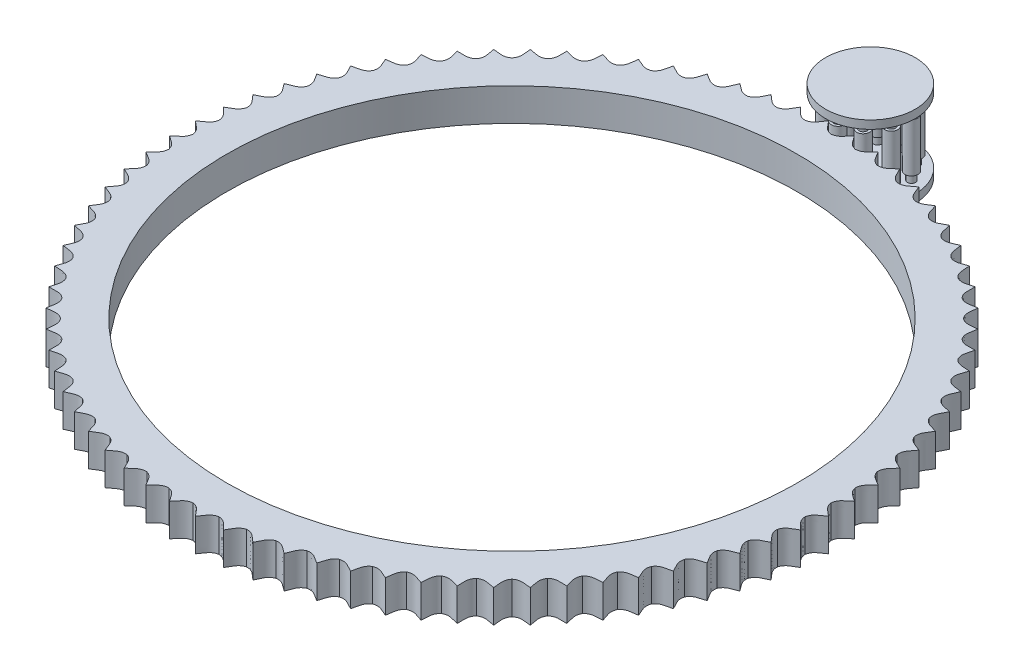
SolidWorks part; units mm, degrees
ref_plane "Front Plane" through (0, 0, 0) normal (0, 0, 1) x (1, 0, 0)
ref_plane "Top Plane" through (0, 0, 0) normal (0, 1, 0) x (1, 0, 0)
ref_plane "Right Plane" through (0, 0, 0) normal (1, 0, 0) x (0, 0, -1)
sketch "Sketch2" plane through (0, 0, 0) normal (0, 1, 0) x (1, 0, 0)
  line L0 (0, 20) -> (0, 0) construction
  line L1 (0, 0) -> (11.7557, 16.1803) construction
  circle A0 centre (0, 0) radius 20
  circle A1 centre (0, 20) radius 4
  circle A2 centre (11.7557, 16.1803) radius 4
  circle A3 centre (19.0211, 6.1803) radius 4
  circle A4 centre (19.0211, -6.1803) radius 4
  circle A5 centre (11.7557, -16.1803) radius 4
  circle A6 centre (0, -20) radius 4
  circle A7 centre (-11.7557, -16.1803) radius 4
  circle A8 centre (-19.0211, -6.1803) radius 4
  circle A9 centre (-19.0211, 6.1803) radius 4
  circle A10 centre (-11.7557, 16.1803) radius 4
  circle A12 centre (0, -220) radius 200
  point P25 (0, 0)
  dimension "D1" = 40
  dimension "D2" = 8
  dimension "D5" = 400
  dimension "D4" = 36
  dimension "D3" = 10
sketch "Sketch3" plane through (0, 0, 0) normal (0, 1, 0) x (1, 0, 0)
  line L0 (0, -220) -> (0, -20) construction
  line L1 (0, -220) -> (-15.6918, -20.6165) construction
  line L2 (0, -220) -> (-91.844, 1.7311) construction
  circle A0 centre (0, 0) radius 20 construction
  circle A1 centre (0, 0) radius 20
  circle A2 centre (-17.261, -0.6782) radius 20
  circle A3 centre (-34.4156, -2.7086) radius 20
  circle A4 centre (-51.358, -6.0786) radius 20
  circle A5 centre (-67.9837, -10.7676) radius 20
  circle A6 centre (-84.1904, -16.7465) radius 20
  circle A7 centre (-99.8779, -23.9786) radius 20
  circle A8 centre (-114.9497, -32.4192) radius 20
  circle A9 centre (-129.3128, -42.0163) radius 20
  circle A10 centre (-142.8786, -52.7107) radius 20
  circle A11 centre (-155.5635, -64.4365) radius 20
  point P3 (0, -20)
  point P4 (11.7557, -16.1803)
  point P6 (19.0211, -6.1803)
  point P8 (19.0211, 6.1803)
  point P10 (11.7557, 16.1803)
  point P12 (0, 20)
  point P14 (-11.7557, 16.1803)
  point P16 (-19.0211, 6.1803)
  point P18 (-19.0211, -6.1803)
  point P20 (-11.7557, -16.1803)
  point P27 (-15.6918, -20.6165)
  point P28 (-4.272, -15.8863)
  point P29 (2.1864, -5.3471)
  point P30 (1.2166, 6.9755)
  point P31 (-6.811, 16.3746)
  point P32 (-18.8302, 19.2602)
  point P33 (-30.25, 14.5299)
  point P34 (-36.7084, 3.9907)
  point P35 (-35.7386, -8.3319)
  point P36 (-27.711, -17.731)
  point P39 (-31.2869, -22.4623)
  point P40 (-20.2734, -16.8507)
  point P41 (-14.6618, -5.8373)
  point P42 (-16.5955, 6.3712)
  point P43 (-25.3358, 15.1116)
  point P44 (-37.5443, 17.0452)
  point P45 (-48.5577, 11.4336)
  point P46 (-54.1693, 0.4201)
  point P47 (-52.2357, -11.7884)
  point P48 (-43.4954, -20.5287)
  point P51 (-46.6891, -25.526)
  point P52 (-36.1499, -19.0676)
  point P53 (-31.4196, -7.6478)
  point P54 (-34.3052, 4.3714)
  point P55 (-43.7043, 12.399)
  point P56 (-56.0269, 13.3688)
  point P57 (-66.5661, 6.9103)
  point P58 (-71.2963, -4.5094)
  point P59 (-68.4108, -16.5286)
  point P60 (-59.0116, -24.5562)
  point P63 (-61.8034, -29.7887)
  point P64 (-51.8034, -22.5233)
  point P65 (-47.9837, -10.7676)
  point P66 (-51.8034, 0.9881)
  point P67 (-61.8034, 8.2536)
  point P68 (-74.1641, 8.2536)
  point P69 (-84.1641, 0.9881)
  point P70 (-87.9837, -10.7676)
  point P71 (-84.1641, -22.5233)
  point P72 (-74.1641, -29.7887)
  point P75 (-76.5367, -35.2241)
  point P76 (-67.1376, -27.1965)
  point P77 (-64.252, -15.1773)
  point P78 (-68.9822, -3.7575)
  point P79 (-79.5214, 2.7009)
  point P80 (-91.844, 1.7311)
  point P81 (-101.2432, -6.2965)
  point P82 (-104.1287, -18.3157)
  point P83 (-99.3985, -29.7355)
  point P84 (-88.8593, -36.1939)
  point P87 (-90.7981, -41.7987)
  point P88 (-82.0578, -33.0584)
  point P89 (-80.1241, -20.8499)
  point P90 (-85.7358, -9.8364)
  point P91 (-96.7492, -4.2248)
  point P92 (-108.9577, -6.1584)
  point P93 (-117.698, -14.8988)
  point P94 (-119.6317, -27.1073)
  point P95 (-114.02, -38.1207)
  point P96 (-103.0066, -43.7323)
  point P99 (-104.4997, -49.472)
  point P100 (-96.4721, -40.0728)
  point P101 (-95.5023, -27.7503)
  point P102 (-101.9607, -17.211)
  point P103 (-113.3805, -12.4808)
  point P104 (-125.3997, -15.3664)
  point P105 (-133.4273, -24.7655)
  point P106 (-134.3971, -37.0881)
  point P107 (-127.9386, -47.6273)
  point P108 (-116.5189, -52.3575)
  point P111 (-117.5571, -58.1966)
  point P112 (-110.2916, -48.1966)
  point P113 (-110.2916, -35.8359)
  point P114 (-117.5571, -25.8359)
  point P115 (-129.3128, -22.0163)
  point P116 (-141.0685, -25.8359)
  point P117 (-148.3339, -35.8359)
  point P118 (-148.3339, -48.1966)
  point P119 (-141.0685, -58.1966)
  point P120 (-129.3128, -62.0163)
  point P123 (-129.8896, -67.9188)
  point P124 (-123.4312, -57.3796)
  point P125 (-124.401, -45.057)
  point P126 (-132.4286, -35.6579)
  point P127 (-144.4478, -32.7723)
  point P128 (-155.8675, -37.5026)
  point P129 (-162.326, -48.0418)
  point P130 (-161.3562, -60.3644)
  point P131 (-153.3285, -69.7635)
  point P132 (-141.3094, -72.649)
  point P135 (-141.4214, -78.5786)
  point P136 (-135.8097, -67.5652)
  point P137 (-137.7434, -55.3567)
  point P138 (-146.4837, -46.6164)
  point P139 (-158.6922, -44.6827)
  point P140 (-169.7056, -50.2944)
  point P141 (-175.3173, -61.3078)
  point P142 (-173.3836, -73.5163)
  point P143 (-164.6433, -82.2566)
  point P144 (-152.4348, -84.1903)
  dimension "D2" = 4.5
  dimension "D1" = 11
sketch "Sketch4" plane through (0, 0, 0) normal (0, 1, 0) x (1, 0, 0)
  line L0 (0, 0) -> (0, -20) construction
  line L1 (0, 0) -> (4.1582, -19.563) construction
  line L2 (0, -220) -> (0, -20) construction
  line L3 (0, -220) -> (-5.2354, -20.0685) construction
  circle A0 centre (0, 0) radius 20 construction
  circle A1 centre (0, 0) radius 20
  circle A2 centre (-5.7589, -0.0754) radius 20
  circle A3 centre (-11.5139, -0.3015) radius 20
  circle A4 centre (-17.261, -0.6782) radius 20
  circle A5 centre (-22.9963, -1.2052) radius 20
  circle A6 centre (-28.7158, -1.8821) radius 20
  point P3 (0, -20)
  point P7 (4.1582, -19.563)
  point P8 (8.1347, -18.2709)
  point P9 (11.7557, -16.1803)
  point P10 (14.8629, -13.3826)
  point P11 (17.3205, -10)
  point P12 (19.0211, -6.1803)
  point P19 (-5.2354, -20.0685)
  point P20 (-1.09, -19.5228)
  point P21 (2.8513, -18.1271)
  point P22 (6.4163, -15.9425)
  point P23 (9.4492, -13.0643)
  point P24 (11.8174, -9.6186)
  point P25 (13.4175, -5.7557)
  point P28 (-10.4672, -20.2741)
  point P29 (-6.3375, -19.62)
  point P30 (-2.4341, -18.1216)
  point P31 (1.0725, -15.8444)
  point P32 (4.029, -12.8879)
  point P33 (6.3062, -9.3813)
  point P34 (7.8046, -5.4779)
  point P37 (-15.6918, -20.6165)
  point P38 (-11.5807, -19.8546)
  point P39 (-7.7178, -18.2545)
  point P40 (-4.272, -15.8863)
  point P41 (-1.3939, -12.8534)
  point P42 (0.7907, -9.2884)
  point P43 (2.1864, -5.3471)
  point P46 (-20.9057, -21.0956)
  point P47 (-16.8159, -20.2263)
  point P48 (-12.9963, -18.5257)
  point P49 (-9.6136, -16.0681)
  point P50 (-6.8159, -12.9609)
  point P51 (-4.7254, -9.3399)
  point P52 (-3.4333, -5.3634)
  point P55 (-26.1052, -21.711)
  point P56 (-22.0396, -20.735)
  point P57 (-18.2658, -18.9349)
  point P58 (-14.9487, -16.3896)
  point P59 (-12.2332, -13.2103)
  point P60 (-10.2382, -9.5358)
  point P61 (-9.0507, -5.5268)
  dimension "D2" = 12
  dimension "D4" = 1.5
  dimension "D1" = 7
  dimension "D3" = 6
sketch "Sketch5" plane through (0, 0, 0) normal (0, 1, 0) x (1, 0, 0)
  line L0 (-91.844, 1.7311) -> (0, -220) construction
  spline S0 degree 3 poles (0, -20) (-1.098, -19.7931) (-2.3907, -18.16) (-4.469, -15.6344) (-6.9937, -12.684) (-10.4117, -9.27) (-18.7988, -2.2618) (-45.0104, 11.0395) (-73.8227, 9.2601) (-91.844, 1.7311) knots 0 0 0 0 0.030956 0.059564 0.097887 0.14575 0.20275 0.42159 1 1 1 1
  spline S1 degree 3 poles (-141.4214, -78.5786) (-140.7912, -77.656) (-141.0319, -75.5871) (-141.3482, -72.3316) (-141.6492, -68.4602) (-141.6464, -63.6292) (-140.6714, -52.743) (-131.5425, -24.8033) (-109.9109, -5.6881) (-91.844, 1.7311) knots 0 0 0 0 0.030956 0.059564 0.097887 0.14575 0.20275 0.42159 1 1 1 1
sketch "Sketch6" plane through (0, 0, 0) normal (0, 1, 0) x (1, 0, 0)
  spline S0 degree 3 poles (1103.3343, 1647.5756) (17.178, -45.525) (5.9507, -28.2968) (-4.469, -15.6344) (-6.9937, -12.684) (-10.4117, -9.27) (-18.7988, -2.2618) (-170.0233, 74.4784) (-481.9037, -379.5936) (1763.791, -655.1147) knots -0.392877 -0.392877 -0.392877 -0.392877 0.030956 0.059564 0.097887 0.14575 0.20275 0.42159 5.074246 5.074246 5.074246 5.074246 only from (0, -20) to (-91.844, 1.7311) construction
  spline S1 degree 3 poles (-2100.7505, 320.4002) (-135.5191, -108.7742) (-139.7624, -88.6532) (-141.3482, -72.3316) (-141.6492, -68.4602) (-141.6464, -63.6292) (-140.6714, -52.743) (-88.003, 108.4523) (453.6071, 7.9077) (-939.5161, -1774.8611) knots -0.392877 -0.392877 -0.392877 -0.392877 0.030956 0.059564 0.097887 0.14575 0.20275 0.42159 5.074246 5.074246 5.074246 5.074246 only from (-141.4214, -78.5786) to (-91.844, 1.7311) construction
  spline S2 degree 3 poles (0, -20) (-1.098, -19.7931) (-2.3907, -18.16) (-4.469, -15.6344) (-6.9937, -12.684) (-10.4117, -9.27) (-18.7988, -2.2618) (-45.0104, 11.0395) (-73.8227, 9.2601) (-91.844, 1.7311) knots 0 0 0 0 0.030956 0.059564 0.097887 0.14575 0.20275 0.42159 1 1 1 1
  spline S3 degree 3 poles (-141.4214, -78.5786) (-140.7912, -77.656) (-141.0319, -75.5871) (-141.3482, -72.3316) (-141.6492, -68.4602) (-141.6464, -63.6292) (-140.6714, -52.743) (-131.5425, -24.8033) (-109.9109, -5.6881) (-91.844, 1.7311) knots 0 0 0 0 0.030956 0.059564 0.097887 0.14575 0.20275 0.42159 1 1 1 1
  spline S4 degree 3 poles (0, -20) (1.098, -19.7931) (2.3907, -18.16) (4.469, -15.6344) (6.9937, -12.684) (10.4117, -9.27) (18.7988, -2.2618) (45.0104, 11.0395) (73.8227, 9.2601) (91.844, 1.7311) knots 0 0 0 0 0.030956 0.059564 0.097887 0.14575 0.20275 0.42159 1 1 1 1
  spline S5 degree 3 poles (141.4214, -78.5786) (140.7912, -77.656) (141.0319, -75.5871) (141.3482, -72.3316) (141.6492, -68.4602) (141.6464, -63.6292) (140.6714, -52.743) (131.5425, -24.8033) (109.9109, -5.6881) (91.844, 1.7311) knots 0 0 0 0 0.030956 0.059564 0.097887 0.14575 0.20275 0.42159 1 1 1 1
  spline S6 degree 3 poles (141.4214, -78.5786) (142.344, -79.2088) (144.4129, -78.9681) (147.6684, -78.6518) (151.5398, -78.3508) (156.3708, -78.3536) (167.257, -79.3286) (195.1967, -88.4575) (214.3119, -110.0891) (221.7311, -128.156) knots 0 0 0 0 0.030956 0.059564 0.097887 0.14575 0.20275 0.42159 1 1 1 1
  spline S7 degree 3 poles (200, -220) (200.2069, -218.902) (201.84, -217.6093) (204.3656, -215.531) (207.316, -213.0063) (210.73, -209.5883) (217.7382, -201.2012) (231.0395, -174.9896) (229.2601, -146.1773) (221.7311, -128.156) knots 0 0 0 0 0.030956 0.059564 0.097887 0.14575 0.20275 0.42159 1 1 1 1
  spline S8 degree 3 poles (200, -220) (200.2069, -221.098) (201.84, -222.3907) (204.3656, -224.469) (207.316, -226.9937) (210.73, -230.4117) (217.7382, -238.7988) (231.0395, -265.0104) (229.2601, -293.8227) (221.7311, -311.844) knots 0 0 0 0 0.030956 0.059564 0.097887 0.14575 0.20275 0.42159 1 1 1 1
  spline S9 degree 3 poles (141.4214, -361.4214) (142.344, -360.7912) (144.4129, -361.0319) (147.6684, -361.3482) (151.5398, -361.6492) (156.3708, -361.6464) (167.257, -360.6714) (195.1967, -351.5425) (214.3119, -329.9109) (221.7311, -311.844) knots 0 0 0 0 0.030956 0.059564 0.097887 0.14575 0.20275 0.42159 1 1 1 1
  spline S10 degree 3 poles (141.4214, -361.4214) (140.7912, -362.344) (141.0319, -364.4129) (141.3482, -367.6684) (141.6492, -371.5398) (141.6464, -376.3708) (140.6714, -387.257) (131.5425, -415.1967) (109.9109, -434.3119) (91.844, -441.7311) knots 0 0 0 0 0.030956 0.059564 0.097887 0.14575 0.20275 0.42159 1 1 1 1
  spline S11 degree 3 poles (0, -420) (1.098, -420.2069) (2.3907, -421.84) (4.469, -424.3656) (6.9937, -427.316) (10.4117, -430.73) (18.7988, -437.7382) (45.0104, -451.0395) (73.8227, -449.2601) (91.844, -441.7311) knots 0 0 0 0 0.030956 0.059564 0.097887 0.14575 0.20275 0.42159 1 1 1 1
  spline S12 degree 3 poles (0, -420) (-1.098, -420.2069) (-2.3907, -421.84) (-4.469, -424.3656) (-6.9937, -427.316) (-10.4117, -430.73) (-18.7988, -437.7382) (-45.0104, -451.0395) (-73.8227, -449.2601) (-91.844, -441.7311) knots 0 0 0 0 0.030956 0.059564 0.097887 0.14575 0.20275 0.42159 1 1 1 1
  spline S13 degree 3 poles (-141.4214, -361.4214) (-140.7912, -362.344) (-141.0319, -364.4129) (-141.3482, -367.6684) (-141.6492, -371.5398) (-141.6464, -376.3708) (-140.6714, -387.257) (-131.5425, -415.1967) (-109.9109, -434.3119) (-91.844, -441.7311) knots 0 0 0 0 0.030956 0.059564 0.097887 0.14575 0.20275 0.42159 1 1 1 1
  spline S14 degree 3 poles (-141.4214, -361.4214) (-142.344, -360.7912) (-144.4129, -361.0319) (-147.6684, -361.3482) (-151.5398, -361.6492) (-156.3708, -361.6464) (-167.257, -360.6714) (-195.1967, -351.5425) (-214.3119, -329.9109) (-221.7311, -311.844) knots 0 0 0 0 0.030956 0.059564 0.097887 0.14575 0.20275 0.42159 1 1 1 1
  spline S15 degree 3 poles (-200, -220) (-200.2069, -221.098) (-201.84, -222.3907) (-204.3656, -224.469) (-207.316, -226.9937) (-210.73, -230.4117) (-217.7382, -238.7988) (-231.0395, -265.0104) (-229.2601, -293.8227) (-221.7311, -311.844) knots 0 0 0 0 0.030956 0.059564 0.097887 0.14575 0.20275 0.42159 1 1 1 1
  spline S16 degree 3 poles (-200, -220) (-200.2069, -218.902) (-201.84, -217.6093) (-204.3656, -215.531) (-207.316, -213.0063) (-210.73, -209.5883) (-217.7382, -201.2012) (-231.0395, -174.9896) (-229.2601, -146.1773) (-221.7311, -128.156) knots 0 0 0 0 0.030956 0.059564 0.097887 0.14575 0.20275 0.42159 1 1 1 1
  spline S17 degree 3 poles (-141.4214, -78.5786) (-142.344, -79.2088) (-144.4129, -78.9681) (-147.6684, -78.6518) (-151.5398, -78.3508) (-156.3708, -78.3536) (-167.257, -79.3286) (-195.1967, -88.4575) (-214.3119, -110.0891) (-221.7311, -128.156) knots 0 0 0 0 0.030956 0.059564 0.097887 0.14575 0.20275 0.42159 1 1 1 1
  point P26 (0, -220)
sketch "Sketch7" plane through (0, 0, 0) normal (0, 1, 0) x (1, 0, 0)
  spline S0 degree 3 poles (1103.3343, 1647.5756) (17.178, -45.525) (5.9507, -28.2968) (-4.469, -15.6344) (-6.9937, -12.684) (-10.4117, -9.27) (-18.7988, -2.2618) (-170.0233, 74.4784) (-481.9037, -379.5936) (1763.791, -655.1147) knots -0.392877 -0.392877 -0.392877 -0.392877 0.030956 0.059564 0.097887 0.14575 0.20275 0.42159 5.074246 5.074246 5.074246 5.074246 only from (0, -20) to (-91.844, 1.7311) construction
  spline S1 degree 3 poles (-2100.7505, 320.4002) (-135.5191, -108.7742) (-139.7624, -88.6532) (-141.3482, -72.3316) (-141.6492, -68.4602) (-141.6464, -63.6292) (-140.6714, -52.743) (-88.003, 108.4523) (453.6071, 7.9077) (-939.5161, -1774.8611) knots -0.392877 -0.392877 -0.392877 -0.392877 0.030956 0.059564 0.097887 0.14575 0.20275 0.42159 5.074246 5.074246 5.074246 5.074246 only from (-141.4214, -78.5786) to (-91.844, 1.7311) construction
  spline S2 degree 3 poles (0, -20) (-1.098, -19.7931) (-2.3907, -18.16) (-4.469, -15.6344) (-6.9937, -12.684) (-10.4117, -9.27) (-18.7988, -2.2618) (-45.0104, 11.0395) (-73.8227, 9.2601) (-91.844, 1.7311) knots 0 0 0 0 0.030956 0.059564 0.097887 0.14575 0.20275 0.42159 1 1 1 1
  spline S3 degree 3 poles (-141.4214, -78.5786) (-140.7912, -77.656) (-141.0319, -75.5871) (-141.3482, -72.3316) (-141.6492, -68.4602) (-141.6464, -63.6292) (-140.6714, -52.743) (-131.5425, -24.8033) (-109.9109, -5.6881) (-91.844, 1.7311) knots 0 0 0 0 0.030956 0.059564 0.097887 0.14575 0.20275 0.42159 1 1 1 1
  spline S4 degree 3 poles (-129.8896, -67.9188) (-129.189, -67.0484) (-129.2667, -64.967) (-129.3266, -61.6968) (-129.3229, -57.8136) (-128.941, -52.9978) (-127.1149, -42.2217) (-115.822, -15.0843) (-92.7573, 2.2748) (-74.1641, 8.2536) knots 0 0 0 0 0.030956 0.059564 0.097887 0.14575 0.20275 0.42159 1 1 1 1
  spline S5 degree 3 poles (15.6918, -20.6165) (14.6134, -20.3241) (13.4528, -18.5947) (11.5791, -15.9137) (9.2936, -12.7744) (6.154, -9.1028) (-1.6573, -1.458) (-26.7445, 13.8588) (-55.6076, 14.3454) (-74.1641, 8.2536) knots 0 0 0 0 0.030956 0.059564 0.097887 0.14575 0.20275 0.42159 1 1 1 1
  spline S6 degree 3 poles (-117.5571, -58.1966) (-116.7904, -57.3839) (-116.7044, -55.3028) (-116.5076, -52.0379) (-116.1992, -48.167) (-115.4407, -43.396) (-112.7748, -32.7964) (-99.3875, -6.6287) (-75.0319, 8.8672) (-56.0269, 13.3688) knots 0 0 0 0 0.030956 0.059564 0.097887 0.14575 0.20275 0.42159 1 1 1 1
  spline S7 degree 3 poles (31.2869, -22.4623) (30.2348, -22.0862) (29.2134, -20.271) (27.5558, -17.4514) (25.5237, -14.1424) (22.6819, -10.2357) (15.4944, -2.0017) (-8.3137, 15.2362) (-37.0496, 17.986) (-56.0269, 13.3688) knots 0 0 0 0 0.030956 0.059564 0.097887 0.14575 0.20275 0.42159 1 1 1 1
  spline S8 degree 3 poles (-104.4997, -49.472) (-103.6716, -48.7219) (-103.4227, -46.654) (-102.9703, -43.4146) (-102.3591, -39.5799) (-101.2286, -34.8831) (-97.7393, -24.5253) (-82.3402, 0.5114) (-56.8439, 14.0486) (-37.5443, 17.0452) knots 0 0 0 0 0.030956 0.059564 0.097887 0.14575 0.20275 0.42159 1 1 1 1
  spline S9 degree 3 poles (46.6891, -25.526) (45.6697, -25.0685) (44.7939, -23.1788) (43.3627, -20.2378) (41.5964, -16.7795) (39.0699, -12.662) (32.5506, -3.8894) (10.1684, 15.1633) (-18.2632, 20.1592) (-37.5443, 17.0452) knots 0 0 0 0 0.030956 0.059564 0.097887 0.14575 0.20275 0.42159 1 1 1 1
  spline S10 degree 3 poles (-90.7981, -41.7987) (-89.9137, -41.1159) (-89.5033, -39.0739) (-88.7981, -35.88) (-87.888, -32.105) (-86.3925, -27.5114) (-82.1012, -17.4593) (-64.7852, 6.292) (-38.3054, 17.7871) (-18.8302, 19.2602) knots 0 0 0 0 0.030956 0.059564 0.097887 0.14575 0.20275 0.42159 1 1 1 1
  spline S11 degree 3 poles (61.8034, -29.7887) (60.8231, -29.2526) (60.0983, -27.3) (58.9022, -24.2558) (57.4127, -20.6696) (55.217, -16.3665) (49.4061, -7.1095) (28.5877, 13.6406) (0.6357, 20.8518) (-18.8302, 19.2602) knots 0 0 0 0 0.030956 0.059564 0.097887 0.14575 0.20275 0.42159 1 1 1 1
  spline S12 degree 3 poles (-76.5367, -35.2241) (-75.6014, -34.6128) (-75.0321, -32.6093) (-74.0785, -29.4806) (-72.875, -25.7886) (-71.0237, -21.3265) (-65.957, -11.6421) (-46.8308, 10.6774) (-19.5308, 20.0594) (0, 20) knots 0 0 0 0 0.030956 0.059564 0.097887 0.14575 0.20275 0.42159 1 1 1 1
  spline S13 degree 3 poles (76.5367, -35.2241) (75.6014, -34.6128) (75.0321, -32.6093) (74.0785, -29.4806) (72.875, -25.7886) (71.0237, -21.3265) (65.957, -11.6421) (46.8308, 10.6774) (19.5308, 20.0594) (0, 20) knots 0 0 0 0 0.030956 0.059564 0.097887 0.14575 0.20275 0.42159 1 1 1 1
  spline S14 degree 3 poles (-61.8034, -29.7887) (-60.8231, -29.2526) (-60.0983, -27.3) (-58.9022, -24.2558) (-57.4127, -20.6696) (-55.217, -16.3665) (-49.4061, -7.1095) (-28.5877, 13.6406) (-0.6357, 20.8518) (18.8302, 19.2602) knots 0 0 0 0 0.030956 0.059564 0.097887 0.14575 0.20275 0.42159 1 1 1 1
  spline S15 degree 3 poles (90.7981, -41.7987) (89.9137, -41.1159) (89.5033, -39.0739) (88.7981, -35.88) (87.888, -32.105) (86.3925, -27.5114) (82.1012, -17.4593) (64.7852, 6.292) (38.3054, 17.7871) (18.8302, 19.2602) knots 0 0 0 0 0.030956 0.059564 0.097887 0.14575 0.20275 0.42159 1 1 1 1
  spline S16 degree 3 poles (-46.6891, -25.526) (-45.6697, -25.0685) (-44.7939, -23.1788) (-43.3627, -20.2378) (-41.5964, -16.7795) (-39.0699, -12.662) (-32.5506, -3.8894) (-10.1684, 15.1633) (18.2632, 20.1592) (37.5443, 17.0452) knots 0 0 0 0 0.030956 0.059564 0.097887 0.14575 0.20275 0.42159 1 1 1 1
  spline S17 degree 3 poles (104.4997, -49.472) (103.6716, -48.7219) (103.4227, -46.654) (102.9703, -43.4146) (102.3591, -39.5799) (101.2286, -34.8831) (97.7393, -24.5253) (82.3402, 0.5114) (56.8439, 14.0486) (37.5443, 17.0452) knots 0 0 0 0 0.030956 0.059564 0.097887 0.14575 0.20275 0.42159 1 1 1 1
  spline S18 degree 3 poles (-31.2869, -22.4623) (-30.2348, -22.0862) (-29.2134, -20.271) (-27.5558, -17.4514) (-25.5237, -14.1424) (-22.6819, -10.2357) (-15.4944, -2.0017) (8.3137, 15.2362) (37.0496, 17.986) (56.0269, 13.3688) knots 0 0 0 0 0.030956 0.059564 0.097887 0.14575 0.20275 0.42159 1 1 1 1
  spline S19 degree 3 poles (117.5571, -58.1966) (116.7904, -57.3839) (116.7044, -55.3028) (116.5076, -52.0379) (116.1992, -48.167) (115.4407, -43.396) (112.7748, -32.7964) (99.3875, -6.6287) (75.0319, 8.8672) (56.0269, 13.3688) knots 0 0 0 0 0.030956 0.059564 0.097887 0.14575 0.20275 0.42159 1 1 1 1
  spline S20 degree 3 poles (-15.6918, -20.6165) (-14.6134, -20.3241) (-13.4528, -18.5947) (-11.5791, -15.9137) (-9.2936, -12.7744) (-6.154, -9.1028) (1.6573, -1.458) (26.7445, 13.8588) (55.6076, 14.3454) (74.1641, 8.2536) knots 0 0 0 0 0.030956 0.059564 0.097887 0.14575 0.20275 0.42159 1 1 1 1
  spline S21 degree 3 poles (129.8896, -67.9188) (129.189, -67.0484) (129.2667, -64.967) (129.3266, -61.6968) (129.3229, -57.8136) (128.941, -52.9978) (127.1149, -42.2217) (115.822, -15.0843) (92.7573, 2.2748) (74.1641, 8.2536) knots 0 0 0 0 0.030956 0.059564 0.097887 0.14575 0.20275 0.42159 1 1 1 1
  spline S22 degree 3 poles (0, -20) (1.098, -19.7931) (2.3907, -18.16) (4.469, -15.6344) (6.9937, -12.684) (10.4117, -9.27) (18.7988, -2.2618) (45.0104, 11.0395) (73.8227, 9.2601) (91.844, 1.7311) knots 0 0 0 0 0.030956 0.059564 0.097887 0.14575 0.20275 0.42159 1 1 1 1
  spline S23 degree 3 poles (141.4214, -78.5786) (140.7912, -77.656) (141.0319, -75.5871) (141.3482, -72.3316) (141.6492, -68.4602) (141.6464, -63.6292) (140.6714, -52.743) (131.5425, -24.8033) (109.9109, -5.6881) (91.844, 1.7311) knots 0 0 0 0 0.030956 0.059564 0.097887 0.14575 0.20275 0.42159 1 1 1 1
  spline S24 degree 3 poles (15.6918, -20.6165) (16.8027, -20.4964) (18.2195, -18.9698) (20.4896, -16.615) (23.238, -13.8718) (26.9133, -10.7366) (35.8244, -4.4079) (62.9988, 6.7958) (91.5826, 2.7613) (108.9577, -6.1584) knots 0 0 0 0 0.030956 0.059564 0.097887 0.14575 0.20275 0.42159 1 1 1 1
  spline S25 degree 3 poles (152.0812, -90.1104) (151.5254, -89.1411) (151.9277, -87.0975) (152.4984, -83.8769) (153.1022, -80.041) (153.4784, -75.2247) (153.3606, -64.2956) (146.4519, -35.7257) (126.3868, -14.9723) (108.9577, -6.1584) knots 0 0 0 0 0.030956 0.059564 0.097887 0.14575 0.20275 0.42159 1 1 1 1
  spline S26 degree 3 poles (31.2869, -22.4623) (32.4037, -22.4298) (33.936, -21.019) (36.3838, -18.8496) (39.339, -16.3305) (43.249, -13.4932) (52.6291, -7.8833) (80.5988, 1.1539) (108.778, -5.1109) (125.3997, -15.3664) knots 0 0 0 0 0.030956 0.059564 0.097887 0.14575 0.20275 0.42159 1 1 1 1
  spline S27 degree 3 poles (161.8034, -102.4429) (161.3254, -101.4331) (161.8867, -99.4273) (162.7084, -96.2614) (163.6113, -92.4847) (164.3642, -87.7128) (165.1043, -76.8081) (160.4585, -47.7842) (142.0835, -25.5205) (125.3997, -15.3664) knots 0 0 0 0 0.030956 0.059564 0.097887 0.14575 0.20275 0.42159 1 1 1 1
  spline S28 degree 3 poles (46.6891, -25.526) (47.805, -25.5812) (49.4433, -24.295) (52.0537, -22.3243) (55.1975, -20.0449) (59.318, -17.5231) (69.1094, -12.6664) (97.7018, -5.8516) (125.3027, -14.3079) (141.0685, -25.8359) knots 0 0 0 0 0.030956 0.059564 0.097887 0.14575 0.20275 0.42159 1 1 1 1
  spline S29 degree 3 poles (170.528, -115.5003) (170.1307, -114.456) (170.8477, -112.5005) (171.9153, -109.4088) (173.1117, -105.7146) (174.2367, -101.0164) (175.83, -90.2035) (173.4757, -60.9045) (156.9042, -37.2677) (141.0685, -25.8359) knots 0 0 0 0 0.030956 0.059564 0.097887 0.14575 0.20275 0.42159 1 1 1 1
  spline S30 degree 3 poles (61.8034, -29.7887) (62.9116, -29.9312) (64.6457, -28.7775) (67.4027, -27.0178) (70.7156, -24.992) (75.0213, -22.8013) (85.1636, -18.7278) (114.2025, -14.1773) (141.0548, -24.7731) (155.8675, -37.5026) knots 0 0 0 0 0.030956 0.059564 0.097887 0.14575 0.20275 0.42159 1 1 1 1
  spline S31 degree 3 poles (178.2013, -129.2019) (177.8872, -128.1297) (178.7554, -126.2364) (180.0622, -123.238) (181.5448, -119.6491) (183.0349, -115.0537) (185.4717, -104.399) (185.4234, -75.0057) (170.7575, -50.1416) (155.8675, -37.5026) knots 0 0 0 0 0.030956 0.059564 0.097887 0.14575 0.20275 0.42159 1 1 1 1
  spline S32 degree 3 poles (76.5367, -35.2241) (77.6303, -35.4531) (79.4495, -34.4391) (82.3362, -32.901) (85.7978, -31.1414) (90.2621, -29.2953) (100.6927, -26.0301) (129.9991, -23.772) (155.9373, -36.442) (169.7056, -50.2944) knots 0 0 0 0 0.030956 0.059564 0.097887 0.14575 0.20275 0.42159 1 1 1 1
  spline S33 degree 3 poles (184.7759, -143.4633) (184.5469, -142.3697) (185.5609, -140.5505) (187.099, -137.6638) (188.8586, -134.2022) (190.7047, -129.7379) (193.9699, -119.3073) (196.228, -90.0009) (183.558, -64.0627) (169.7056, -50.2944) knots 0 0 0 0 0.030956 0.059564 0.097887 0.14575 0.20275 0.42159 1 1 1 1
  spline S34 degree 3 poles (90.7981, -41.7987) (91.8703, -42.1128) (93.7636, -41.2446) (96.762, -39.9378) (100.3509, -38.4552) (104.9463, -36.9651) (115.601, -34.5283) (144.9943, -34.5766) (169.8584, -49.2425) (182.4974, -64.1325) knots 0 0 0 0 0.030956 0.059564 0.097887 0.14575 0.20275 0.42159 1 1 1 1
  spline S35 degree 3 poles (190.2113, -158.1966) (190.0688, -157.0884) (191.2225, -155.3543) (192.9822, -152.5973) (195.008, -149.2844) (197.1987, -144.9787) (201.2722, -134.8364) (205.8227, -105.7975) (195.2269, -78.9452) (182.4974, -64.1325) knots 0 0 0 0 0.030956 0.059564 0.097887 0.14575 0.20275 0.42159 1 1 1 1
  spline S36 degree 3 poles (104.4997, -49.472) (105.544, -49.8693) (107.4995, -49.1523) (110.5912, -48.0847) (114.2854, -46.8883) (118.9836, -45.7633) (129.7965, -44.17) (159.0955, -46.5243) (182.7323, -63.0958) (194.1641, -78.9315) knots 0 0 0 0 0.030956 0.059564 0.097887 0.14575 0.20275 0.42159 1 1 1 1
  spline S37 degree 3 poles (194.474, -173.3109) (194.4188, -172.195) (195.705, -170.5567) (197.6757, -167.9463) (199.9551, -164.8025) (202.4769, -160.682) (207.3336, -150.8906) (214.1484, -122.2982) (205.6921, -94.6973) (194.1641, -78.9315) knots 0 0 0 0 0.030956 0.059564 0.097887 0.14575 0.20275 0.42159 1 1 1 1
  spline S38 degree 3 poles (117.5571, -58.1966) (118.5669, -58.6746) (120.5727, -58.1133) (123.7386, -57.2916) (127.5153, -56.3887) (132.2872, -55.6358) (143.1919, -54.8957) (172.2158, -59.5415) (194.4795, -77.9165) (204.6336, -94.6003) knots 0 0 0 0 0.030956 0.059564 0.097887 0.14575 0.20275 0.42159 1 1 1 1
  spline S39 degree 3 poles (197.5377, -188.7131) (197.5702, -187.5963) (198.981, -186.064) (201.1504, -183.6162) (203.6695, -180.661) (206.5068, -176.751) (212.1167, -167.3709) (221.1539, -139.4012) (214.8891, -111.222) (204.6336, -94.6003) knots 0 0 0 0 0.030956 0.059564 0.097887 0.14575 0.20275 0.42159 1 1 1 1
  spline S40 degree 3 poles (129.8896, -67.9188) (130.8589, -68.4746) (132.9025, -68.0723) (136.1231, -67.5016) (139.959, -66.8978) (144.7753, -66.5216) (155.7044, -66.6394) (184.2743, -73.5481) (205.0277, -93.6132) (213.8416, -111.0423) knots 0 0 0 0 0.030956 0.059564 0.097887 0.14575 0.20275 0.42159 1 1 1 1
  spline S41 degree 3 poles (199.3835, -204.3082) (199.5036, -203.1973) (201.0302, -201.7805) (203.385, -199.5104) (206.1282, -196.762) (209.2634, -193.0867) (215.5921, -184.1756) (226.7958, -157.0012) (222.7613, -128.4174) (213.8416, -111.0423) knots 0 0 0 0 0.030956 0.059564 0.097887 0.14575 0.20275 0.42159 1 1 1 1
  spline S42 degree 3 poles (141.4214, -78.5786) (142.344, -79.2088) (144.4129, -78.9681) (147.6684, -78.6518) (151.5398, -78.3508) (156.3708, -78.3536) (167.257, -79.3286) (195.1967, -88.4575) (214.3119, -110.0891) (221.7311, -128.156) knots 0 0 0 0 0.030956 0.059564 0.097887 0.14575 0.20275 0.42159 1 1 1 1
  spline S43 degree 3 poles (200, -220) (200.2069, -218.902) (201.84, -217.6093) (204.3656, -215.531) (207.316, -213.0063) (210.73, -209.5883) (217.7382, -201.2012) (231.0395, -174.9896) (229.2601, -146.1773) (221.7311, -128.156) knots 0 0 0 0 0.030956 0.059564 0.097887 0.14575 0.20275 0.42159 1 1 1 1
  spline S44 degree 3 poles (152.0812, -90.1104) (152.9516, -90.811) (155.033, -90.7333) (158.3032, -90.6734) (162.1864, -90.6771) (167.0022, -91.059) (177.7783, -92.8851) (204.9157, -104.178) (222.2748, -127.2427) (228.2536, -145.8359) knots 0 0 0 0 0.030956 0.059564 0.097887 0.14575 0.20275 0.42159 1 1 1 1
  spline S45 degree 3 poles (199.3835, -235.6918) (199.6759, -234.6134) (201.4053, -233.4528) (204.0863, -231.5791) (207.2256, -229.2936) (210.8972, -226.154) (218.542, -218.3427) (233.8588, -193.2555) (234.3454, -164.3924) (228.2536, -145.8359) knots 0 0 0 0 0.030956 0.059564 0.097887 0.14575 0.20275 0.42159 1 1 1 1
  spline S46 degree 3 poles (161.8034, -102.4429) (162.6161, -103.2096) (164.6972, -103.2956) (167.9621, -103.4924) (171.833, -103.8008) (176.604, -104.5593) (187.2036, -107.2252) (213.3713, -120.6125) (228.8672, -144.9681) (233.3688, -163.9731) knots 0 0 0 0 0.030956 0.059564 0.097887 0.14575 0.20275 0.42159 1 1 1 1
  spline S47 degree 3 poles (197.5377, -251.2869) (197.9138, -250.2348) (199.729, -249.2134) (202.5486, -247.5558) (205.8576, -245.5237) (209.7643, -242.6819) (217.9983, -235.4944) (235.2362, -211.6863) (237.986, -182.9504) (233.3688, -163.9731) knots 0 0 0 0 0.030956 0.059564 0.097887 0.14575 0.20275 0.42159 1 1 1 1
  spline S48 degree 3 poles (170.528, -115.5003) (171.2781, -116.3284) (173.346, -116.5773) (176.5854, -117.0297) (180.4201, -117.6409) (185.1169, -118.7714) (195.4747, -122.2607) (220.5114, -137.6598) (234.0486, -163.1561) (237.0452, -182.4557) knots 0 0 0 0 0.030956 0.059564 0.097887 0.14575 0.20275 0.42159 1 1 1 1
  spline S49 degree 3 poles (194.474, -266.6891) (194.9315, -265.6697) (196.8212, -264.7939) (199.7622, -263.3627) (203.2205, -261.5964) (207.338, -259.0699) (216.1106, -252.5506) (235.1633, -230.1684) (240.1592, -201.7368) (237.0452, -182.4557) knots 0 0 0 0 0.030956 0.059564 0.097887 0.14575 0.20275 0.42159 1 1 1 1
  spline S50 degree 3 poles (178.2013, -129.2019) (178.8841, -130.0863) (180.9261, -130.4967) (184.12, -131.2019) (187.895, -132.112) (192.4886, -133.6075) (202.5407, -137.8988) (226.292, -155.2148) (237.7871, -181.6946) (239.2602, -201.1698) knots 0 0 0 0 0.030956 0.059564 0.097887 0.14575 0.20275 0.42159 1 1 1 1
  spline S51 degree 3 poles (190.2113, -281.8034) (190.7474, -280.8231) (192.7, -280.0983) (195.7442, -278.9022) (199.3304, -277.4127) (203.6335, -275.217) (212.8905, -269.4061) (233.6406, -248.5877) (240.8518, -220.6357) (239.2602, -201.1698) knots 0 0 0 0 0.030956 0.059564 0.097887 0.14575 0.20275 0.42159 1 1 1 1
  spline S52 degree 3 poles (184.7759, -143.4633) (185.3872, -144.3986) (187.3907, -144.9679) (190.5194, -145.9215) (194.2114, -147.125) (198.6735, -148.9763) (208.3579, -154.043) (230.6774, -173.1692) (240.0594, -200.4692) (240, -220) knots 0 0 0 0 0.030956 0.059564 0.097887 0.14575 0.20275 0.42159 1 1 1 1
  spline S53 degree 3 poles (184.7759, -296.5367) (185.3872, -295.6014) (187.3907, -295.0321) (190.5194, -294.0785) (194.2114, -292.875) (198.6735, -291.0237) (208.3579, -285.957) (230.6774, -266.8308) (240.0594, -239.5308) (240, -220) knots 0 0 0 0 0.030956 0.059564 0.097887 0.14575 0.20275 0.42159 1 1 1 1
  spline S54 degree 3 poles (190.2113, -158.1966) (190.7474, -159.1769) (192.7, -159.9017) (195.7442, -161.0978) (199.3304, -162.5873) (203.6335, -164.783) (212.8905, -170.5939) (233.6406, -191.4123) (240.8518, -219.3643) (239.2602, -238.8302) knots 0 0 0 0 0.030956 0.059564 0.097887 0.14575 0.20275 0.42159 1 1 1 1
  spline S55 degree 3 poles (178.2013, -310.7981) (178.8841, -309.9137) (180.9261, -309.5033) (184.12, -308.7981) (187.895, -307.888) (192.4886, -306.3925) (202.5407, -302.1012) (226.292, -284.7852) (237.7871, -258.3054) (239.2602, -238.8302) knots 0 0 0 0 0.030956 0.059564 0.097887 0.14575 0.20275 0.42159 1 1 1 1
  spline S56 degree 3 poles (194.474, -173.3109) (194.9315, -174.3303) (196.8212, -175.2061) (199.7622, -176.6373) (203.2205, -178.4036) (207.338, -180.9301) (216.1106, -187.4494) (235.1633, -209.8316) (240.1592, -238.2632) (237.0452, -257.5443) knots 0 0 0 0 0.030956 0.059564 0.097887 0.14575 0.20275 0.42159 1 1 1 1
  spline S57 degree 3 poles (170.528, -324.4997) (171.2781, -323.6716) (173.346, -323.4227) (176.5854, -322.9703) (180.4201, -322.3591) (185.1169, -321.2286) (195.4747, -317.7393) (220.5114, -302.3402) (234.0486, -276.8439) (237.0452, -257.5443) knots 0 0 0 0 0.030956 0.059564 0.097887 0.14575 0.20275 0.42159 1 1 1 1
  spline S58 degree 3 poles (197.5377, -188.7131) (197.9138, -189.7652) (199.729, -190.7866) (202.5486, -192.4442) (205.8576, -194.4763) (209.7643, -197.3181) (217.9983, -204.5056) (235.2362, -228.3137) (237.986, -257.0496) (233.3688, -276.0269) knots 0 0 0 0 0.030956 0.059564 0.097887 0.14575 0.20275 0.42159 1 1 1 1
  spline S59 degree 3 poles (161.8034, -337.5571) (162.6161, -336.7904) (164.6972, -336.7044) (167.9621, -336.5076) (171.833, -336.1992) (176.604, -335.4407) (187.2036, -332.7748) (213.3713, -319.3875) (228.8672, -295.0319) (233.3688, -276.0269) knots 0 0 0 0 0.030956 0.059564 0.097887 0.14575 0.20275 0.42159 1 1 1 1
  spline S60 degree 3 poles (199.3835, -204.3082) (199.6759, -205.3866) (201.4053, -206.5472) (204.0863, -208.4209) (207.2256, -210.7064) (210.8972, -213.846) (218.542, -221.6573) (233.8588, -246.7445) (234.3454, -275.6076) (228.2536, -294.1641) knots 0 0 0 0 0.030956 0.059564 0.097887 0.14575 0.20275 0.42159 1 1 1 1
  spline S61 degree 3 poles (152.0812, -349.8896) (152.9516, -349.189) (155.033, -349.2667) (158.3032, -349.3266) (162.1864, -349.3229) (167.0022, -348.941) (177.7783, -347.1149) (204.9157, -335.822) (222.2748, -312.7573) (228.2536, -294.1641) knots 0 0 0 0 0.030956 0.059564 0.097887 0.14575 0.20275 0.42159 1 1 1 1
  spline S62 degree 3 poles (200, -220) (200.2069, -221.098) (201.84, -222.3907) (204.3656, -224.469) (207.316, -226.9937) (210.73, -230.4117) (217.7382, -238.7988) (231.0395, -265.0104) (229.2601, -293.8227) (221.7311, -311.844) knots 0 0 0 0 0.030956 0.059564 0.097887 0.14575 0.20275 0.42159 1 1 1 1
  spline S63 degree 3 poles (141.4214, -361.4214) (142.344, -360.7912) (144.4129, -361.0319) (147.6684, -361.3482) (151.5398, -361.6492) (156.3708, -361.6464) (167.257, -360.6714) (195.1967, -351.5425) (214.3119, -329.9109) (221.7311, -311.844) knots 0 0 0 0 0.030956 0.059564 0.097887 0.14575 0.20275 0.42159 1 1 1 1
  spline S64 degree 3 poles (199.3835, -235.6918) (199.5036, -236.8027) (201.0302, -238.2195) (203.385, -240.4896) (206.1282, -243.238) (209.2634, -246.9133) (215.5921, -255.8244) (226.7958, -282.9988) (222.7613, -311.5826) (213.8416, -328.9577) knots 0 0 0 0 0.030956 0.059564 0.097887 0.14575 0.20275 0.42159 1 1 1 1
  spline S65 degree 3 poles (129.8896, -372.0812) (130.8589, -371.5254) (132.9025, -371.9277) (136.1231, -372.4984) (139.959, -373.1022) (144.7753, -373.4784) (155.7044, -373.3606) (184.2743, -366.4519) (205.0277, -346.3868) (213.8416, -328.9577) knots 0 0 0 0 0.030956 0.059564 0.097887 0.14575 0.20275 0.42159 1 1 1 1
  spline S66 degree 3 poles (197.5377, -251.2869) (197.5702, -252.4037) (198.981, -253.936) (201.1504, -256.3838) (203.6695, -259.339) (206.5068, -263.249) (212.1167, -272.6291) (221.1539, -300.5988) (214.8891, -328.778) (204.6336, -345.3997) knots 0 0 0 0 0.030956 0.059564 0.097887 0.14575 0.20275 0.42159 1 1 1 1
  spline S67 degree 3 poles (117.5571, -381.8034) (118.5669, -381.3254) (120.5727, -381.8867) (123.7386, -382.7084) (127.5153, -383.6113) (132.2872, -384.3642) (143.1919, -385.1043) (172.2158, -380.4585) (194.4795, -362.0835) (204.6336, -345.3997) knots 0 0 0 0 0.030956 0.059564 0.097887 0.14575 0.20275 0.42159 1 1 1 1
  spline S68 degree 3 poles (194.474, -266.6891) (194.4188, -267.805) (195.705, -269.4433) (197.6757, -272.0537) (199.9551, -275.1975) (202.4769, -279.318) (207.3336, -289.1094) (214.1484, -317.7018) (205.6921, -345.3027) (194.1641, -361.0685) knots 0 0 0 0 0.030956 0.059564 0.097887 0.14575 0.20275 0.42159 1 1 1 1
  spline S69 degree 3 poles (104.4997, -390.528) (105.544, -390.1307) (107.4995, -390.8477) (110.5912, -391.9153) (114.2854, -393.1117) (118.9836, -394.2367) (129.7965, -395.83) (159.0955, -393.4757) (182.7323, -376.9042) (194.1641, -361.0685) knots 0 0 0 0 0.030956 0.059564 0.097887 0.14575 0.20275 0.42159 1 1 1 1
  spline S70 degree 3 poles (190.2113, -281.8034) (190.0688, -282.9116) (191.2225, -284.6457) (192.9822, -287.4027) (195.008, -290.7156) (197.1987, -295.0213) (201.2722, -305.1636) (205.8227, -334.2025) (195.2269, -361.0548) (182.4974, -375.8675) knots 0 0 0 0 0.030956 0.059564 0.097887 0.14575 0.20275 0.42159 1 1 1 1
  spline S71 degree 3 poles (90.7981, -398.2013) (91.8703, -397.8872) (93.7636, -398.7554) (96.762, -400.0622) (100.3509, -401.5448) (104.9463, -403.0349) (115.601, -405.4717) (144.9943, -405.4234) (169.8584, -390.7575) (182.4974, -375.8675) knots 0 0 0 0 0.030956 0.059564 0.097887 0.14575 0.20275 0.42159 1 1 1 1
  spline S72 degree 3 poles (184.7759, -296.5367) (184.5469, -297.6303) (185.5609, -299.4495) (187.099, -302.3362) (188.8586, -305.7978) (190.7047, -310.2621) (193.9699, -320.6927) (196.228, -349.9991) (183.558, -375.9373) (169.7056, -389.7056) knots 0 0 0 0 0.030956 0.059564 0.097887 0.14575 0.20275 0.42159 1 1 1 1
  spline S73 degree 3 poles (76.5367, -404.7759) (77.6303, -404.5469) (79.4495, -405.5609) (82.3362, -407.099) (85.7978, -408.8586) (90.2621, -410.7047) (100.6927, -413.9699) (129.9991, -416.228) (155.9373, -403.558) (169.7056, -389.7056) knots 0 0 0 0 0.030956 0.059564 0.097887 0.14575 0.20275 0.42159 1 1 1 1
  spline S74 degree 3 poles (178.2013, -310.7981) (177.8872, -311.8703) (178.7554, -313.7636) (180.0622, -316.762) (181.5448, -320.3509) (183.0349, -324.9463) (185.4717, -335.601) (185.4234, -364.9943) (170.7575, -389.8584) (155.8675, -402.4974) knots 0 0 0 0 0.030956 0.059564 0.097887 0.14575 0.20275 0.42159 1 1 1 1
  spline S75 degree 3 poles (61.8034, -410.2113) (62.9116, -410.0688) (64.6457, -411.2225) (67.4027, -412.9822) (70.7156, -415.008) (75.0213, -417.1987) (85.1636, -421.2722) (114.2025, -425.8227) (141.0548, -415.2269) (155.8675, -402.4974) knots 0 0 0 0 0.030956 0.059564 0.097887 0.14575 0.20275 0.42159 1 1 1 1
  spline S76 degree 3 poles (170.528, -324.4997) (170.1307, -325.544) (170.8477, -327.4995) (171.9153, -330.5912) (173.1117, -334.2854) (174.2367, -338.9836) (175.83, -349.7965) (173.4757, -379.0955) (156.9042, -402.7323) (141.0685, -414.1641) knots 0 0 0 0 0.030956 0.059564 0.097887 0.14575 0.20275 0.42159 1 1 1 1
  spline S77 degree 3 poles (46.6891, -414.474) (47.805, -414.4188) (49.4433, -415.705) (52.0537, -417.6757) (55.1975, -419.9551) (59.318, -422.4769) (69.1094, -427.3336) (97.7018, -434.1484) (125.3027, -425.6921) (141.0685, -414.1641) knots 0 0 0 0 0.030956 0.059564 0.097887 0.14575 0.20275 0.42159 1 1 1 1
  spline S78 degree 3 poles (161.8034, -337.5571) (161.3254, -338.5669) (161.8867, -340.5727) (162.7084, -343.7386) (163.6113, -347.5153) (164.3642, -352.2872) (165.1043, -363.1919) (160.4585, -392.2158) (142.0835, -414.4795) (125.3997, -424.6336) knots 0 0 0 0 0.030956 0.059564 0.097887 0.14575 0.20275 0.42159 1 1 1 1
  spline S79 degree 3 poles (31.2869, -417.5377) (32.4037, -417.5702) (33.936, -418.981) (36.3838, -421.1504) (39.339, -423.6695) (43.249, -426.5068) (52.6291, -432.1167) (80.5988, -441.1539) (108.778, -434.8891) (125.3997, -424.6336) knots 0 0 0 0 0.030956 0.059564 0.097887 0.14575 0.20275 0.42159 1 1 1 1
  spline S80 degree 3 poles (152.0812, -349.8896) (151.5254, -350.8589) (151.9277, -352.9025) (152.4984, -356.1231) (153.1022, -359.959) (153.4784, -364.7753) (153.3606, -375.7044) (146.4519, -404.2743) (126.3868, -425.0277) (108.9577, -433.8416) knots 0 0 0 0 0.030956 0.059564 0.097887 0.14575 0.20275 0.42159 1 1 1 1
  spline S81 degree 3 poles (15.6918, -419.3835) (16.8027, -419.5036) (18.2195, -421.0302) (20.4896, -423.385) (23.238, -426.1282) (26.9133, -429.2634) (35.8244, -435.5921) (62.9988, -446.7958) (91.5826, -442.7613) (108.9577, -433.8416) knots 0 0 0 0 0.030956 0.059564 0.097887 0.14575 0.20275 0.42159 1 1 1 1
  spline S82 degree 3 poles (141.4214, -361.4214) (140.7912, -362.344) (141.0319, -364.4129) (141.3482, -367.6684) (141.6492, -371.5398) (141.6464, -376.3708) (140.6714, -387.257) (131.5425, -415.1967) (109.9109, -434.3119) (91.844, -441.7311) knots 0 0 0 0 0.030956 0.059564 0.097887 0.14575 0.20275 0.42159 1 1 1 1
  spline S83 degree 3 poles (0, -420) (1.098, -420.2069) (2.3907, -421.84) (4.469, -424.3656) (6.9937, -427.316) (10.4117, -430.73) (18.7988, -437.7382) (45.0104, -451.0395) (73.8227, -449.2601) (91.844, -441.7311) knots 0 0 0 0 0.030956 0.059564 0.097887 0.14575 0.20275 0.42159 1 1 1 1
  spline S84 degree 3 poles (129.8896, -372.0812) (129.189, -372.9516) (129.2667, -375.033) (129.3266, -378.3032) (129.3229, -382.1864) (128.941, -387.0022) (127.1149, -397.7783) (115.822, -424.9157) (92.7573, -442.2748) (74.1641, -448.2536) knots 0 0 0 0 0.030956 0.059564 0.097887 0.14575 0.20275 0.42159 1 1 1 1
  spline S85 degree 3 poles (-15.6918, -419.3835) (-14.6134, -419.6759) (-13.4528, -421.4053) (-11.5791, -424.0863) (-9.2936, -427.2256) (-6.154, -430.8972) (1.6573, -438.542) (26.7445, -453.8588) (55.6076, -454.3454) (74.1641, -448.2536) knots 0 0 0 0 0.030956 0.059564 0.097887 0.14575 0.20275 0.42159 1 1 1 1
  spline S86 degree 3 poles (117.5571, -381.8034) (116.7904, -382.6161) (116.7044, -384.6972) (116.5076, -387.9621) (116.1992, -391.833) (115.4407, -396.604) (112.7748, -407.2036) (99.3875, -433.3713) (75.0319, -448.8672) (56.0269, -453.3688) knots 0 0 0 0 0.030956 0.059564 0.097887 0.14575 0.20275 0.42159 1 1 1 1
  spline S87 degree 3 poles (-31.2869, -417.5377) (-30.2348, -417.9138) (-29.2134, -419.729) (-27.5558, -422.5486) (-25.5237, -425.8576) (-22.6819, -429.7643) (-15.4944, -437.9983) (8.3137, -455.2362) (37.0496, -457.986) (56.0269, -453.3688) knots 0 0 0 0 0.030956 0.059564 0.097887 0.14575 0.20275 0.42159 1 1 1 1
  spline S88 degree 3 poles (104.4997, -390.528) (103.6716, -391.2781) (103.4227, -393.346) (102.9703, -396.5854) (102.3591, -400.4201) (101.2286, -405.1169) (97.7393, -415.4747) (82.3402, -440.5114) (56.8439, -454.0486) (37.5443, -457.0452) knots 0 0 0 0 0.030956 0.059564 0.097887 0.14575 0.20275 0.42159 1 1 1 1
  spline S89 degree 3 poles (-46.6891, -414.474) (-45.6697, -414.9315) (-44.7939, -416.8212) (-43.3627, -419.7622) (-41.5964, -423.2205) (-39.0699, -427.338) (-32.5506, -436.1106) (-10.1684, -455.1633) (18.2632, -460.1592) (37.5443, -457.0452) knots 0 0 0 0 0.030956 0.059564 0.097887 0.14575 0.20275 0.42159 1 1 1 1
  spline S90 degree 3 poles (90.7981, -398.2013) (89.9137, -398.8841) (89.5033, -400.9261) (88.7981, -404.12) (87.888, -407.895) (86.3925, -412.4886) (82.1012, -422.5407) (64.7852, -446.292) (38.3054, -457.7871) (18.8302, -459.2602) knots 0 0 0 0 0.030956 0.059564 0.097887 0.14575 0.20275 0.42159 1 1 1 1
  spline S91 degree 3 poles (-61.8034, -410.2113) (-60.8231, -410.7474) (-60.0983, -412.7) (-58.9022, -415.7442) (-57.4127, -419.3304) (-55.217, -423.6335) (-49.4061, -432.8905) (-28.5877, -453.6406) (-0.6357, -460.8518) (18.8302, -459.2602) knots 0 0 0 0 0.030956 0.059564 0.097887 0.14575 0.20275 0.42159 1 1 1 1
  spline S92 degree 3 poles (76.5367, -404.7759) (75.6014, -405.3872) (75.0321, -407.3907) (74.0785, -410.5194) (72.875, -414.2114) (71.0237, -418.6735) (65.957, -428.3579) (46.8308, -450.6774) (19.5308, -460.0594) (0, -460) knots 0 0 0 0 0.030956 0.059564 0.097887 0.14575 0.20275 0.42159 1 1 1 1
  spline S93 degree 3 poles (-76.5367, -404.7759) (-75.6014, -405.3872) (-75.0321, -407.3907) (-74.0785, -410.5194) (-72.875, -414.2114) (-71.0237, -418.6735) (-65.957, -428.3579) (-46.8308, -450.6774) (-19.5308, -460.0594) (0, -460) knots 0 0 0 0 0.030956 0.059564 0.097887 0.14575 0.20275 0.42159 1 1 1 1
  spline S94 degree 3 poles (61.8034, -410.2113) (60.8231, -410.7474) (60.0983, -412.7) (58.9022, -415.7442) (57.4127, -419.3304) (55.217, -423.6335) (49.4061, -432.8905) (28.5877, -453.6406) (0.6357, -460.8518) (-18.8302, -459.2602) knots 0 0 0 0 0.030956 0.059564 0.097887 0.14575 0.20275 0.42159 1 1 1 1
  spline S95 degree 3 poles (-90.7981, -398.2013) (-89.9137, -398.8841) (-89.5033, -400.9261) (-88.7981, -404.12) (-87.888, -407.895) (-86.3925, -412.4886) (-82.1012, -422.5407) (-64.7852, -446.292) (-38.3054, -457.7871) (-18.8302, -459.2602) knots 0 0 0 0 0.030956 0.059564 0.097887 0.14575 0.20275 0.42159 1 1 1 1
  spline S96 degree 3 poles (46.6891, -414.474) (45.6697, -414.9315) (44.7939, -416.8212) (43.3627, -419.7622) (41.5964, -423.2205) (39.0699, -427.338) (32.5506, -436.1106) (10.1684, -455.1633) (-18.2632, -460.1592) (-37.5443, -457.0452) knots 0 0 0 0 0.030956 0.059564 0.097887 0.14575 0.20275 0.42159 1 1 1 1
  spline S97 degree 3 poles (-104.4997, -390.528) (-103.6716, -391.2781) (-103.4227, -393.346) (-102.9703, -396.5854) (-102.3591, -400.4201) (-101.2286, -405.1169) (-97.7393, -415.4747) (-82.3402, -440.5114) (-56.8439, -454.0486) (-37.5443, -457.0452) knots 0 0 0 0 0.030956 0.059564 0.097887 0.14575 0.20275 0.42159 1 1 1 1
  spline S98 degree 3 poles (31.2869, -417.5377) (30.2348, -417.9138) (29.2134, -419.729) (27.5558, -422.5486) (25.5237, -425.8576) (22.6819, -429.7643) (15.4944, -437.9983) (-8.3137, -455.2362) (-37.0496, -457.986) (-56.0269, -453.3688) knots 0 0 0 0 0.030956 0.059564 0.097887 0.14575 0.20275 0.42159 1 1 1 1
  spline S99 degree 3 poles (-117.5571, -381.8034) (-116.7904, -382.6161) (-116.7044, -384.6972) (-116.5076, -387.9621) (-116.1992, -391.833) (-115.4407, -396.604) (-112.7748, -407.2036) (-99.3875, -433.3713) (-75.0319, -448.8672) (-56.0269, -453.3688) knots 0 0 0 0 0.030956 0.059564 0.097887 0.14575 0.20275 0.42159 1 1 1 1
  spline S100 degree 3 poles (15.6918, -419.3835) (14.6134, -419.6759) (13.4528, -421.4053) (11.5791, -424.0863) (9.2936, -427.2256) (6.154, -430.8972) (-1.6573, -438.542) (-26.7445, -453.8588) (-55.6076, -454.3454) (-74.1641, -448.2536) knots 0 0 0 0 0.030956 0.059564 0.097887 0.14575 0.20275 0.42159 1 1 1 1
  spline S101 degree 3 poles (-129.8896, -372.0812) (-129.189, -372.9516) (-129.2667, -375.033) (-129.3266, -378.3032) (-129.3229, -382.1864) (-128.941, -387.0022) (-127.1149, -397.7783) (-115.822, -424.9157) (-92.7573, -442.2748) (-74.1641, -448.2536) knots 0 0 0 0 0.030956 0.059564 0.097887 0.14575 0.20275 0.42159 1 1 1 1
  spline S102 degree 3 poles (0, -420) (-1.098, -420.2069) (-2.3907, -421.84) (-4.469, -424.3656) (-6.9937, -427.316) (-10.4117, -430.73) (-18.7988, -437.7382) (-45.0104, -451.0395) (-73.8227, -449.2601) (-91.844, -441.7311) knots 0 0 0 0 0.030956 0.059564 0.097887 0.14575 0.20275 0.42159 1 1 1 1
  spline S103 degree 3 poles (-141.4214, -361.4214) (-140.7912, -362.344) (-141.0319, -364.4129) (-141.3482, -367.6684) (-141.6492, -371.5398) (-141.6464, -376.3708) (-140.6714, -387.257) (-131.5425, -415.1967) (-109.9109, -434.3119) (-91.844, -441.7311) knots 0 0 0 0 0.030956 0.059564 0.097887 0.14575 0.20275 0.42159 1 1 1 1
  spline S104 degree 3 poles (-15.6918, -419.3835) (-16.8027, -419.5036) (-18.2195, -421.0302) (-20.4896, -423.385) (-23.238, -426.1282) (-26.9133, -429.2634) (-35.8244, -435.5921) (-62.9988, -446.7958) (-91.5826, -442.7613) (-108.9577, -433.8416) knots 0 0 0 0 0.030956 0.059564 0.097887 0.14575 0.20275 0.42159 1 1 1 1
  spline S105 degree 3 poles (-152.0812, -349.8896) (-151.5254, -350.8589) (-151.9277, -352.9025) (-152.4984, -356.1231) (-153.1022, -359.959) (-153.4784, -364.7753) (-153.3606, -375.7044) (-146.4519, -404.2743) (-126.3868, -425.0277) (-108.9577, -433.8416) knots 0 0 0 0 0.030956 0.059564 0.097887 0.14575 0.20275 0.42159 1 1 1 1
  spline S106 degree 3 poles (-31.2869, -417.5377) (-32.4037, -417.5702) (-33.936, -418.981) (-36.3838, -421.1504) (-39.339, -423.6695) (-43.249, -426.5068) (-52.6291, -432.1167) (-80.5988, -441.1539) (-108.778, -434.8891) (-125.3997, -424.6336) knots 0 0 0 0 0.030956 0.059564 0.097887 0.14575 0.20275 0.42159 1 1 1 1
  spline S107 degree 3 poles (-161.8034, -337.5571) (-161.3254, -338.5669) (-161.8867, -340.5727) (-162.7084, -343.7386) (-163.6113, -347.5153) (-164.3642, -352.2872) (-165.1043, -363.1919) (-160.4585, -392.2158) (-142.0835, -414.4795) (-125.3997, -424.6336) knots 0 0 0 0 0.030956 0.059564 0.097887 0.14575 0.20275 0.42159 1 1 1 1
  spline S108 degree 3 poles (-46.6891, -414.474) (-47.805, -414.4188) (-49.4433, -415.705) (-52.0537, -417.6757) (-55.1975, -419.9551) (-59.318, -422.4769) (-69.1094, -427.3336) (-97.7018, -434.1484) (-125.3027, -425.6921) (-141.0685, -414.1641) knots 0 0 0 0 0.030956 0.059564 0.097887 0.14575 0.20275 0.42159 1 1 1 1
  spline S109 degree 3 poles (-170.528, -324.4997) (-170.1307, -325.544) (-170.8477, -327.4995) (-171.9153, -330.5912) (-173.1117, -334.2854) (-174.2367, -338.9836) (-175.83, -349.7965) (-173.4757, -379.0955) (-156.9042, -402.7323) (-141.0685, -414.1641) knots 0 0 0 0 0.030956 0.059564 0.097887 0.14575 0.20275 0.42159 1 1 1 1
  spline S110 degree 3 poles (-61.8034, -410.2113) (-62.9116, -410.0688) (-64.6457, -411.2225) (-67.4027, -412.9822) (-70.7156, -415.008) (-75.0213, -417.1987) (-85.1636, -421.2722) (-114.2025, -425.8227) (-141.0548, -415.2269) (-155.8675, -402.4974) knots 0 0 0 0 0.030956 0.059564 0.097887 0.14575 0.20275 0.42159 1 1 1 1
  spline S111 degree 3 poles (-178.2013, -310.7981) (-177.8872, -311.8703) (-178.7554, -313.7636) (-180.0622, -316.762) (-181.5448, -320.3509) (-183.0349, -324.9463) (-185.4717, -335.601) (-185.4234, -364.9943) (-170.7575, -389.8584) (-155.8675, -402.4974) knots 0 0 0 0 0.030956 0.059564 0.097887 0.14575 0.20275 0.42159 1 1 1 1
  spline S112 degree 3 poles (-76.5367, -404.7759) (-77.6303, -404.5469) (-79.4495, -405.5609) (-82.3362, -407.099) (-85.7978, -408.8586) (-90.2621, -410.7047) (-100.6927, -413.9699) (-129.9991, -416.228) (-155.9373, -403.558) (-169.7056, -389.7056) knots 0 0 0 0 0.030956 0.059564 0.097887 0.14575 0.20275 0.42159 1 1 1 1
  spline S113 degree 3 poles (-184.7759, -296.5367) (-184.5469, -297.6303) (-185.5609, -299.4495) (-187.099, -302.3362) (-188.8586, -305.7978) (-190.7047, -310.2621) (-193.9699, -320.6927) (-196.228, -349.9991) (-183.558, -375.9373) (-169.7056, -389.7056) knots 0 0 0 0 0.030956 0.059564 0.097887 0.14575 0.20275 0.42159 1 1 1 1
  spline S114 degree 3 poles (-90.7981, -398.2013) (-91.8703, -397.8872) (-93.7636, -398.7554) (-96.762, -400.0622) (-100.3509, -401.5448) (-104.9463, -403.0349) (-115.601, -405.4717) (-144.9943, -405.4234) (-169.8584, -390.7575) (-182.4974, -375.8675) knots 0 0 0 0 0.030956 0.059564 0.097887 0.14575 0.20275 0.42159 1 1 1 1
  spline S115 degree 3 poles (-190.2113, -281.8034) (-190.0688, -282.9116) (-191.2225, -284.6457) (-192.9822, -287.4027) (-195.008, -290.7156) (-197.1987, -295.0213) (-201.2722, -305.1636) (-205.8227, -334.2025) (-195.2269, -361.0548) (-182.4974, -375.8675) knots 0 0 0 0 0.030956 0.059564 0.097887 0.14575 0.20275 0.42159 1 1 1 1
  spline S116 degree 3 poles (-104.4997, -390.528) (-105.544, -390.1307) (-107.4995, -390.8477) (-110.5912, -391.9153) (-114.2854, -393.1117) (-118.9836, -394.2367) (-129.7965, -395.83) (-159.0955, -393.4757) (-182.7323, -376.9042) (-194.1641, -361.0685) knots 0 0 0 0 0.030956 0.059564 0.097887 0.14575 0.20275 0.42159 1 1 1 1
  spline S117 degree 3 poles (-194.474, -266.6891) (-194.4188, -267.805) (-195.705, -269.4433) (-197.6757, -272.0537) (-199.9551, -275.1975) (-202.4769, -279.318) (-207.3336, -289.1094) (-214.1484, -317.7018) (-205.6921, -345.3027) (-194.1641, -361.0685) knots 0 0 0 0 0.030956 0.059564 0.097887 0.14575 0.20275 0.42159 1 1 1 1
  spline S118 degree 3 poles (-117.5571, -381.8034) (-118.5669, -381.3254) (-120.5727, -381.8867) (-123.7386, -382.7084) (-127.5153, -383.6113) (-132.2872, -384.3642) (-143.1919, -385.1043) (-172.2158, -380.4585) (-194.4795, -362.0835) (-204.6336, -345.3997) knots 0 0 0 0 0.030956 0.059564 0.097887 0.14575 0.20275 0.42159 1 1 1 1
  spline S119 degree 3 poles (-197.5377, -251.2869) (-197.5702, -252.4037) (-198.981, -253.936) (-201.1504, -256.3838) (-203.6695, -259.339) (-206.5068, -263.249) (-212.1167, -272.6291) (-221.1539, -300.5988) (-214.8891, -328.778) (-204.6336, -345.3997) knots 0 0 0 0 0.030956 0.059564 0.097887 0.14575 0.20275 0.42159 1 1 1 1
  spline S120 degree 3 poles (-129.8896, -372.0812) (-130.8589, -371.5254) (-132.9025, -371.9277) (-136.1231, -372.4984) (-139.959, -373.1022) (-144.7753, -373.4784) (-155.7044, -373.3606) (-184.2743, -366.4519) (-205.0277, -346.3868) (-213.8416, -328.9577) knots 0 0 0 0 0.030956 0.059564 0.097887 0.14575 0.20275 0.42159 1 1 1 1
  spline S121 degree 3 poles (-199.3835, -235.6918) (-199.5036, -236.8027) (-201.0302, -238.2195) (-203.385, -240.4896) (-206.1282, -243.238) (-209.2634, -246.9133) (-215.5921, -255.8244) (-226.7958, -282.9988) (-222.7613, -311.5826) (-213.8416, -328.9577) knots 0 0 0 0 0.030956 0.059564 0.097887 0.14575 0.20275 0.42159 1 1 1 1
  spline S122 degree 3 poles (-141.4214, -361.4214) (-142.344, -360.7912) (-144.4129, -361.0319) (-147.6684, -361.3482) (-151.5398, -361.6492) (-156.3708, -361.6464) (-167.257, -360.6714) (-195.1967, -351.5425) (-214.3119, -329.9109) (-221.7311, -311.844) knots 0 0 0 0 0.030956 0.059564 0.097887 0.14575 0.20275 0.42159 1 1 1 1
  spline S123 degree 3 poles (-200, -220) (-200.2069, -221.098) (-201.84, -222.3907) (-204.3656, -224.469) (-207.316, -226.9937) (-210.73, -230.4117) (-217.7382, -238.7988) (-231.0395, -265.0104) (-229.2601, -293.8227) (-221.7311, -311.844) knots 0 0 0 0 0.030956 0.059564 0.097887 0.14575 0.20275 0.42159 1 1 1 1
  spline S124 degree 3 poles (-152.0812, -349.8896) (-152.9516, -349.189) (-155.033, -349.2667) (-158.3032, -349.3266) (-162.1864, -349.3229) (-167.0022, -348.941) (-177.7783, -347.1149) (-204.9157, -335.822) (-222.2748, -312.7573) (-228.2536, -294.1641) knots 0 0 0 0 0.030956 0.059564 0.097887 0.14575 0.20275 0.42159 1 1 1 1
  spline S125 degree 3 poles (-199.3835, -204.3082) (-199.6759, -205.3866) (-201.4053, -206.5472) (-204.0863, -208.4209) (-207.2256, -210.7064) (-210.8972, -213.846) (-218.542, -221.6573) (-233.8588, -246.7445) (-234.3454, -275.6076) (-228.2536, -294.1641) knots 0 0 0 0 0.030956 0.059564 0.097887 0.14575 0.20275 0.42159 1 1 1 1
  spline S126 degree 3 poles (-161.8034, -337.5571) (-162.6161, -336.7904) (-164.6972, -336.7044) (-167.9621, -336.5076) (-171.833, -336.1992) (-176.604, -335.4407) (-187.2036, -332.7748) (-213.3713, -319.3875) (-228.8672, -295.0319) (-233.3688, -276.0269) knots 0 0 0 0 0.030956 0.059564 0.097887 0.14575 0.20275 0.42159 1 1 1 1
  spline S127 degree 3 poles (-197.5377, -188.7131) (-197.9138, -189.7652) (-199.729, -190.7866) (-202.5486, -192.4442) (-205.8576, -194.4763) (-209.7643, -197.3181) (-217.9983, -204.5056) (-235.2362, -228.3137) (-237.986, -257.0496) (-233.3688, -276.0269) knots 0 0 0 0 0.030956 0.059564 0.097887 0.14575 0.20275 0.42159 1 1 1 1
  spline S128 degree 3 poles (-170.528, -324.4997) (-171.2781, -323.6716) (-173.346, -323.4227) (-176.5854, -322.9703) (-180.4201, -322.3591) (-185.1169, -321.2286) (-195.4747, -317.7393) (-220.5114, -302.3402) (-234.0486, -276.8439) (-237.0452, -257.5443) knots 0 0 0 0 0.030956 0.059564 0.097887 0.14575 0.20275 0.42159 1 1 1 1
  spline S129 degree 3 poles (-194.474, -173.3109) (-194.9315, -174.3303) (-196.8212, -175.2061) (-199.7622, -176.6373) (-203.2205, -178.4036) (-207.338, -180.9301) (-216.1106, -187.4494) (-235.1633, -209.8316) (-240.1592, -238.2632) (-237.0452, -257.5443) knots 0 0 0 0 0.030956 0.059564 0.097887 0.14575 0.20275 0.42159 1 1 1 1
  spline S130 degree 3 poles (-178.2013, -310.7981) (-178.8841, -309.9137) (-180.9261, -309.5033) (-184.12, -308.7981) (-187.895, -307.888) (-192.4886, -306.3925) (-202.5407, -302.1012) (-226.292, -284.7852) (-237.7871, -258.3054) (-239.2602, -238.8302) knots 0 0 0 0 0.030956 0.059564 0.097887 0.14575 0.20275 0.42159 1 1 1 1
  spline S131 degree 3 poles (-190.2113, -158.1966) (-190.7474, -159.1769) (-192.7, -159.9017) (-195.7442, -161.0978) (-199.3304, -162.5873) (-203.6335, -164.783) (-212.8905, -170.5939) (-233.6406, -191.4123) (-240.8518, -219.3643) (-239.2602, -238.8302) knots 0 0 0 0 0.030956 0.059564 0.097887 0.14575 0.20275 0.42159 1 1 1 1
  spline S132 degree 3 poles (-184.7759, -296.5367) (-185.3872, -295.6014) (-187.3907, -295.0321) (-190.5194, -294.0785) (-194.2114, -292.875) (-198.6735, -291.0237) (-208.3579, -285.957) (-230.6774, -266.8308) (-240.0594, -239.5308) (-240, -220) knots 0 0 0 0 0.030956 0.059564 0.097887 0.14575 0.20275 0.42159 1 1 1 1
  spline S133 degree 3 poles (-184.7759, -143.4633) (-185.3872, -144.3986) (-187.3907, -144.9679) (-190.5194, -145.9215) (-194.2114, -147.125) (-198.6735, -148.9763) (-208.3579, -154.043) (-230.6774, -173.1692) (-240.0594, -200.4692) (-240, -220) knots 0 0 0 0 0.030956 0.059564 0.097887 0.14575 0.20275 0.42159 1 1 1 1
  spline S134 degree 3 poles (-190.2113, -281.8034) (-190.7474, -280.8231) (-192.7, -280.0983) (-195.7442, -278.9022) (-199.3304, -277.4127) (-203.6335, -275.217) (-212.8905, -269.4061) (-233.6406, -248.5877) (-240.8518, -220.6357) (-239.2602, -201.1698) knots 0 0 0 0 0.030956 0.059564 0.097887 0.14575 0.20275 0.42159 1 1 1 1
  spline S135 degree 3 poles (-178.2013, -129.2019) (-178.8841, -130.0863) (-180.9261, -130.4967) (-184.12, -131.2019) (-187.895, -132.112) (-192.4886, -133.6075) (-202.5407, -137.8988) (-226.292, -155.2148) (-237.7871, -181.6946) (-239.2602, -201.1698) knots 0 0 0 0 0.030956 0.059564 0.097887 0.14575 0.20275 0.42159 1 1 1 1
  spline S136 degree 3 poles (-194.474, -266.6891) (-194.9315, -265.6697) (-196.8212, -264.7939) (-199.7622, -263.3627) (-203.2205, -261.5964) (-207.338, -259.0699) (-216.1106, -252.5506) (-235.1633, -230.1684) (-240.1592, -201.7368) (-237.0452, -182.4557) knots 0 0 0 0 0.030956 0.059564 0.097887 0.14575 0.20275 0.42159 1 1 1 1
  spline S137 degree 3 poles (-170.528, -115.5003) (-171.2781, -116.3284) (-173.346, -116.5773) (-176.5854, -117.0297) (-180.4201, -117.6409) (-185.1169, -118.7714) (-195.4747, -122.2607) (-220.5114, -137.6598) (-234.0486, -163.1561) (-237.0452, -182.4557) knots 0 0 0 0 0.030956 0.059564 0.097887 0.14575 0.20275 0.42159 1 1 1 1
  spline S138 degree 3 poles (-197.5377, -251.2869) (-197.9138, -250.2348) (-199.729, -249.2134) (-202.5486, -247.5558) (-205.8576, -245.5237) (-209.7643, -242.6819) (-217.9983, -235.4944) (-235.2362, -211.6863) (-237.986, -182.9504) (-233.3688, -163.9731) knots 0 0 0 0 0.030956 0.059564 0.097887 0.14575 0.20275 0.42159 1 1 1 1
  spline S139 degree 3 poles (-161.8034, -102.4429) (-162.6161, -103.2096) (-164.6972, -103.2956) (-167.9621, -103.4924) (-171.833, -103.8008) (-176.604, -104.5593) (-187.2036, -107.2252) (-213.3713, -120.6125) (-228.8672, -144.9681) (-233.3688, -163.9731) knots 0 0 0 0 0.030956 0.059564 0.097887 0.14575 0.20275 0.42159 1 1 1 1
  spline S140 degree 3 poles (-199.3835, -235.6918) (-199.6759, -234.6134) (-201.4053, -233.4528) (-204.0863, -231.5791) (-207.2256, -229.2936) (-210.8972, -226.154) (-218.542, -218.3427) (-233.8588, -193.2555) (-234.3454, -164.3924) (-228.2536, -145.8359) knots 0 0 0 0 0.030956 0.059564 0.097887 0.14575 0.20275 0.42159 1 1 1 1
  spline S141 degree 3 poles (-152.0812, -90.1104) (-152.9516, -90.811) (-155.033, -90.7333) (-158.3032, -90.6734) (-162.1864, -90.6771) (-167.0022, -91.059) (-177.7783, -92.8851) (-204.9157, -104.178) (-222.2748, -127.2427) (-228.2536, -145.8359) knots 0 0 0 0 0.030956 0.059564 0.097887 0.14575 0.20275 0.42159 1 1 1 1
  spline S142 degree 3 poles (-200, -220) (-200.2069, -218.902) (-201.84, -217.6093) (-204.3656, -215.531) (-207.316, -213.0063) (-210.73, -209.5883) (-217.7382, -201.2012) (-231.0395, -174.9896) (-229.2601, -146.1773) (-221.7311, -128.156) knots 0 0 0 0 0.030956 0.059564 0.097887 0.14575 0.20275 0.42159 1 1 1 1
  spline S143 degree 3 poles (-141.4214, -78.5786) (-142.344, -79.2088) (-144.4129, -78.9681) (-147.6684, -78.6518) (-151.5398, -78.3508) (-156.3708, -78.3536) (-167.257, -79.3286) (-195.1967, -88.4575) (-214.3119, -110.0891) (-221.7311, -128.156) knots 0 0 0 0 0.030956 0.059564 0.097887 0.14575 0.20275 0.42159 1 1 1 1
  spline S144 degree 3 poles (-199.3835, -204.3082) (-199.5036, -203.1973) (-201.0302, -201.7805) (-203.385, -199.5104) (-206.1282, -196.762) (-209.2634, -193.0867) (-215.5921, -184.1756) (-226.7958, -157.0012) (-222.7613, -128.4174) (-213.8416, -111.0423) knots 0 0 0 0 0.030956 0.059564 0.097887 0.14575 0.20275 0.42159 1 1 1 1
  spline S145 degree 3 poles (-129.8896, -67.9188) (-130.8589, -68.4746) (-132.9025, -68.0723) (-136.1231, -67.5016) (-139.959, -66.8978) (-144.7753, -66.5216) (-155.7044, -66.6394) (-184.2743, -73.5481) (-205.0277, -93.6132) (-213.8416, -111.0423) knots 0 0 0 0 0.030956 0.059564 0.097887 0.14575 0.20275 0.42159 1 1 1 1
  spline S146 degree 3 poles (-197.5377, -188.7131) (-197.5702, -187.5963) (-198.981, -186.064) (-201.1504, -183.6162) (-203.6695, -180.661) (-206.5068, -176.751) (-212.1167, -167.3709) (-221.1539, -139.4012) (-214.8891, -111.222) (-204.6336, -94.6003) knots 0 0 0 0 0.030956 0.059564 0.097887 0.14575 0.20275 0.42159 1 1 1 1
  spline S147 degree 3 poles (-117.5571, -58.1966) (-118.5669, -58.6746) (-120.5727, -58.1133) (-123.7386, -57.2916) (-127.5153, -56.3887) (-132.2872, -55.6358) (-143.1919, -54.8957) (-172.2158, -59.5415) (-194.4795, -77.9165) (-204.6336, -94.6003) knots 0 0 0 0 0.030956 0.059564 0.097887 0.14575 0.20275 0.42159 1 1 1 1
  spline S148 degree 3 poles (-194.474, -173.3109) (-194.4188, -172.195) (-195.705, -170.5567) (-197.6757, -167.9463) (-199.9551, -164.8025) (-202.4769, -160.682) (-207.3336, -150.8906) (-214.1484, -122.2982) (-205.6921, -94.6973) (-194.1641, -78.9315) knots 0 0 0 0 0.030956 0.059564 0.097887 0.14575 0.20275 0.42159 1 1 1 1
  spline S149 degree 3 poles (-104.4997, -49.472) (-105.544, -49.8693) (-107.4995, -49.1523) (-110.5912, -48.0847) (-114.2854, -46.8883) (-118.9836, -45.7633) (-129.7965, -44.17) (-159.0955, -46.5243) (-182.7323, -63.0958) (-194.1641, -78.9315) knots 0 0 0 0 0.030956 0.059564 0.097887 0.14575 0.20275 0.42159 1 1 1 1
  spline S150 degree 3 poles (-190.2113, -158.1966) (-190.0688, -157.0884) (-191.2225, -155.3543) (-192.9822, -152.5973) (-195.008, -149.2844) (-197.1987, -144.9787) (-201.2722, -134.8364) (-205.8227, -105.7975) (-195.2269, -78.9452) (-182.4974, -64.1325) knots 0 0 0 0 0.030956 0.059564 0.097887 0.14575 0.20275 0.42159 1 1 1 1
  spline S151 degree 3 poles (-90.7981, -41.7987) (-91.8703, -42.1128) (-93.7636, -41.2446) (-96.762, -39.9378) (-100.3509, -38.4552) (-104.9463, -36.9651) (-115.601, -34.5283) (-144.9943, -34.5766) (-169.8584, -49.2425) (-182.4974, -64.1325) knots 0 0 0 0 0.030956 0.059564 0.097887 0.14575 0.20275 0.42159 1 1 1 1
  spline S152 degree 3 poles (-184.7759, -143.4633) (-184.5469, -142.3697) (-185.5609, -140.5505) (-187.099, -137.6638) (-188.8586, -134.2022) (-190.7047, -129.7379) (-193.9699, -119.3073) (-196.228, -90.0009) (-183.558, -64.0627) (-169.7056, -50.2944) knots 0 0 0 0 0.030956 0.059564 0.097887 0.14575 0.20275 0.42159 1 1 1 1
  spline S153 degree 3 poles (-76.5367, -35.2241) (-77.6303, -35.4531) (-79.4495, -34.4391) (-82.3362, -32.901) (-85.7978, -31.1414) (-90.2621, -29.2953) (-100.6927, -26.0301) (-129.9991, -23.772) (-155.9373, -36.442) (-169.7056, -50.2944) knots 0 0 0 0 0.030956 0.059564 0.097887 0.14575 0.20275 0.42159 1 1 1 1
  spline S154 degree 3 poles (-178.2013, -129.2019) (-177.8872, -128.1297) (-178.7554, -126.2364) (-180.0622, -123.238) (-181.5448, -119.6491) (-183.0349, -115.0537) (-185.4717, -104.399) (-185.4234, -75.0057) (-170.7575, -50.1416) (-155.8675, -37.5026) knots 0 0 0 0 0.030956 0.059564 0.097887 0.14575 0.20275 0.42159 1 1 1 1
  spline S155 degree 3 poles (-61.8034, -29.7887) (-62.9116, -29.9312) (-64.6457, -28.7775) (-67.4027, -27.0178) (-70.7156, -24.992) (-75.0213, -22.8013) (-85.1636, -18.7278) (-114.2025, -14.1773) (-141.0548, -24.7731) (-155.8675, -37.5026) knots 0 0 0 0 0.030956 0.059564 0.097887 0.14575 0.20275 0.42159 1 1 1 1
  spline S156 degree 3 poles (-170.528, -115.5003) (-170.1307, -114.456) (-170.8477, -112.5005) (-171.9153, -109.4088) (-173.1117, -105.7146) (-174.2367, -101.0164) (-175.83, -90.2035) (-173.4757, -60.9045) (-156.9042, -37.2677) (-141.0685, -25.8359) knots 0 0 0 0 0.030956 0.059564 0.097887 0.14575 0.20275 0.42159 1 1 1 1
  spline S157 degree 3 poles (-46.6891, -25.526) (-47.805, -25.5812) (-49.4433, -24.295) (-52.0537, -22.3243) (-55.1975, -20.0449) (-59.318, -17.5231) (-69.1094, -12.6664) (-97.7018, -5.8516) (-125.3027, -14.3079) (-141.0685, -25.8359) knots 0 0 0 0 0.030956 0.059564 0.097887 0.14575 0.20275 0.42159 1 1 1 1
  spline S158 degree 3 poles (-161.8034, -102.4429) (-161.3254, -101.4331) (-161.8867, -99.4273) (-162.7084, -96.2614) (-163.6113, -92.4847) (-164.3642, -87.7128) (-165.1043, -76.8081) (-160.4585, -47.7842) (-142.0835, -25.5205) (-125.3997, -15.3664) knots 0 0 0 0 0.030956 0.059564 0.097887 0.14575 0.20275 0.42159 1 1 1 1
  spline S159 degree 3 poles (-31.2869, -22.4623) (-32.4037, -22.4298) (-33.936, -21.019) (-36.3838, -18.8496) (-39.339, -16.3305) (-43.249, -13.4932) (-52.6291, -7.8833) (-80.5988, 1.1539) (-108.778, -5.1109) (-125.3997, -15.3664) knots 0 0 0 0 0.030956 0.059564 0.097887 0.14575 0.20275 0.42159 1 1 1 1
  spline S160 degree 3 poles (-152.0812, -90.1104) (-151.5254, -89.1411) (-151.9277, -87.0975) (-152.4984, -83.8769) (-153.1022, -80.041) (-153.4784, -75.2247) (-153.3606, -64.2956) (-146.4519, -35.7257) (-126.3868, -14.9723) (-108.9577, -6.1584) knots 0 0 0 0 0.030956 0.059564 0.097887 0.14575 0.20275 0.42159 1 1 1 1
  spline S161 degree 3 poles (-15.6918, -20.6165) (-16.8027, -20.4964) (-18.2195, -18.9698) (-20.4896, -16.615) (-23.238, -13.8718) (-26.9133, -10.7366) (-35.8244, -4.4079) (-62.9988, 6.7958) (-91.5826, 2.7613) (-108.9577, -6.1584) knots 0 0 0 0 0.030956 0.059564 0.097887 0.14575 0.20275 0.42159 1 1 1 1
  point P243 (0, -220)
sketch "Sketch8" plane through (0, 0, 0) normal (0, 1, 0) x (1, 0, 0)
  circle A0 centre (0, -220) radius 175
  spline S0 degree 3 poles (-1641.9981, 2489.3822) (-20.2331, -50.2687) (-7.245, -29.8698) (4.469, -15.6344) (6.9937, -12.684) (10.4117, -9.27) (18.7988, -2.2618) (188.3325, 83.7695) (560.7443, -498.7822) (-2759.0149, -751.9645) knots -0.453842 -0.453842 -0.453842 -0.453842 0.030956 0.059564 0.097887 0.14575 0.20275 0.42159 5.670952 5.670952 5.670952 5.670952 only from (0, -20) to (91.844, 1.7311) construction
  spline S1 degree 3 poles (1641.9981, 2489.3822) (20.2331, -50.2687) (7.245, -29.8698) (-4.469, -15.6344) (-6.9937, -12.684) (-10.4117, -9.27) (-18.7988, -2.2618) (-188.3325, 83.7695) (-560.7443, -498.7822) (2759.0149, -751.9645) knots -0.453842 -0.453842 -0.453842 -0.453842 0.030956 0.059564 0.097887 0.14575 0.20275 0.42159 5.670952 5.670952 5.670952 5.670952 only from (0, -20) to (-91.844, 1.7311) construction
  spline S2 degree 3 poles (0, -20) (1.098, -19.7931) (2.3907, -18.16) (4.469, -15.6344) (6.3748, -13.4074) (7.7247, -11.9882) (8.1914, -11.5144) knots 0 0 0 0 0.030956 0.059564 0.097887 0.117606 0.117606 0.117606 0.117606
  spline S3 degree 3 poles (0, -20) (-1.098, -19.7931) (-2.3907, -18.16) (-4.469, -15.6344) (-6.3748, -13.4074) (-7.7247, -11.9882) (-8.1914, -11.5144) knots 0 0 0 0 0.030956 0.059564 0.097887 0.117606 0.117606 0.117606 0.117606
  spline S4 degree 3 poles (-1424.3607, 2609.8598) (-6.8538, -49.2045) (7.6947, -29.8875) (20.4896, -16.615) (23.238, -13.8718) (26.9133, -10.7366) (35.8244, -4.4079) (211.5854, 68.0567) (537.1427, -541.9183) (-2792.2472, -533.8549) knots -0.453842 -0.453842 -0.453842 -0.453842 0.030956 0.059564 0.097887 0.14575 0.20275 0.42159 5.670952 5.670952 5.670952 5.670952 only from (15.6918, -20.6165) to (108.9577, -6.1584) construction
  spline S5 degree 3 poles (-15.6918, -20.6165) (-14.6134, -20.3241) (-13.4528, -18.5947) (-11.5791, -15.9137) (-9.854, -13.5441) (-8.6195, -12.0234) (-8.1914, -11.5144) knots 0 0 0 0 0.030956 0.059564 0.097887 0.117606 0.117606 0.117606 0.117606
  spline S6 degree 3 poles (1424.3607, 2609.8598) (6.8538, -49.2045) (-7.6947, -29.8875) (-20.4896, -16.615) (-23.238, -13.8718) (-26.9133, -10.7366) (-35.8244, -4.4079) (-211.5854, 68.0567) (-537.1427, -541.9183) (2792.2472, -533.8549) knots -0.453842 -0.453842 -0.453842 -0.453842 0.030956 0.059564 0.097887 0.14575 0.20275 0.42159 5.670952 5.670952 5.670952 5.670952 only from (-15.6918, -20.6165) to (-108.9577, -6.1584) construction
  spline S7 degree 3 poles (15.6918, -20.6165) (14.6134, -20.3241) (13.4528, -18.5947) (11.5791, -15.9137) (9.854, -13.5441) (8.6195, -12.0234) (8.1914, -11.5144) knots 0 0 0 0 0.030956 0.059564 0.097887 0.117606 0.117606 0.117606 0.117606
  spline S8 degree 3 poles (15.6918, -20.6165) (16.8027, -20.4964) (18.2195, -18.9698) (20.4896, -16.615) (22.5642, -14.5444) (24.0213, -13.2356) (24.5238, -12.7998) knots 0 0 0 0 0.030956 0.059564 0.097887 0.117606 0.117606 0.117606 0.117606
  spline S9 degree 3 poles (-15.6918, -20.6165) (-16.8027, -20.4964) (-18.2195, -18.9698) (-20.4896, -16.615) (-22.5642, -14.5444) (-24.0213, -13.2356) (-24.5238, -12.7998) knots 0 0 0 0 0.030956 0.059564 0.097887 0.117606 0.117606 0.117606 0.117606
  spline S11 degree 3 poles (724.3879, 2864.1809) (-33.207, -52.3236) (-51.863, -36.9366) (-67.4027, -27.0178) (-70.7156, -24.992) (-75.0213, -22.8013) (-85.1636, -18.7278) (-272.9848, 10.704) (-447.1511, -658.4171) (2788.3652, 126.6541) knots -0.453842 -0.453842 -0.453842 -0.453842 0.030956 0.059564 0.097887 0.14575 0.20275 0.42159 5.670952 5.670952 5.670952 5.670952 only from (-61.8034, -29.7887) to (-155.8675, -37.5026) construction
  spline S12 degree 3 poles (31.2869, -22.4623) (30.2348, -22.0862) (29.2134, -20.271) (27.5558, -17.4514) (26.0219, -14.9536) (24.9106, -13.3408) (24.5238, -12.7998) knots 0 0 0 0 0.030956 0.059564 0.097887 0.117606 0.117606 0.117606 0.117606
  spline S13 degree 3 poles (-31.2869, -22.4623) (-30.2348, -22.0862) (-29.2134, -20.271) (-27.5558, -17.4514) (-26.0219, -14.9536) (-24.9106, -13.3408) (-24.5238, -12.7998) knots 0 0 0 0 0.030956 0.059564 0.097887 0.117606 0.117606 0.117606 0.117606
  spline S20 degree 3 poles (-76.5367, -35.2241) (-75.6014, -34.6128) (-75.0321, -32.6093) (-74.0785, -29.4806) (-73.1701, -26.6938) (-72.466, -24.8661) (-72.2161, -24.2497) knots 0 0 0 0 0.030956 0.059564 0.097887 0.117606 0.117606 0.117606 0.117606
  spline S21 degree 3 poles (-61.8034, -29.7887) (-62.9116, -29.9312) (-64.6457, -28.7775) (-67.4027, -27.0178) (-69.9034, -25.4886) (-71.6258, -24.5561) (-72.2161, -24.2497) knots 0 0 0 0 0.030956 0.059564 0.097887 0.117606 0.117606 0.117606 0.117606
  spline S22 degree 3 poles (-61.8034, -29.7887) (-60.8231, -29.2526) (-60.0983, -27.3) (-58.9022, -24.2558) (-57.7779, -21.5488) (-56.9325, -19.782) (-56.6351, -19.1871) knots 0 0 0 0 0.030956 0.059564 0.097887 0.117606 0.117606 0.117606 0.117606
  spline S23 degree 3 poles (-31.2869, -22.4623) (-32.4037, -22.4298) (-33.936, -21.019) (-36.3838, -18.8496) (-38.6145, -16.9481) (-40.1698, -15.7576) (-40.7049, -15.3626) knots 0 0 0 0 0.030956 0.059564 0.097887 0.117606 0.117606 0.117606 0.117606
  spline S24 degree 3 poles (-46.6891, -25.526) (-47.805, -25.5812) (-49.4433, -24.295) (-52.0537, -22.3243) (-54.4267, -20.6037) (-56.0706, -19.5389) (-56.6351, -19.1871) knots 0 0 0 0 0.030956 0.059564 0.097887 0.117606 0.117606 0.117606 0.117606
  spline S25 degree 3 poles (-46.6891, -25.526) (-45.6697, -25.0685) (-44.7939, -23.1788) (-43.3627, -20.2378) (-42.0295, -17.6274) (-41.0481, -15.9323) (-40.7049, -15.3626) knots 0 0 0 0 0.030956 0.059564 0.097887 0.117606 0.117606 0.117606 0.117606
  spline S26 degree 3 poles (-511.0178, 2906.6229) (-94.8463, -77.795) (-117.9705, -70.7186) (-136.1231, -67.5016) (-139.959, -66.8978) (-144.7753, -66.5216) (-155.7044, -66.6394) (-340.4916, -111.324) (-245.3388, -796.1619) (2443.4547, 1167.3278) knots -0.453842 -0.453842 -0.453842 -0.453842 0.030956 0.059564 0.097887 0.14575 0.20275 0.42159 5.670952 5.670952 5.670952 5.670952 only from (-129.8896, -67.9188) to (-213.8416, -111.0423) construction
  spline S34 degree 3 poles (-2693.0648, 1448.6257) (-95.0842, -77.954) (-92.7727, -53.8819) (-88.7981, -35.88) (-87.888, -32.105) (-86.3925, -27.5114) (-82.1012, -17.4593) (29.897, 136.1618) (626.1913, -213.8241) (-2216.7934, -1946.5504) knots -0.453842 -0.453842 -0.453842 -0.453842 0.030956 0.059564 0.097887 0.14575 0.20275 0.42159 5.670952 5.670952 5.670952 5.670952 only from (-90.7981, -41.7987) to (-18.8302, 19.2602) construction
  spline S37 degree 3 poles (-141.4214, -78.5786) (-140.7912, -77.656) (-141.0319, -75.5871) (-141.3482, -72.3316) (-141.5754, -69.4093) (-141.6243, -67.4513) (-141.6294, -66.7862) knots 0 0 0 0 0.030956 0.059564 0.097887 0.117606 0.117606 0.117606 0.117606
  spline S38 degree 3 poles (-129.8896, -67.9188) (-130.8589, -68.4746) (-132.9025, -68.0723) (-136.1231, -67.5016) (-139.0186, -67.0458) (-140.9667, -66.8434) (-141.6294, -66.7862) knots 0 0 0 0 0.030956 0.059564 0.097887 0.117606 0.117606 0.117606 0.117606
  spline S39 degree 3 poles (-129.8896, -67.9188) (-129.189, -67.0484) (-129.2667, -64.967) (-129.3266, -61.6968) (-129.3238, -58.7657) (-129.2189, -56.8098) (-129.1718, -56.1464) knots 0 0 0 0 0.030956 0.059564 0.097887 0.117606 0.117606 0.117606 0.117606
  spline S40 degree 3 poles (-117.5571, -58.1966) (-118.5669, -58.6746) (-120.5727, -58.1133) (-123.7386, -57.2916) (-126.5894, -56.61) (-128.5157, -56.2554) (-129.1718, -56.1464) knots 0 0 0 0 0.030956 0.059564 0.097887 0.117606 0.117606 0.117606 0.117606
  spline S41 degree 3 poles (-117.5571, -58.1966) (-116.7904, -57.3839) (-116.7044, -55.3028) (-116.5076, -52.0379) (-116.2748, -49.1161) (-116.0168, -47.1745) (-115.9178, -46.5168) knots 0 0 0 0 0.030956 0.059564 0.097887 0.117606 0.117606 0.117606 0.117606
  spline S42 degree 3 poles (-104.4997, -49.472) (-105.544, -49.8693) (-107.4995, -49.1523) (-110.5912, -48.0847) (-113.3797, -47.1816) (-115.2722, -46.677) (-115.9178, -46.5168) knots 0 0 0 0 0.030956 0.059564 0.097887 0.117606 0.117606 0.117606 0.117606
  spline S43 degree 3 poles (-104.4997, -49.472) (-103.6716, -48.7219) (-103.4227, -46.654) (-102.9703, -43.4146) (-102.509, -40.52) (-102.0995, -38.6047) (-101.9491, -37.9568) knots 0 0 0 0 0.030956 0.059564 0.097887 0.117606 0.117606 0.117606 0.117606
  spline S44 degree 3 poles (-90.7981, -41.7987) (-91.8703, -42.1128) (-93.7636, -41.2446) (-96.762, -39.9378) (-99.471, -38.8187) (-101.3181, -38.1671) (-101.9491, -37.9568) knots 0 0 0 0 0.030956 0.059564 0.097887 0.117606 0.117606 0.117606 0.117606
  spline S45 degree 3 poles (-90.7981, -41.7987) (-89.9137, -41.1159) (-89.5033, -39.0739) (-88.7981, -35.88) (-88.1111, -33.0305) (-87.5526, -31.1532) (-87.3519, -30.5191) knots 0 0 0 0 0.030956 0.059564 0.097887 0.117606 0.117606 0.117606 0.117606
  spline S46 degree 3 poles (-76.5367, -35.2241) (-77.6303, -35.4531) (-79.4495, -34.4391) (-82.3362, -32.901) (-84.9491, -31.5728) (-86.7393, -30.7783) (-87.3519, -30.5191) knots 0 0 0 0 0.030956 0.059564 0.097887 0.117606 0.117606 0.117606 0.117606
  spline S47 degree 3 poles (-1668.6257, 2473.0648) (-142.046, -124.9158) (-166.1181, -127.2273) (-184.12, -131.2019) (-187.895, -132.112) (-192.4886, -133.6075) (-202.5407, -137.8988) (-356.1618, -249.897) (-6.1759, -846.1913) (1726.5504, 1996.7934) knots -0.453842 -0.453842 -0.453842 -0.453842 0.030956 0.059564 0.097887 0.14575 0.20275 0.42159 5.670952 5.670952 5.670952 5.670952 only from (-178.2013, -129.2019) to (-239.2602, -201.1698) construction
  spline S56 degree 3 poles (-3126.6229, 291.0178) (-142.205, -125.1537) (-149.2814, -102.0295) (-152.4984, -83.8769) (-153.1022, -80.041) (-153.4784, -75.2247) (-153.3606, -64.2956) (-108.676, 120.4916) (576.1619, 25.3388) (-1387.3278, -2663.4547) knots -0.453842 -0.453842 -0.453842 -0.453842 0.030956 0.059564 0.097887 0.14575 0.20275 0.42159 5.670952 5.670952 5.670952 5.670952 only from (-152.0812, -90.1104) to (-108.9577, -6.1584) construction
  spline S59 degree 3 poles (-184.7759, -143.4633) (-184.5469, -142.3697) (-185.5609, -140.5505) (-187.099, -137.6638) (-188.4272, -135.0509) (-189.2217, -133.2607) (-189.4809, -132.6481) knots 0 0 0 0 0.030956 0.059564 0.097887 0.117606 0.117606 0.117606 0.117606
  spline S60 degree 3 poles (-178.2013, -129.2019) (-178.8841, -130.0863) (-180.9261, -130.4967) (-184.12, -131.2019) (-186.9695, -131.8889) (-188.8468, -132.4474) (-189.4809, -132.6481) knots 0 0 0 0 0.030956 0.059564 0.097887 0.117606 0.117606 0.117606 0.117606
  spline S61 degree 3 poles (-178.2013, -129.2019) (-177.8872, -128.1297) (-178.7554, -126.2364) (-180.0622, -123.238) (-181.1813, -120.529) (-181.8329, -118.6819) (-182.0432, -118.0509) knots 0 0 0 0 0.030956 0.059564 0.097887 0.117606 0.117606 0.117606 0.117606
  spline S62 degree 3 poles (-170.528, -115.5003) (-170.1307, -114.456) (-170.8477, -112.5005) (-171.9153, -109.4088) (-172.8184, -106.6203) (-173.323, -104.7278) (-173.4832, -104.0822) knots 0 0 0 0 0.030956 0.059564 0.097887 0.117606 0.117606 0.117606 0.117606
  spline S63 degree 3 poles (-170.528, -115.5003) (-171.2781, -116.3284) (-173.346, -116.5773) (-176.5854, -117.0297) (-179.48, -117.491) (-181.3953, -117.9005) (-182.0432, -118.0509) knots 0 0 0 0 0.030956 0.059564 0.097887 0.117606 0.117606 0.117606 0.117606
  spline S64 degree 3 poles (-161.8034, -102.4429) (-162.6161, -103.2096) (-164.6972, -103.2956) (-167.9621, -103.4924) (-170.8839, -103.7252) (-172.8255, -103.9832) (-173.4832, -104.0822) knots 0 0 0 0 0.030956 0.059564 0.097887 0.117606 0.117606 0.117606 0.117606
  spline S65 degree 3 poles (-161.8034, -102.4429) (-161.3254, -101.4331) (-161.8867, -99.4273) (-162.7084, -96.2614) (-163.39, -93.4106) (-163.7446, -91.4843) (-163.8536, -90.8282) knots 0 0 0 0 0.030956 0.059564 0.097887 0.117606 0.117606 0.117606 0.117606
  spline S66 degree 3 poles (-152.0812, -90.1104) (-152.9516, -90.811) (-155.033, -90.7333) (-158.3032, -90.6734) (-161.2343, -90.6762) (-163.1902, -90.7811) (-163.8536, -90.8282) knots 0 0 0 0 0.030956 0.059564 0.097887 0.117606 0.117606 0.117606 0.117606
  spline S67 degree 3 poles (-152.0812, -90.1104) (-151.5254, -89.1411) (-151.9277, -87.0975) (-152.4984, -83.8769) (-152.9542, -80.9814) (-153.1566, -79.0333) (-153.2138, -78.3706) knots 0 0 0 0 0.030956 0.059564 0.097887 0.117606 0.117606 0.117606 0.117606
  spline S68 degree 3 poles (-141.4214, -78.5786) (-142.344, -79.2088) (-144.4129, -78.9681) (-147.6684, -78.6518) (-150.5907, -78.4246) (-152.5487, -78.3757) (-153.2138, -78.3706) knots 0 0 0 0 0.030956 0.059564 0.097887 0.117606 0.117606 0.117606 0.117606
  spline S71 degree 3 poles (-3131.5082, 260.1728) (-164.5541, -266.2604) (-178.4299, -286.0661) (-187.099, -302.3362) (-188.8586, -305.7978) (-190.7047, -310.2621) (-193.9699, -320.6927) (-208.5747, -510.2441) (472.1487, -631.3749) (-564.3581, 2532.5714) knots -0.453842 -0.453842 -0.453842 -0.453842 0.030956 0.059564 0.097887 0.14575 0.20275 0.42159 5.670952 5.670952 5.670952 5.670952 only from (-184.7759, -296.5367) to (-169.7056, -389.7056) construction
  spline S81 degree 3 poles (-3084.1809, -944.3879) (-167.6764, -186.793) (-183.0634, -168.137) (-192.9822, -152.5973) (-195.008, -149.2844) (-197.1987, -144.9787) (-201.2722, -134.8364) (-230.704, 52.9848) (438.4171, 227.1511) (-346.6541, -3008.3652) knots -0.453842 -0.453842 -0.453842 -0.453842 0.030956 0.059564 0.097887 0.14575 0.20275 0.42159 5.670952 5.670952 5.670952 5.670952 only from (-190.2113, -158.1966) to (-182.4974, -64.1325) construction
  spline S93 degree 3 poles (-178.2013, -310.7981) (-178.8841, -309.9137) (-180.9261, -309.5033) (-184.12, -308.7981) (-186.9695, -308.1111) (-188.8468, -307.5526) (-189.4809, -307.3519) knots 0 0 0 0 0.030956 0.059564 0.097887 0.117606 0.117606 0.117606 0.117606
  spline S94 degree 3 poles (-2398.8781, -2289.3703) (-71.6927, -375.1717) (-65.6439, -398.5857) (-58.9022, -415.7442) (-57.4127, -419.3304) (-55.217, -423.6335) (-49.4061, -432.8905) (85.2449, -567.0999) (619.4479, -128.1419) (-2459.593, 1138.5108) knots -0.453842 -0.453842 -0.453842 -0.453842 0.030956 0.059564 0.097887 0.14575 0.20275 0.42159 5.670952 5.670952 5.670952 5.670952 only from (-61.8034, -410.2113) to (18.8302, -459.2602) construction
  spline S95 degree 3 poles (-190.2113, -281.8034) (-190.0688, -282.9116) (-191.2225, -284.6457) (-192.9822, -287.4027) (-194.5114, -289.9034) (-195.4439, -291.6258) (-195.7503, -292.2161) knots 0 0 0 0 0.030956 0.059564 0.097887 0.117606 0.117606 0.117606 0.117606
  spline S96 degree 3 poles (-184.7759, -296.5367) (-184.5469, -297.6303) (-185.5609, -299.4495) (-187.099, -302.3362) (-188.4272, -304.9491) (-189.2217, -306.7393) (-189.4809, -307.3519) knots 0 0 0 0 0.030956 0.059564 0.097887 0.117606 0.117606 0.117606 0.117606
  spline S97 degree 3 poles (-184.7759, -296.5367) (-185.3872, -295.6014) (-187.3907, -295.0321) (-190.5194, -294.0785) (-193.3062, -293.1701) (-195.1339, -292.466) (-195.7503, -292.2161) knots 0 0 0 0 0.030956 0.059564 0.097887 0.117606 0.117606 0.117606 0.117606
  spline S98 degree 3 poles (-190.2113, -281.8034) (-190.7474, -280.8231) (-192.7, -280.0983) (-195.7442, -278.9022) (-198.4512, -277.7779) (-200.218, -276.9325) (-200.8129, -276.6351) knots 0 0 0 0 0.030956 0.059564 0.097887 0.117606 0.117606 0.117606 0.117606
  spline S99 degree 3 poles (-194.474, -266.6891) (-194.9315, -265.6697) (-196.8212, -264.7939) (-199.7622, -263.3627) (-202.3726, -262.0295) (-204.0677, -261.0481) (-204.6374, -260.7049) knots 0 0 0 0 0.030956 0.059564 0.097887 0.117606 0.117606 0.117606 0.117606
  spline S100 degree 3 poles (-197.5377, -251.2869) (-197.9138, -250.2348) (-199.729, -249.2134) (-202.5486, -247.5558) (-205.0464, -246.0219) (-206.6592, -244.9106) (-207.2002, -244.5238) knots 0 0 0 0 0.030956 0.059564 0.097887 0.117606 0.117606 0.117606 0.117606
  spline S101 degree 3 poles (-199.3835, -235.6918) (-199.6759, -234.6134) (-201.4053, -233.4528) (-204.0863, -231.5791) (-206.4559, -229.854) (-207.9766, -228.6195) (-208.4856, -228.1914) knots 0 0 0 0 0.030956 0.059564 0.097887 0.117606 0.117606 0.117606 0.117606
  spline S102 degree 3 poles (-200, -220) (-200.2069, -218.902) (-201.84, -217.6093) (-204.3656, -215.531) (-206.5926, -213.6252) (-208.0118, -212.2753) (-208.4856, -211.8086) knots 0 0 0 0 0.030956 0.059564 0.097887 0.117606 0.117606 0.117606 0.117606
  spline S103 degree 3 poles (-199.3835, -204.3082) (-199.5036, -203.1973) (-201.0302, -201.7805) (-203.385, -199.5104) (-205.4556, -197.4358) (-206.7644, -195.9787) (-207.2002, -195.4762) knots 0 0 0 0 0.030956 0.059564 0.097887 0.117606 0.117606 0.117606 0.117606
  spline S104 degree 3 poles (-197.5377, -188.7131) (-197.5702, -187.5963) (-198.981, -186.064) (-201.1504, -183.6162) (-203.0519, -181.3855) (-204.2424, -179.8302) (-204.6374, -179.2951) knots 0 0 0 0 0.030956 0.059564 0.097887 0.117606 0.117606 0.117606 0.117606
  spline S105 degree 3 poles (-194.474, -173.3109) (-194.4188, -172.195) (-195.705, -170.5567) (-197.6757, -167.9463) (-199.3963, -165.5733) (-200.4611, -163.9294) (-200.8129, -163.3649) knots 0 0 0 0 0.030956 0.059564 0.097887 0.117606 0.117606 0.117606 0.117606
  spline S106 degree 3 poles (-190.2113, -158.1966) (-190.0688, -157.0884) (-191.2225, -155.3543) (-192.9822, -152.5973) (-194.5114, -150.0966) (-195.4439, -148.3742) (-195.7503, -147.7839) knots 0 0 0 0 0.030956 0.059564 0.097887 0.117606 0.117606 0.117606 0.117606
  spline S107 degree 3 poles (-194.474, -266.6891) (-194.4188, -267.805) (-195.705, -269.4433) (-197.6757, -272.0537) (-199.3963, -274.4267) (-200.4611, -276.0706) (-200.8129, -276.6351) knots 0 0 0 0 0.030956 0.059564 0.097887 0.117606 0.117606 0.117606 0.117606
  spline S108 degree 3 poles (-197.5377, -251.2869) (-197.5702, -252.4037) (-198.981, -253.936) (-201.1504, -256.3838) (-203.0519, -258.6145) (-204.2424, -260.1698) (-204.6374, -260.7049) knots 0 0 0 0 0.030956 0.059564 0.097887 0.117606 0.117606 0.117606 0.117606
  spline S109 degree 3 poles (-199.3835, -235.6918) (-199.5036, -236.8027) (-201.0302, -238.2195) (-203.385, -240.4896) (-205.4556, -242.5642) (-206.7644, -244.0213) (-207.2002, -244.5238) knots 0 0 0 0 0.030956 0.059564 0.097887 0.117606 0.117606 0.117606 0.117606
  spline S110 degree 3 poles (-200, -220) (-200.2069, -221.098) (-201.84, -222.3907) (-204.3656, -224.469) (-206.5926, -226.3748) (-208.0118, -227.7247) (-208.4856, -228.1914) knots 0 0 0 0 0.030956 0.059564 0.097887 0.117606 0.117606 0.117606 0.117606
  spline S111 degree 3 poles (-199.3835, -204.3082) (-199.6759, -205.3866) (-201.4053, -206.5472) (-204.0863, -208.4209) (-206.4559, -210.146) (-207.9766, -211.3805) (-208.4856, -211.8086) knots 0 0 0 0 0.030956 0.059564 0.097887 0.117606 0.117606 0.117606 0.117606
  spline S112 degree 3 poles (-197.5377, -188.7131) (-197.9138, -189.7652) (-199.729, -190.7866) (-202.5486, -192.4442) (-205.0464, -193.9781) (-206.6592, -195.0894) (-207.2002, -195.4762) knots 0 0 0 0 0.030956 0.059564 0.097887 0.117606 0.117606 0.117606 0.117606
  spline S113 degree 3 poles (-194.474, -173.3109) (-194.9315, -174.3303) (-196.8212, -175.2061) (-199.7622, -176.6373) (-202.3726, -177.9705) (-204.0677, -178.9519) (-204.6374, -179.2951) knots 0 0 0 0 0.030956 0.059564 0.097887 0.117606 0.117606 0.117606 0.117606
  spline S114 degree 3 poles (-190.2113, -158.1966) (-190.7474, -159.1769) (-192.7, -159.9017) (-195.7442, -161.0978) (-198.4512, -162.2221) (-200.218, -163.0675) (-200.8129, -163.3649) knots 0 0 0 0 0.030956 0.059564 0.097887 0.117606 0.117606 0.117606 0.117606
  spline S115 degree 3 poles (-184.7759, -143.4633) (-185.3872, -144.3986) (-187.3907, -144.9679) (-190.5194, -145.9215) (-193.3062, -146.8299) (-195.1339, -147.534) (-195.7503, -147.7839) knots 0 0 0 0 0.030956 0.059564 0.097887 0.117606 0.117606 0.117606 0.117606
  spline S117 degree 3 poles (-2553.8441, -2094.7773) (-83.6463, -369.0684) (-79.4532, -392.8848) (-74.0785, -410.5194) (-72.875, -414.2114) (-71.0237, -418.6735) (-65.957, -428.3579) (57.7489, -572.7181) (624.7455, -177.0264) (-2345.4233, 1327.3004) knots -0.453842 -0.453842 -0.453842 -0.453842 0.030956 0.059564 0.097887 0.14575 0.20275 0.42159 5.670952 5.670952 5.670952 5.670952 only from (-76.5367, -404.7759) to (0, -460) construction
  spline S132 degree 3 poles (-1226.794, -3140.9393) (-125.4228, -336.1345) (-149.56, -337.6171) (-167.9621, -336.5076) (-171.833, -336.1992) (-176.604, -335.4407) (-187.2036, -332.7748) (-356.4537, -246.1871) (-104.0577, 397.5157) (2052.0766, -2139.409) knots -0.453842 -0.453842 -0.453842 -0.453842 0.030956 0.059564 0.097887 0.14575 0.20275 0.42159 5.670952 5.670952 5.670952 5.670952 only from (-161.8034, -337.5571) to (-233.3688, -276.0269) construction
  spline S135 degree 3 poles (-1452.1864, -3035.6818) (-134.1479, -325.9359) (-158.3271, -325.5202) (-176.5854, -322.9703) (-180.4201, -322.3591) (-185.1169, -321.2286) (-195.4747, -317.7393) (-357.4095, -218.1393) (-55.2872, 403.7764) (1895.1556, -2294.4962) knots -0.453842 -0.453842 -0.453842 -0.453842 0.030956 0.059564 0.097887 0.14575 0.20275 0.42159 5.670952 5.670952 5.670952 5.670952 only from (-170.528, -324.4997) to (-237.0452, -257.5443) construction
  spline S137 degree 3 poles (-46.6891, -414.474) (-47.805, -414.4188) (-49.4433, -415.705) (-52.0537, -417.6757) (-54.4267, -419.3963) (-56.0706, -420.4611) (-56.6351, -420.8129) knots 0 0 0 0 0.030956 0.059564 0.097887 0.117606 0.117606 0.117606 0.117606
  spline S139 degree 3 poles (-61.8034, -410.2113) (-60.8231, -410.7474) (-60.0983, -412.7) (-58.9022, -415.7442) (-57.7779, -418.4512) (-56.9325, -420.218) (-56.6351, -420.8129) knots 0 0 0 0 0.030956 0.059564 0.097887 0.117606 0.117606 0.117606 0.117606
  spline S140 degree 3 poles (-61.8034, -410.2113) (-62.9116, -410.0688) (-64.6457, -411.2225) (-67.4027, -412.9822) (-69.9034, -414.5114) (-71.6258, -415.4439) (-72.2161, -415.7503) knots 0 0 0 0 0.030956 0.059564 0.097887 0.117606 0.117606 0.117606 0.117606
  spline S141 degree 3 poles (-76.5367, -404.7759) (-75.6014, -405.3872) (-75.0321, -407.3907) (-74.0785, -410.5194) (-73.1701, -413.3062) (-72.466, -415.1339) (-72.2161, -415.7503) knots 0 0 0 0 0.030956 0.059564 0.097887 0.117606 0.117606 0.117606 0.117606
  spline S142 degree 3 poles (-76.5367, -404.7759) (-77.6303, -404.5469) (-79.4495, -405.5609) (-82.3362, -407.099) (-84.9491, -408.4272) (-86.7393, -409.2217) (-87.3519, -409.4809) knots 0 0 0 0 0.030956 0.059564 0.097887 0.117606 0.117606 0.117606 0.117606
  spline S143 degree 3 poles (-90.7981, -398.2013) (-89.9137, -398.8841) (-89.5033, -400.9261) (-88.7981, -404.12) (-88.1111, -406.9695) (-87.5526, -408.8468) (-87.3519, -409.4809) knots 0 0 0 0 0.030956 0.059564 0.097887 0.117606 0.117606 0.117606 0.117606
  spline S144 degree 3 poles (-90.7981, -398.2013) (-91.8703, -397.8872) (-93.7636, -398.7554) (-96.762, -400.0622) (-99.471, -401.1813) (-101.3181, -401.8329) (-101.9491, -402.0432) knots 0 0 0 0 0.030956 0.059564 0.097887 0.117606 0.117606 0.117606 0.117606
  spline S145 degree 3 poles (-104.4997, -390.528) (-103.6716, -391.2781) (-103.4227, -393.346) (-102.9703, -396.5854) (-102.509, -399.48) (-102.0995, -401.3953) (-101.9491, -402.0432) knots 0 0 0 0 0.030956 0.059564 0.097887 0.117606 0.117606 0.117606 0.117606
  spline S146 degree 3 poles (-104.4997, -390.528) (-105.544, -390.1307) (-107.4995, -390.8477) (-110.5912, -391.9153) (-113.3797, -392.8184) (-115.2722, -393.323) (-115.9178, -393.4832) knots 0 0 0 0 0.030956 0.059564 0.097887 0.117606 0.117606 0.117606 0.117606
  spline S147 degree 3 poles (-117.5571, -381.8034) (-116.7904, -382.6161) (-116.7044, -384.6972) (-116.5076, -387.9621) (-116.2748, -390.8839) (-116.0168, -392.8255) (-115.9178, -393.4832) knots 0 0 0 0 0.030956 0.059564 0.097887 0.117606 0.117606 0.117606 0.117606
  spline S148 degree 3 poles (-117.5571, -381.8034) (-118.5669, -381.3254) (-120.5727, -381.8867) (-123.7386, -382.7084) (-126.5894, -383.39) (-128.5157, -383.7446) (-129.1718, -383.8536) knots 0 0 0 0 0.030956 0.059564 0.097887 0.117606 0.117606 0.117606 0.117606
  spline S149 degree 3 poles (-129.8896, -372.0812) (-129.189, -372.9516) (-129.2667, -375.033) (-129.3266, -378.3032) (-129.3238, -381.2343) (-129.2189, -383.1902) (-129.1718, -383.8536) knots 0 0 0 0 0.030956 0.059564 0.097887 0.117606 0.117606 0.117606 0.117606
  spline S150 degree 3 poles (-129.8896, -372.0812) (-130.8589, -371.5254) (-132.9025, -371.9277) (-136.1231, -372.4984) (-139.0186, -372.9542) (-140.9667, -373.1566) (-141.6294, -373.2138) knots 0 0 0 0 0.030956 0.059564 0.097887 0.117606 0.117606 0.117606 0.117606
  spline S151 degree 3 poles (-141.4214, -361.4214) (-140.7912, -362.344) (-141.0319, -364.4129) (-141.3482, -367.6684) (-141.5754, -370.5907) (-141.6243, -372.5487) (-141.6294, -373.2138) knots 0 0 0 0 0.030956 0.059564 0.097887 0.117606 0.117606 0.117606 0.117606
  spline S152 degree 3 poles (-141.4214, -361.4214) (-142.344, -360.7912) (-144.4129, -361.0319) (-147.6684, -361.3482) (-150.5907, -361.5754) (-152.5487, -361.6243) (-153.2138, -361.6294) knots 0 0 0 0 0.030956 0.059564 0.097887 0.117606 0.117606 0.117606 0.117606
  spline S153 degree 3 poles (-152.0812, -349.8896) (-151.5254, -350.8589) (-151.9277, -352.9025) (-152.4984, -356.1231) (-152.9542, -359.0186) (-153.1566, -360.9667) (-153.2138, -361.6294) knots 0 0 0 0 0.030956 0.059564 0.097887 0.117606 0.117606 0.117606 0.117606
  spline S154 degree 3 poles (-152.0812, -349.8896) (-152.9516, -349.189) (-155.033, -349.2667) (-158.3032, -349.3266) (-161.2343, -349.3238) (-163.1902, -349.2189) (-163.8536, -349.1718) knots 0 0 0 0 0.030956 0.059564 0.097887 0.117606 0.117606 0.117606 0.117606
  spline S155 degree 3 poles (-161.8034, -337.5571) (-161.3254, -338.5669) (-161.8867, -340.5727) (-162.7084, -343.7386) (-163.39, -346.5894) (-163.7446, -348.5157) (-163.8536, -349.1718) knots 0 0 0 0 0.030956 0.059564 0.097887 0.117606 0.117606 0.117606 0.117606
  spline S156 degree 3 poles (-161.8034, -337.5571) (-162.6161, -336.7904) (-164.6972, -336.7044) (-167.9621, -336.5076) (-170.8839, -336.2748) (-172.8255, -336.0168) (-173.4832, -335.9178) knots 0 0 0 0 0.030956 0.059564 0.097887 0.117606 0.117606 0.117606 0.117606
  spline S157 degree 3 poles (-170.528, -324.4997) (-170.1307, -325.544) (-170.8477, -327.4995) (-171.9153, -330.5912) (-172.8184, -333.3797) (-173.323, -335.2722) (-173.4832, -335.9178) knots 0 0 0 0 0.030956 0.059564 0.097887 0.117606 0.117606 0.117606 0.117606
  spline S158 degree 3 poles (-170.528, -324.4997) (-171.2781, -323.6716) (-173.346, -323.4227) (-176.5854, -322.9703) (-179.48, -322.509) (-181.3953, -322.0995) (-182.0432, -321.9491) knots 0 0 0 0 0.030956 0.059564 0.097887 0.117606 0.117606 0.117606 0.117606
  spline S159 degree 3 poles (-178.2013, -310.7981) (-177.8872, -311.8703) (-178.7554, -313.7636) (-180.0622, -316.762) (-181.1813, -319.471) (-181.8329, -321.3181) (-182.0432, -321.9491) knots 0 0 0 0 0.030956 0.059564 0.097887 0.117606 0.117606 0.117606 0.117606
  spline S160 degree 3 poles (-1641.9981, -2929.3822) (-20.2331, -389.7313) (-7.245, -410.1302) (4.469, -424.3656) (6.9937, -427.316) (10.4117, -430.73) (18.7988, -437.7382) (188.3325, -523.7695) (560.7443, 58.7822) (-2759.0149, 311.9645) knots -0.453842 -0.453842 -0.453842 -0.453842 0.030956 0.059564 0.097887 0.14575 0.20275 0.42159 5.670952 5.670952 5.670952 5.670952 only from (0, -420) to (91.844, -441.7311) construction
  spline S163 degree 3 poles (1424.3607, -3049.8598) (6.8538, -390.7955) (-7.6947, -410.1125) (-20.4896, -423.385) (-23.238, -426.1282) (-26.9133, -429.2634) (-35.8244, -435.5921) (-211.5854, -508.0567) (-537.1427, 101.9183) (2792.2472, 93.8549) knots -0.453842 -0.453842 -0.453842 -0.453842 0.030956 0.059564 0.097887 0.14575 0.20275 0.42159 5.670952 5.670952 5.670952 5.670952 only from (-15.6918, -419.3835) to (-108.9577, -433.8416) construction
  spline S165 degree 3 poles (1197.9416, -3152.8903) (-6.5678, -390.8068) (-22.5871, -408.9227) (-36.3838, -421.1504) (-39.339, -423.6695) (-43.249, -426.5068) (-52.6291, -432.1167) (-233.5338, -490.5679) (-510.2295, 143.0696) (2808.2644, -126.1898) knots -0.453842 -0.453842 -0.453842 -0.453842 0.030956 0.059564 0.097887 0.14575 0.20275 0.42159 5.670952 5.670952 5.670952 5.670952 only from (-31.2869, -417.5377) to (-125.3997, -424.6336) construction
  spline S168 degree 3 poles (15.6918, -419.3835) (14.6134, -419.6759) (13.4528, -421.4053) (11.5791, -424.0863) (9.854, -426.4559) (8.6195, -427.9766) (8.1914, -428.4856) knots 0 0 0 0 0.030956 0.059564 0.097887 0.117606 0.117606 0.117606 0.117606
  spline S169 degree 3 poles (0, -420) (1.098, -420.2069) (2.3907, -421.84) (4.469, -424.3656) (6.3748, -426.5926) (7.7247, -428.0118) (8.1914, -428.4856) knots 0 0 0 0 0.030956 0.059564 0.097887 0.117606 0.117606 0.117606 0.117606
  spline S170 degree 3 poles (0, -420) (-1.098, -420.2069) (-2.3907, -421.84) (-4.469, -424.3656) (-6.3748, -426.5926) (-7.7247, -428.0118) (-8.1914, -428.4856) knots 0 0 0 0 0.030956 0.059564 0.097887 0.117606 0.117606 0.117606 0.117606
  spline S171 degree 3 poles (-15.6918, -419.3835) (-14.6134, -419.6759) (-13.4528, -421.4053) (-11.5791, -424.0863) (-9.854, -426.4559) (-8.6195, -427.9766) (-8.1914, -428.4856) knots 0 0 0 0 0.030956 0.059564 0.097887 0.117606 0.117606 0.117606 0.117606
  spline S172 degree 3 poles (-15.6918, -419.3835) (-16.8027, -419.5036) (-18.2195, -421.0302) (-20.4896, -423.385) (-22.5642, -425.4556) (-24.0213, -426.7644) (-24.5238, -427.2002) knots 0 0 0 0 0.030956 0.059564 0.097887 0.117606 0.117606 0.117606 0.117606
  spline S173 degree 3 poles (-31.2869, -417.5377) (-30.2348, -417.9138) (-29.2134, -419.729) (-27.5558, -422.5486) (-26.0219, -425.0464) (-24.9106, -426.6592) (-24.5238, -427.2002) knots 0 0 0 0 0.030956 0.059564 0.097887 0.117606 0.117606 0.117606 0.117606
  spline S174 degree 3 poles (-31.2869, -417.5377) (-32.4037, -417.5702) (-33.936, -418.981) (-36.3838, -421.1504) (-38.6145, -423.0519) (-40.1698, -424.2424) (-40.7049, -424.6374) knots 0 0 0 0 0.030956 0.059564 0.097887 0.117606 0.117606 0.117606 0.117606
  spline S175 degree 3 poles (-46.6891, -414.474) (-45.6697, -414.9315) (-44.7939, -416.8212) (-43.3627, -419.7622) (-42.0295, -422.3726) (-41.0481, -424.0677) (-40.7049, -424.6374) knots 0 0 0 0 0.030956 0.059564 0.097887 0.117606 0.117606 0.117606 0.117606
  spline S177 degree 3 poles (-480.1728, -3351.5082) (46.2604, -384.5541) (66.0661, -398.4299) (82.3362, -407.099) (85.7978, -408.8586) (90.2621, -410.7047) (100.6927, -413.9699) (290.2441, -428.5747) (411.3749, 252.1487) (-2752.5714, -784.3581) knots -0.453842 -0.453842 -0.453842 -0.453842 0.030956 0.059564 0.097887 0.14575 0.20275 0.42159 5.670952 5.670952 5.670952 5.670952 only from (76.5367, -404.7759) to (169.7056, -389.7056) construction
  spline S178 degree 3 poles (-724.3879, -3304.1809) (33.207, -387.6764) (51.863, -403.0634) (67.4027, -412.9822) (70.7156, -415.008) (75.0213, -417.1987) (85.1636, -421.2722) (272.9848, -450.704) (447.1511, 218.4171) (-2788.3652, -566.6541) knots -0.453842 -0.453842 -0.453842 -0.453842 0.030956 0.059564 0.097887 0.14575 0.20275 0.42159 5.670952 5.670952 5.670952 5.670952 only from (61.8034, -410.2113) to (155.8675, -402.4974) construction
  spline S183 degree 3 poles (2229.1223, -2471.2049) (59.2971, -380.3183) (51.4299, -403.1855) (43.3627, -419.7622) (41.5964, -423.2205) (39.0699, -427.338) (32.5506, -436.1106) (-112.2152, -559.3417) (-610.3313, -79.8238) (2558.5984, 941.3455) knots -0.453842 -0.453842 -0.453842 -0.453842 0.030956 0.059564 0.097887 0.14575 0.20275 0.42159 5.670952 5.670952 5.670952 5.670952 only from (46.6891, -414.474) to (-37.5443, -457.0452) construction
  spline S184 degree 3 poles (2045.6231, -2639.1601) (46.5358, -384.4764) (36.8987, -406.656) (27.5558, -422.5486) (25.5237, -425.8576) (22.6819, -429.7643) (15.4944, -437.9983) (-138.4938, -549.4913) (-597.4517, -32.3698) (2641.8292, 737.0202) knots -0.453842 -0.453842 -0.453842 -0.453842 0.030956 0.059564 0.097887 0.14575 0.20275 0.42159 5.670952 5.670952 5.670952 5.670952 only from (31.2869, -417.5377) to (-56.0269, -453.3688) construction
  spline S186 degree 3 poles (90.7981, -398.2013) (91.8703, -397.8872) (93.7636, -398.7554) (96.762, -400.0622) (99.471, -401.1813) (101.3181, -401.8329) (101.9491, -402.0432) knots 0 0 0 0 0.030956 0.059564 0.097887 0.117606 0.117606 0.117606 0.117606
  spline S187 degree 3 poles (90.7981, -398.2013) (89.9137, -398.8841) (89.5033, -400.9261) (88.7981, -404.12) (88.1111, -406.9695) (87.5526, -408.8468) (87.3519, -409.4809) knots 0 0 0 0 0.030956 0.059564 0.097887 0.117606 0.117606 0.117606 0.117606
  spline S188 degree 3 poles (76.5367, -404.7759) (77.6303, -404.5469) (79.4495, -405.5609) (82.3362, -407.099) (84.9491, -408.4272) (86.7393, -409.2217) (87.3519, -409.4809) knots 0 0 0 0 0.030956 0.059564 0.097887 0.117606 0.117606 0.117606 0.117606
  spline S189 degree 3 poles (61.8034, -410.2113) (62.9116, -410.0688) (64.6457, -411.2225) (67.4027, -412.9822) (69.9034, -414.5114) (71.6258, -415.4439) (72.2161, -415.7503) knots 0 0 0 0 0.030956 0.059564 0.097887 0.117606 0.117606 0.117606 0.117606
  spline S190 degree 3 poles (76.5367, -404.7759) (75.6014, -405.3872) (75.0321, -407.3907) (74.0785, -410.5194) (73.1701, -413.3062) (72.466, -415.1339) (72.2161, -415.7503) knots 0 0 0 0 0.030956 0.059564 0.097887 0.117606 0.117606 0.117606 0.117606
  spline S191 degree 3 poles (46.6891, -414.474) (47.805, -414.4188) (49.4433, -415.705) (52.0537, -417.6757) (54.4267, -419.3963) (56.0706, -420.4611) (56.6351, -420.8129) knots 0 0 0 0 0.030956 0.059564 0.097887 0.117606 0.117606 0.117606 0.117606
  spline S192 degree 3 poles (61.8034, -410.2113) (60.8231, -410.7474) (60.0983, -412.7) (58.9022, -415.7442) (57.7779, -418.4512) (56.9325, -420.218) (56.6351, -420.8129) knots 0 0 0 0 0.030956 0.059564 0.097887 0.117606 0.117606 0.117606 0.117606
  spline S193 degree 3 poles (31.2869, -417.5377) (32.4037, -417.5702) (33.936, -418.981) (36.3838, -421.1504) (38.6145, -423.0519) (40.1698, -424.2424) (40.7049, -424.6374) knots 0 0 0 0 0.030956 0.059564 0.097887 0.117606 0.117606 0.117606 0.117606
  spline S194 degree 3 poles (46.6891, -414.474) (45.6697, -414.9315) (44.7939, -416.8212) (43.3627, -419.7622) (42.0295, -422.3726) (41.0481, -424.0677) (40.7049, -424.6374) knots 0 0 0 0 0.030956 0.059564 0.097887 0.117606 0.117606 0.117606 0.117606
  spline S195 degree 3 poles (31.2869, -417.5377) (30.2348, -417.9138) (29.2134, -419.729) (27.5558, -422.5486) (26.0219, -425.0464) (24.9106, -426.6592) (24.5238, -427.2002) knots 0 0 0 0 0.030956 0.059564 0.097887 0.117606 0.117606 0.117606 0.117606
  spline S196 degree 3 poles (15.6918, -419.3835) (16.8027, -419.5036) (18.2195, -421.0302) (20.4896, -423.385) (22.5642, -425.4556) (24.0213, -426.7644) (24.5238, -427.2002) knots 0 0 0 0 0.030956 0.059564 0.097887 0.117606 0.117606 0.117606 0.117606
  spline S199 degree 3 poles (754.7545, -3296.8905) (105.7112, -354.3251) (129.3193, -359.5654) (147.6684, -361.3482) (151.5398, -361.6492) (156.3708, -361.6464) (167.257, -360.6714) (347.9686, -301.6263) (199.3773, 373.6349) (-2327.0739, -1794.7624) knots -0.453842 -0.453842 -0.453842 -0.453842 0.030956 0.059564 0.097887 0.14575 0.20275 0.42159 5.670952 5.670952 5.670952 5.670952 only from (141.4214, -361.4214) to (221.7311, -311.844) construction
  spline S201 degree 3 poles (511.0178, -3346.6229) (94.8463, -362.205) (117.9705, -369.2814) (136.1231, -372.4984) (139.959, -373.1022) (144.7753, -373.4784) (155.7044, -373.3606) (340.4916, -328.676) (245.3388, 356.1619) (-2443.4547, -1607.3278) knots -0.453842 -0.453842 -0.453842 -0.453842 0.030956 0.059564 0.097887 0.14575 0.20275 0.42159 5.670952 5.670952 5.670952 5.670952 only from (129.8896, -372.0812) to (213.8416, -328.9577) construction
  spline S202 degree 3 poles (3008.1881, -1213.8379) (125.617, -335.9243) (128.9888, -359.8708) (129.3266, -378.3032) (129.3229, -382.1864) (128.941, -387.0022) (127.1149, -397.7783) (54.0734, -573.3003) (-607.4478, -372.1867) (1752.488, 1976.3458) knots -0.453842 -0.453842 -0.453842 -0.453842 0.030956 0.059564 0.097887 0.14575 0.20275 0.42159 5.670952 5.670952 5.670952 5.670952 only from (129.8896, -372.0812) to (74.1641, -448.2536) construction
  spline S204 degree 3 poles (2920.9393, -1446.794) (116.1345, -345.4228) (117.6171, -369.56) (116.5076, -387.9621) (116.1992, -391.833) (115.4407, -396.604) (112.7748, -407.2036) (26.1871, -576.4537) (-617.5157, -324.0577) (1919.409, 1832.0766) knots -0.453842 -0.453842 -0.453842 -0.453842 0.030956 0.059564 0.097887 0.14575 0.20275 0.42159 5.670952 5.670952 5.670952 5.670952 only from (117.5571, -381.8034) to (56.0269, -453.3688) construction
  spline S206 degree 3 poles (2815.6818, -1672.1864) (105.9359, -354.1479) (105.5202, -378.3271) (102.9703, -396.5854) (102.3591, -400.4201) (101.2286, -405.1169) (97.7393, -415.4747) (-1.8607, -577.4095) (-623.7764, -275.2872) (2074.4962, 1675.1556) knots -0.453842 -0.453842 -0.453842 -0.453842 0.030956 0.059564 0.097887 0.14575 0.20275 0.42159 5.670952 5.670952 5.670952 5.670952 only from (104.4997, -390.528) to (37.5443, -457.0452) construction
  spline S207 degree 3 poles (152.0812, -349.8896) (152.9516, -349.189) (155.033, -349.2667) (158.3032, -349.3266) (161.2343, -349.3238) (163.1902, -349.2189) (163.8536, -349.1718) knots 0 0 0 0 0.030956 0.059564 0.097887 0.117606 0.117606 0.117606 0.117606
  spline S208 degree 3 poles (152.0812, -349.8896) (151.5254, -350.8589) (151.9277, -352.9025) (152.4984, -356.1231) (152.9542, -359.0186) (153.1566, -360.9667) (153.2138, -361.6294) knots 0 0 0 0 0.030956 0.059564 0.097887 0.117606 0.117606 0.117606 0.117606
  spline S209 degree 3 poles (141.4214, -361.4214) (142.344, -360.7912) (144.4129, -361.0319) (147.6684, -361.3482) (150.5907, -361.5754) (152.5487, -361.6243) (153.2138, -361.6294) knots 0 0 0 0 0.030956 0.059564 0.097887 0.117606 0.117606 0.117606 0.117606
  spline S210 degree 3 poles (141.4214, -361.4214) (140.7912, -362.344) (141.0319, -364.4129) (141.3482, -367.6684) (141.5754, -370.5907) (141.6243, -372.5487) (141.6294, -373.2138) knots 0 0 0 0 0.030956 0.059564 0.097887 0.117606 0.117606 0.117606 0.117606
  spline S211 degree 3 poles (129.8896, -372.0812) (130.8589, -371.5254) (132.9025, -371.9277) (136.1231, -372.4984) (139.0186, -372.9542) (140.9667, -373.1566) (141.6294, -373.2138) knots 0 0 0 0 0.030956 0.059564 0.097887 0.117606 0.117606 0.117606 0.117606
  spline S212 degree 3 poles (129.8896, -372.0812) (129.189, -372.9516) (129.2667, -375.033) (129.3266, -378.3032) (129.3238, -381.2343) (129.2189, -383.1902) (129.1718, -383.8536) knots 0 0 0 0 0.030956 0.059564 0.097887 0.117606 0.117606 0.117606 0.117606
  spline S213 degree 3 poles (117.5571, -381.8034) (118.5669, -381.3254) (120.5727, -381.8867) (123.7386, -382.7084) (126.5894, -383.39) (128.5157, -383.7446) (129.1718, -383.8536) knots 0 0 0 0 0.030956 0.059564 0.097887 0.117606 0.117606 0.117606 0.117606
  spline S214 degree 3 poles (117.5571, -381.8034) (116.7904, -382.6161) (116.7044, -384.6972) (116.5076, -387.9621) (116.2748, -390.8839) (116.0168, -392.8255) (115.9178, -393.4832) knots 0 0 0 0 0.030956 0.059564 0.097887 0.117606 0.117606 0.117606 0.117606
  spline S215 degree 3 poles (104.4997, -390.528) (105.544, -390.1307) (107.4995, -390.8477) (110.5912, -391.9153) (113.3797, -392.8184) (115.2722, -393.323) (115.9178, -393.4832) knots 0 0 0 0 0.030956 0.059564 0.097887 0.117606 0.117606 0.117606 0.117606
  spline S216 degree 3 poles (104.4997, -390.528) (103.6716, -391.2781) (103.4227, -393.346) (102.9703, -396.5854) (102.509, -399.48) (102.0995, -401.3953) (101.9491, -402.0432) knots 0 0 0 0 0.030956 0.059564 0.097887 0.117606 0.117606 0.117606 0.117606
  spline S219 degree 3 poles (2251.2049, -2449.1223) (160.3183, -279.2971) (183.1855, -271.4299) (199.7622, -263.3627) (203.2205, -261.5964) (207.338, -259.0699) (216.1106, -252.5506) (339.3417, -107.7848) (-140.1762, 390.3313) (-1161.3455, -2778.5984) knots -0.453842 -0.453842 -0.453842 -0.453842 0.030956 0.059564 0.097887 0.14575 0.20275 0.42159 5.670952 5.670952 5.670952 5.670952 only from (194.474, -266.6891) to (237.0452, -182.4557) construction
  spline S226 degree 3 poles (3159.5288, 12.9973) (160.4173, -279.0285) (172.6964, -299.8619) (180.0622, -316.762) (181.5448, -320.3509) (183.0349, -324.9463) (185.4717, -335.601) (185.1595, -525.7139) (-502.9693, -593.0624) (778.5827, 2479.8071) knots -0.453842 -0.453842 -0.453842 -0.453842 0.030956 0.059564 0.097887 0.14575 0.20275 0.42159 5.670952 5.670952 5.670952 5.670952 only from (178.2013, -310.7981) to (155.8675, -402.4974) construction
  spline S228 degree 3 poles (3168.0697, -235.6148) (155.2915, -291.4328) (165.8981, -313.1653) (171.9153, -330.5912) (173.1117, -334.2854) (174.2367, -338.9836) (175.83, -349.7965) (160.6026, -539.2989) (-530.689, -552.4498) (988.007, 2410.3976) knots -0.453842 -0.453842 -0.453842 -0.453842 0.030956 0.059564 0.097887 0.14575 0.20275 0.42159 5.670952 5.670952 5.670952 5.670952 only from (170.528, -324.4997) to (141.0685, -414.1641) construction
  spline S230 degree 3 poles (3157.0785, -484.1305) (149.2082, -303.3966) (158.0771, -325.8944) (162.7084, -343.7386) (163.6113, -347.5153) (164.3642, -352.2872) (165.1043, -363.1919) (135.0556, -550.9154) (-555.1367, -509.7876) (1191.3399, 2324.7708) knots -0.453842 -0.453842 -0.453842 -0.453842 0.030956 0.059564 0.097887 0.14575 0.20275 0.42159 5.670952 5.670952 5.670952 5.670952 only from (161.8034, -337.5571) to (125.3997, -424.6336) construction
  spline S231 degree 3 poles (197.5377, -251.2869) (197.9138, -250.2348) (199.729, -249.2134) (202.5486, -247.5558) (205.0464, -246.0219) (206.6592, -244.9106) (207.2002, -244.5238) knots 0 0 0 0 0.030956 0.059564 0.097887 0.117606 0.117606 0.117606 0.117606
  spline S232 degree 3 poles (197.5377, -251.2869) (197.5702, -252.4037) (198.981, -253.936) (201.1504, -256.3838) (203.0519, -258.6145) (204.2424, -260.1698) (204.6374, -260.7049) knots 0 0 0 0 0.030956 0.059564 0.097887 0.117606 0.117606 0.117606 0.117606
  spline S233 degree 3 poles (194.474, -266.6891) (194.9315, -265.6697) (196.8212, -264.7939) (199.7622, -263.3627) (202.3726, -262.0295) (204.0677, -261.0481) (204.6374, -260.7049) knots 0 0 0 0 0.030956 0.059564 0.097887 0.117606 0.117606 0.117606 0.117606
  spline S234 degree 3 poles (194.474, -266.6891) (194.4188, -267.805) (195.705, -269.4433) (197.6757, -272.0537) (199.3963, -274.4267) (200.4611, -276.0706) (200.8129, -276.6351) knots 0 0 0 0 0.030956 0.059564 0.097887 0.117606 0.117606 0.117606 0.117606
  spline S235 degree 3 poles (190.2113, -281.8034) (190.7474, -280.8231) (192.7, -280.0983) (195.7442, -278.9022) (198.4512, -277.7779) (200.218, -276.9325) (200.8129, -276.6351) knots 0 0 0 0 0.030956 0.059564 0.097887 0.117606 0.117606 0.117606 0.117606
  spline S236 degree 3 poles (190.2113, -281.8034) (190.0688, -282.9116) (191.2225, -284.6457) (192.9822, -287.4027) (194.5114, -289.9034) (195.4439, -291.6258) (195.7503, -292.2161) knots 0 0 0 0 0.030956 0.059564 0.097887 0.117606 0.117606 0.117606 0.117606
  spline S237 degree 3 poles (184.7759, -296.5367) (185.3872, -295.6014) (187.3907, -295.0321) (190.5194, -294.0785) (193.3062, -293.1701) (195.1339, -292.466) (195.7503, -292.2161) knots 0 0 0 0 0.030956 0.059564 0.097887 0.117606 0.117606 0.117606 0.117606
  spline S238 degree 3 poles (184.7759, -296.5367) (184.5469, -297.6303) (185.5609, -299.4495) (187.099, -302.3362) (188.4272, -304.9491) (189.2217, -306.7393) (189.4809, -307.3519) knots 0 0 0 0 0.030956 0.059564 0.097887 0.117606 0.117606 0.117606 0.117606
  spline S239 degree 3 poles (178.2013, -310.7981) (178.8841, -309.9137) (180.9261, -309.5033) (184.12, -308.7981) (186.9695, -308.1111) (188.8468, -307.5526) (189.4809, -307.3519) knots 0 0 0 0 0.030956 0.059564 0.097887 0.117606 0.117606 0.117606 0.117606
  spline S240 degree 3 poles (178.2013, -310.7981) (177.8872, -311.8703) (178.7554, -313.7636) (180.0622, -316.762) (181.1813, -319.471) (181.8329, -321.3181) (182.0432, -321.9491) knots 0 0 0 0 0.030956 0.059564 0.097887 0.117606 0.117606 0.117606 0.117606
  spline S241 degree 3 poles (170.528, -324.4997) (171.2781, -323.6716) (173.346, -323.4227) (176.5854, -322.9703) (179.48, -322.509) (181.3953, -322.0995) (182.0432, -321.9491) knots 0 0 0 0 0.030956 0.059564 0.097887 0.117606 0.117606 0.117606 0.117606
  spline S242 degree 3 poles (170.528, -324.4997) (170.1307, -325.544) (170.8477, -327.4995) (171.9153, -330.5912) (172.8184, -333.3797) (173.323, -335.2722) (173.4832, -335.9178) knots 0 0 0 0 0.030956 0.059564 0.097887 0.117606 0.117606 0.117606 0.117606
  spline S243 degree 3 poles (161.8034, -337.5571) (162.6161, -336.7904) (164.6972, -336.7044) (167.9621, -336.5076) (170.8839, -336.2748) (172.8255, -336.0168) (173.4832, -335.9178) knots 0 0 0 0 0.030956 0.059564 0.097887 0.117606 0.117606 0.117606 0.117606
  spline S244 degree 3 poles (161.8034, -337.5571) (161.3254, -338.5669) (161.8867, -340.5727) (162.7084, -343.7386) (163.39, -346.5894) (163.7446, -348.5157) (163.8536, -349.1718) knots 0 0 0 0 0.030956 0.059564 0.097887 0.117606 0.117606 0.117606 0.117606
  spline S246 degree 3 poles (3084.1809, -944.3879) (167.6764, -186.793) (183.0634, -168.137) (192.9822, -152.5973) (195.008, -149.2844) (197.1987, -144.9787) (201.2722, -134.8364) (230.704, 52.9848) (-438.4171, 227.1511) (346.6541, -3008.3652) knots -0.453842 -0.453842 -0.453842 -0.453842 0.030956 0.059564 0.097887 0.14575 0.20275 0.42159 5.670952 5.670952 5.670952 5.670952 only from (190.2113, -158.1966) to (182.4974, -64.1325) construction
  spline S250 degree 3 poles (3008.1881, 773.8379) (125.617, -104.0757) (128.9888, -80.1292) (129.3266, -61.6968) (129.3229, -57.8136) (128.941, -52.9978) (127.1149, -42.2217) (54.0734, 133.3003) (-607.4478, -67.8133) (1752.488, -2416.3458) knots -0.453842 -0.453842 -0.453842 -0.453842 0.030956 0.059564 0.097887 0.14575 0.20275 0.42159 5.670952 5.670952 5.670952 5.670952 only from (129.8896, -67.9188) to (74.1641, 8.2536) construction
  spline S265 degree 3 poles (2709.3822, 1421.9981) (169.7313, -199.7669) (190.1302, -212.755) (204.3656, -224.469) (207.316, -226.9937) (210.73, -230.4117) (217.7382, -238.7988) (303.7695, -408.3325) (-278.7822, -780.7443) (-531.9645, 2539.0149) knots -0.453842 -0.453842 -0.453842 -0.453842 0.030956 0.059564 0.097887 0.14575 0.20275 0.42159 5.670952 5.670952 5.670952 5.670952 only from (200, -220) to (221.7311, -311.844) construction
  spline S267 degree 3 poles (2829.8598, 1204.3607) (170.7955, -213.1462) (190.1125, -227.6947) (203.385, -240.4896) (206.1282, -243.238) (209.2634, -246.9133) (215.5921, -255.8244) (288.0567, -431.5854) (-321.9183, -757.1427) (-313.8549, 2572.2472) knots -0.453842 -0.453842 -0.453842 -0.453842 0.030956 0.059564 0.097887 0.14575 0.20275 0.42159 5.670952 5.670952 5.670952 5.670952 only from (199.3835, -235.6918) to (213.8416, -328.9577) construction
  spline S268 degree 3 poles (184.7759, -143.4633) (185.3872, -144.3986) (187.3907, -144.9679) (190.5194, -145.9215) (193.3062, -146.8299) (195.1339, -147.534) (195.7503, -147.7839) knots 0 0 0 0 0.030956 0.059564 0.097887 0.117606 0.117606 0.117606 0.117606
  spline S269 degree 3 poles (190.2113, -158.1966) (190.0688, -157.0884) (191.2225, -155.3543) (192.9822, -152.5973) (194.5114, -150.0966) (195.4439, -148.3742) (195.7503, -147.7839) knots 0 0 0 0 0.030956 0.059564 0.097887 0.117606 0.117606 0.117606 0.117606
  spline S270 degree 3 poles (190.2113, -158.1966) (190.7474, -159.1769) (192.7, -159.9017) (195.7442, -161.0978) (198.4512, -162.2221) (200.218, -163.0675) (200.8129, -163.3649) knots 0 0 0 0 0.030956 0.059564 0.097887 0.117606 0.117606 0.117606 0.117606
  spline S271 degree 3 poles (194.474, -173.3109) (194.4188, -172.195) (195.705, -170.5567) (197.6757, -167.9463) (199.3963, -165.5733) (200.4611, -163.9294) (200.8129, -163.3649) knots 0 0 0 0 0.030956 0.059564 0.097887 0.117606 0.117606 0.117606 0.117606
  spline S272 degree 3 poles (194.474, -173.3109) (194.9315, -174.3303) (196.8212, -175.2061) (199.7622, -176.6373) (202.3726, -177.9705) (204.0677, -178.9519) (204.6374, -179.2951) knots 0 0 0 0 0.030956 0.059564 0.097887 0.117606 0.117606 0.117606 0.117606
  spline S273 degree 3 poles (197.5377, -188.7131) (197.5702, -187.5963) (198.981, -186.064) (201.1504, -183.6162) (203.0519, -181.3855) (204.2424, -179.8302) (204.6374, -179.2951) knots 0 0 0 0 0.030956 0.059564 0.097887 0.117606 0.117606 0.117606 0.117606
  spline S274 degree 3 poles (197.5377, -188.7131) (197.9138, -189.7652) (199.729, -190.7866) (202.5486, -192.4442) (205.0464, -193.9781) (206.6592, -195.0894) (207.2002, -195.4762) knots 0 0 0 0 0.030956 0.059564 0.097887 0.117606 0.117606 0.117606 0.117606
  spline S275 degree 3 poles (199.3835, -204.3082) (199.5036, -203.1973) (201.0302, -201.7805) (203.385, -199.5104) (205.4556, -197.4358) (206.7644, -195.9787) (207.2002, -195.4762) knots 0 0 0 0 0.030956 0.059564 0.097887 0.117606 0.117606 0.117606 0.117606
  spline S276 degree 3 poles (199.3835, -204.3082) (199.6759, -205.3866) (201.4053, -206.5472) (204.0863, -208.4209) (206.4559, -210.146) (207.9766, -211.3805) (208.4856, -211.8086) knots 0 0 0 0 0.030956 0.059564 0.097887 0.117606 0.117606 0.117606 0.117606
  spline S277 degree 3 poles (200, -220) (200.2069, -218.902) (201.84, -217.6093) (204.3656, -215.531) (206.5926, -213.6252) (208.0118, -212.2753) (208.4856, -211.8086) knots 0 0 0 0 0.030956 0.059564 0.097887 0.117606 0.117606 0.117606 0.117606
  spline S278 degree 3 poles (200, -220) (200.2069, -221.098) (201.84, -222.3907) (204.3656, -224.469) (206.5926, -226.3748) (208.0118, -227.7247) (208.4856, -228.1914) knots 0 0 0 0 0.030956 0.059564 0.097887 0.117606 0.117606 0.117606 0.117606
  spline S279 degree 3 poles (199.3835, -235.6918) (199.6759, -234.6134) (201.4053, -233.4528) (204.0863, -231.5791) (206.4559, -229.854) (207.9766, -228.6195) (208.4856, -228.1914) knots 0 0 0 0 0.030956 0.059564 0.097887 0.117606 0.117606 0.117606 0.117606
  spline S280 degree 3 poles (199.3835, -235.6918) (199.5036, -236.8027) (201.0302, -238.2195) (203.385, -240.4896) (205.4556, -242.5642) (206.7644, -244.0213) (207.2002, -244.5238) knots 0 0 0 0 0.030956 0.059564 0.097887 0.117606 0.117606 0.117606 0.117606
  spline S283 degree 3 poles (15.6148, 2948.0697) (71.4328, -64.7085) (93.1653, -54.1019) (110.5912, -48.0847) (114.2854, -46.8883) (118.9836, -45.7633) (129.7965, -44.17) (319.2989, -59.3974) (332.4498, -750.689) (-2630.3976, 768.007) knots -0.453842 -0.453842 -0.453842 -0.453842 0.030956 0.059564 0.097887 0.14575 0.20275 0.42159 5.670952 5.670952 5.670952 5.670952 only from (104.4997, -49.472) to (194.1641, -78.9315) construction
  spline S285 degree 3 poles (1452.1864, 2595.6818) (134.1479, -114.0641) (158.3271, -114.4798) (176.5854, -117.0297) (180.4201, -117.6409) (185.1169, -118.7714) (195.4747, -122.2607) (357.4095, -221.8607) (55.2872, -843.7764) (-1895.1556, 1854.4962) knots -0.453842 -0.453842 -0.453842 -0.453842 0.030956 0.059564 0.097887 0.14575 0.20275 0.42159 5.670952 5.670952 5.670952 5.670952 only from (170.528, -115.5003) to (237.0452, -182.4557) construction
  spline S287 degree 3 poles (1668.6257, 2473.0648) (142.046, -124.9158) (166.1181, -127.2273) (184.12, -131.2019) (187.895, -132.112) (192.4886, -133.6075) (202.5407, -137.8988) (356.1618, -249.897) (6.1759, -846.1913) (-1726.5504, 1996.7934) knots -0.453842 -0.453842 -0.453842 -0.453842 0.030956 0.059564 0.097887 0.14575 0.20275 0.42159 5.670952 5.670952 5.670952 5.670952 only from (178.2013, -129.2019) to (239.2602, -201.1698) construction
  spline S289 degree 3 poles (-232.9973, 2939.5288) (59.0285, -59.5827) (79.8619, -47.3036) (96.762, -39.9378) (100.3509, -38.4552) (104.9463, -36.9651) (115.601, -34.5283) (305.7139, -34.8405) (373.0624, -722.9693) (-2699.8071, 558.5827) knots -0.453842 -0.453842 -0.453842 -0.453842 0.030956 0.059564 0.097887 0.14575 0.20275 0.42159 5.670952 5.670952 5.670952 5.670952 only from (90.7981, -41.7987) to (182.4974, -64.1325) construction
  spline S290 degree 3 poles (117.5571, -58.1966) (118.5669, -58.6746) (120.5727, -58.1133) (123.7386, -57.2916) (126.5894, -56.61) (128.5157, -56.2554) (129.1718, -56.1464) knots 0 0 0 0 0.030956 0.059564 0.097887 0.117606 0.117606 0.117606 0.117606
  spline S291 degree 3 poles (129.8896, -67.9188) (129.189, -67.0484) (129.2667, -64.967) (129.3266, -61.6968) (129.3238, -58.7657) (129.2189, -56.8098) (129.1718, -56.1464) knots 0 0 0 0 0.030956 0.059564 0.097887 0.117606 0.117606 0.117606 0.117606
  spline S292 degree 3 poles (129.8896, -67.9188) (130.8589, -68.4746) (132.9025, -68.0723) (136.1231, -67.5016) (139.0186, -67.0458) (140.9667, -66.8434) (141.6294, -66.7862) knots 0 0 0 0 0.030956 0.059564 0.097887 0.117606 0.117606 0.117606 0.117606
  spline S293 degree 3 poles (141.4214, -78.5786) (140.7912, -77.656) (141.0319, -75.5871) (141.3482, -72.3316) (141.5754, -69.4093) (141.6243, -67.4513) (141.6294, -66.7862) knots 0 0 0 0 0.030956 0.059564 0.097887 0.117606 0.117606 0.117606 0.117606
  spline S294 degree 3 poles (141.4214, -78.5786) (142.344, -79.2088) (144.4129, -78.9681) (147.6684, -78.6518) (150.5907, -78.4246) (152.5487, -78.3757) (153.2138, -78.3706) knots 0 0 0 0 0.030956 0.059564 0.097887 0.117606 0.117606 0.117606 0.117606
  spline S295 degree 3 poles (152.0812, -90.1104) (151.5254, -89.1411) (151.9277, -87.0975) (152.4984, -83.8769) (152.9542, -80.9814) (153.1566, -79.0333) (153.2138, -78.3706) knots 0 0 0 0 0.030956 0.059564 0.097887 0.117606 0.117606 0.117606 0.117606
  spline S296 degree 3 poles (152.0812, -90.1104) (152.9516, -90.811) (155.033, -90.7333) (158.3032, -90.6734) (161.2343, -90.6762) (163.1902, -90.7811) (163.8536, -90.8282) knots 0 0 0 0 0.030956 0.059564 0.097887 0.117606 0.117606 0.117606 0.117606
  spline S297 degree 3 poles (161.8034, -102.4429) (161.3254, -101.4331) (161.8867, -99.4273) (162.7084, -96.2614) (163.39, -93.4106) (163.7446, -91.4843) (163.8536, -90.8282) knots 0 0 0 0 0.030956 0.059564 0.097887 0.117606 0.117606 0.117606 0.117606
  spline S298 degree 3 poles (161.8034, -102.4429) (162.6161, -103.2096) (164.6972, -103.2956) (167.9621, -103.4924) (170.8839, -103.7252) (172.8255, -103.9832) (173.4832, -104.0822) knots 0 0 0 0 0.030956 0.059564 0.097887 0.117606 0.117606 0.117606 0.117606
  spline S299 degree 3 poles (170.528, -115.5003) (170.1307, -114.456) (170.8477, -112.5005) (171.9153, -109.4088) (172.8184, -106.6203) (173.323, -104.7278) (173.4832, -104.0822) knots 0 0 0 0 0.030956 0.059564 0.097887 0.117606 0.117606 0.117606 0.117606
  spline S300 degree 3 poles (170.528, -115.5003) (171.2781, -116.3284) (173.346, -116.5773) (176.5854, -117.0297) (179.48, -117.491) (181.3953, -117.9005) (182.0432, -118.0509) knots 0 0 0 0 0.030956 0.059564 0.097887 0.117606 0.117606 0.117606 0.117606
  spline S301 degree 3 poles (178.2013, -129.2019) (177.8872, -128.1297) (178.7554, -126.2364) (180.0622, -123.238) (181.1813, -120.529) (181.8329, -118.6819) (182.0432, -118.0509) knots 0 0 0 0 0.030956 0.059564 0.097887 0.117606 0.117606 0.117606 0.117606
  spline S302 degree 3 poles (178.2013, -129.2019) (178.8841, -130.0863) (180.9261, -130.4967) (184.12, -131.2019) (186.9695, -131.8889) (188.8468, -132.4474) (189.4809, -132.6481) knots 0 0 0 0 0.030956 0.059564 0.097887 0.117606 0.117606 0.117606 0.117606
  spline S303 degree 3 poles (184.7759, -143.4633) (184.5469, -142.3697) (185.5609, -140.5505) (187.099, -137.6638) (188.4272, -135.0509) (189.2217, -133.2607) (189.4809, -132.6481) knots 0 0 0 0 0.030956 0.059564 0.097887 0.117606 0.117606 0.117606 0.117606
  spline S310 degree 3 poles (2229.1223, 2031.2049) (59.2971, -59.6817) (51.4299, -36.8145) (43.3627, -20.2378) (41.5964, -16.7795) (39.0699, -12.662) (32.5506, -3.8894) (-112.2152, 119.3417) (-610.3313, -360.1762) (2558.5984, -1381.3455) knots -0.453842 -0.453842 -0.453842 -0.453842 0.030956 0.059564 0.097887 0.14575 0.20275 0.42159 5.670952 5.670952 5.670952 5.670952 only from (46.6891, -25.526) to (-37.5443, 17.0452) construction
  spline S312 degree 3 poles (117.5571, -58.1966) (116.7904, -57.3839) (116.7044, -55.3028) (116.5076, -52.0379) (116.2748, -49.1161) (116.0168, -47.1745) (115.9178, -46.5168) knots 0 0 0 0 0.030956 0.059564 0.097887 0.117606 0.117606 0.117606 0.117606
  spline S313 degree 3 poles (104.4997, -49.472) (105.544, -49.8693) (107.4995, -49.1523) (110.5912, -48.0847) (113.3797, -47.1816) (115.2722, -46.677) (115.9178, -46.5168) knots 0 0 0 0 0.030956 0.059564 0.097887 0.117606 0.117606 0.117606 0.117606
  spline S314 degree 3 poles (104.4997, -49.472) (103.6716, -48.7219) (103.4227, -46.654) (102.9703, -43.4146) (102.509, -40.52) (102.0995, -38.6047) (101.9491, -37.9568) knots 0 0 0 0 0.030956 0.059564 0.097887 0.117606 0.117606 0.117606 0.117606
  spline S315 degree 1 poles (0, -24.0704) (-7.9471, -17.7323) knots 0 0 1 1 construction
  spline S316 degree 3 poles (90.7981, -41.7987) (91.8703, -42.1128) (93.7636, -41.2446) (96.762, -39.9378) (99.471, -38.8187) (101.3181, -38.1671) (101.9491, -37.9568) knots 0 0 0 0 0.030956 0.059564 0.097887 0.117606 0.117606 0.117606 0.117606
  spline S317 degree 3 poles (90.7981, -41.7987) (89.9137, -41.1159) (89.5033, -39.0739) (88.7981, -35.88) (88.1111, -33.0305) (87.5526, -31.1532) (87.3519, -30.5191) knots 0 0 0 0 0.030956 0.059564 0.097887 0.117606 0.117606 0.117606 0.117606
  spline S318 degree 3 poles (76.5367, -35.2241) (77.6303, -35.4531) (79.4495, -34.4391) (82.3362, -32.901) (84.9491, -31.5728) (86.7393, -30.7783) (87.3519, -30.5191) knots 0 0 0 0 0.030956 0.059564 0.097887 0.117606 0.117606 0.117606 0.117606
  spline S319 degree 3 poles (76.5367, -35.2241) (75.6014, -34.6128) (75.0321, -32.6093) (74.0785, -29.4806) (73.1701, -26.6938) (72.466, -24.8661) (72.2161, -24.2497) knots 0 0 0 0 0.030956 0.059564 0.097887 0.117606 0.117606 0.117606 0.117606
  spline S320 degree 3 poles (61.8034, -29.7887) (62.9116, -29.9312) (64.6457, -28.7775) (67.4027, -27.0178) (69.9034, -25.4886) (71.6258, -24.5561) (72.2161, -24.2497) knots 0 0 0 0 0.030956 0.059564 0.097887 0.117606 0.117606 0.117606 0.117606
  spline S321 degree 3 poles (46.6891, -25.526) (47.805, -25.5812) (49.4433, -24.295) (52.0537, -22.3243) (54.4267, -20.6037) (56.0706, -19.5389) (56.6351, -19.1871) knots 0 0 0 0 0.030956 0.059564 0.097887 0.117606 0.117606 0.117606 0.117606
  spline S322 degree 3 poles (61.8034, -29.7887) (60.8231, -29.2526) (60.0983, -27.3) (58.9022, -24.2558) (57.7779, -21.5488) (56.9325, -19.782) (56.6351, -19.1871) knots 0 0 0 0 0.030956 0.059564 0.097887 0.117606 0.117606 0.117606 0.117606
  spline S323 degree 3 poles (46.6891, -25.526) (45.6697, -25.0685) (44.7939, -23.1788) (43.3627, -20.2378) (42.0295, -17.6274) (41.0481, -15.9323) (40.7049, -15.3626) knots 0 0 0 0 0.030956 0.059564 0.097887 0.117606 0.117606 0.117606 0.117606
  spline S324 degree 3 poles (31.2869, -22.4623) (32.4037, -22.4298) (33.936, -21.019) (36.3838, -18.8496) (38.6145, -16.9481) (40.1698, -15.7576) (40.7049, -15.3626) knots 0 0 0 0 0.030956 0.059564 0.097887 0.117606 0.117606 0.117606 0.117606
  spline S325 degree 1 poles (-15.3725, -24.6744) (-7.9471, -17.7323) knots 0 0 1 1 construction
  spline S326 degree 1 poles (-15.3725, -24.6744) (-23.7924, -18.9793) knots 0 0 1 1 construction
  spline S327 degree 1 poles (-30.6501, -26.4826) (-23.7924, -18.9793) knots 0 0 1 1 construction
  spline S328 degree 1 poles (-30.6501, -26.4826) (-39.4909, -21.4657) knots 0 0 1 1 construction
  spline S329 degree 1 poles (-45.7389, -29.4839) (-39.4909, -21.4657) knots 0 0 1 1 construction
  spline S330 degree 1 poles (-45.7389, -29.4839) (-54.946, -25.1762) knots 0 0 1 1 construction
  spline S331 degree 1 poles (-60.5456, -33.6599) (-54.946, -25.1762) knots 0 0 1 1 construction
  spline S332 degree 1 poles (-60.5456, -33.6599) (-70.0623, -30.0878) knots 0 0 1 1 construction
  spline S333 degree 1 poles (-74.979, -38.9846) (-70.0623, -30.0878) knots 0 0 1 1 construction
  spline S334 degree 1 poles (-74.979, -38.9846) (-84.7467, -36.1702) knots 0 0 1 1 construction
  spline S335 degree 1 poles (-88.9502, -45.4254) (-84.7467, -36.1702) knots 0 0 1 1 construction
  spline S336 degree 1 poles (-88.9502, -45.4254) (-98.9086, -43.3861) knots 0 0 1 1 construction
  spline S337 degree 1 poles (-102.3729, -52.9425) (-98.9086, -43.3861) knots 0 0 1 1 construction
  spline S338 degree 1 poles (-102.3729, -52.9425) (-112.4606, -51.6908) knots 0 0 1 1 construction
  spline S339 degree 1 poles (-115.1645, -61.4896) (-112.4606, -51.6908) knots 0 0 1 1 construction
  spline S340 degree 1 poles (-115.1645, -61.4896) (-125.3193, -61.0332) knots 0 0 1 1 construction
  spline S341 degree 1 poles (-127.2461, -71.0139) (-125.3193, -61.0332) knots 0 0 1 1 construction
  spline S342 degree 1 poles (-127.2461, -71.0139) (-137.4054, -71.3557) knots 0 0 1 1 construction
  spline S343 degree 1 poles (-138.5432, -81.4568) (-137.4054, -71.3557) knots 0 0 1 1 construction
  spline S344 degree 1 poles (-138.5432, -81.4568) (-148.6443, -82.5946) knots 0 0 1 1 construction
  spline S345 degree 1 poles (-148.9861, -92.7539) (-148.6443, -82.5946) knots 0 0 1 1 construction
  spline S346 degree 1 poles (-148.9861, -92.7539) (-158.9668, -94.6807) knots 0 0 1 1 construction
  spline S347 degree 1 poles (-158.5104, -104.8355) (-158.9668, -94.6807) knots 0 0 1 1 construction
  spline S348 degree 1 poles (-158.5104, -104.8355) (-168.3092, -107.5394) knots 0 0 1 1 construction
  spline S349 degree 1 poles (-167.0575, -117.6271) (-168.3092, -107.5394) knots 0 0 1 1 construction
  spline S350 degree 1 poles (-167.0575, -117.6271) (-176.6139, -121.0914) knots 0 0 1 1 construction
  spline S351 degree 1 poles (-174.5746, -131.0498) (-176.6139, -121.0914) knots 0 0 1 1 construction
  spline S352 degree 1 poles (-174.5746, -131.0498) (-183.8298, -135.2533) knots 0 0 1 1 construction
  spline S353 degree 1 poles (-181.0154, -145.021) (-183.8298, -135.2533) knots 0 0 1 1 construction
  spline S354 degree 1 poles (-181.0154, -145.021) (-189.9122, -149.9377) knots 0 0 1 1 construction
  spline S355 degree 1 poles (-186.3401, -159.4544) (-189.9122, -149.9377) knots 0 0 1 1 construction
  spline S356 degree 1 poles (-186.3401, -159.4544) (-194.8238, -165.054) knots 0 0 1 1 construction
  spline S357 degree 1 poles (-190.5161, -174.2611) (-194.8238, -165.054) knots 0 0 1 1 construction
  spline S358 degree 1 poles (-190.5161, -174.2611) (-198.5343, -180.5091) knots 0 0 1 1 construction
  spline S359 degree 1 poles (-193.5174, -189.3499) (-198.5343, -180.5091) knots 0 0 1 1 construction
  spline S360 degree 1 poles (-193.5174, -189.3499) (-201.0207, -196.2076) knots 0 0 1 1 construction
  spline S361 degree 1 poles (-195.3256, -204.6275) (-201.0207, -196.2076) knots 0 0 1 1 construction
  spline S362 degree 1 poles (-195.3256, -204.6275) (-202.2677, -212.0529) knots 0 0 1 1 construction
  spline S363 degree 1 poles (-195.9296, -220) (-202.2677, -212.0529) knots 0 0 1 1 construction
  spline S364 degree 1 poles (-195.9296, -220) (-202.2677, -227.9471) knots 0 0 1 1 construction
  spline S365 degree 1 poles (-195.3256, -235.3725) (-202.2677, -227.9471) knots 0 0 1 1 construction
  spline S366 degree 1 poles (-195.3256, -235.3725) (-201.0207, -243.7924) knots 0 0 1 1 construction
  spline S367 degree 1 poles (-193.5174, -250.6501) (-201.0207, -243.7924) knots 0 0 1 1 construction
  spline S368 degree 1 poles (-193.5174, -250.6501) (-198.5343, -259.4909) knots 0 0 1 1 construction
  spline S369 degree 1 poles (-190.5161, -265.7389) (-198.5343, -259.4909) knots 0 0 1 1 construction
  spline S370 degree 1 poles (-190.5161, -265.7389) (-194.8238, -274.946) knots 0 0 1 1 construction
  spline S371 degree 1 poles (-186.3401, -280.5456) (-194.8238, -274.946) knots 0 0 1 1 construction
  spline S372 degree 1 poles (-186.3401, -280.5456) (-189.9122, -290.0623) knots 0 0 1 1 construction
  spline S373 degree 1 poles (-181.0154, -294.979) (-189.9122, -290.0623) knots 0 0 1 1 construction
  spline S374 degree 1 poles (-181.0154, -294.979) (-183.8298, -304.7467) knots 0 0 1 1 construction
  spline S375 degree 1 poles (-174.5746, -308.9502) (-183.8298, -304.7467) knots 0 0 1 1 construction
  spline S376 degree 1 poles (-174.5746, -308.9502) (-176.6139, -318.9086) knots 0 0 1 1 construction
  spline S377 degree 1 poles (-167.0575, -322.3729) (-176.6139, -318.9086) knots 0 0 1 1 construction
  spline S378 degree 1 poles (-167.0575, -322.3729) (-168.3092, -332.4606) knots 0 0 1 1 construction
  spline S379 degree 1 poles (-158.5104, -335.1645) (-168.3092, -332.4606) knots 0 0 1 1 construction
  spline S380 degree 1 poles (-158.5104, -335.1645) (-158.9668, -345.3193) knots 0 0 1 1 construction
  spline S381 degree 1 poles (-148.9861, -347.2461) (-158.9668, -345.3193) knots 0 0 1 1 construction
  spline S382 degree 1 poles (-148.9861, -347.2461) (-148.6443, -357.4054) knots 0 0 1 1 construction
  spline S383 degree 1 poles (-138.5432, -358.5432) (-148.6443, -357.4054) knots 0 0 1 1 construction
  spline S384 degree 1 poles (-138.5432, -358.5432) (-137.4054, -368.6443) knots 0 0 1 1 construction
  spline S385 degree 1 poles (-127.2461, -368.9861) (-137.4054, -368.6443) knots 0 0 1 1 construction
  spline S386 degree 1 poles (-127.2461, -368.9861) (-125.3193, -378.9668) knots 0 0 1 1 construction
  spline S387 degree 1 poles (-115.1645, -378.5104) (-125.3193, -378.9668) knots 0 0 1 1 construction
  spline S388 degree 1 poles (-115.1645, -378.5104) (-112.4606, -388.3092) knots 0 0 1 1 construction
  spline S389 degree 1 poles (-102.3729, -387.0575) (-112.4606, -388.3092) knots 0 0 1 1 construction
  spline S390 degree 1 poles (-102.3729, -387.0575) (-98.9086, -396.6139) knots 0 0 1 1 construction
  spline S391 degree 1 poles (-88.9502, -394.5746) (-98.9086, -396.6139) knots 0 0 1 1 construction
  spline S392 degree 1 poles (-88.9502, -394.5746) (-84.7467, -403.8298) knots 0 0 1 1 construction
  spline S393 degree 1 poles (-74.979, -401.0154) (-84.7467, -403.8298) knots 0 0 1 1 construction
  spline S394 degree 1 poles (-74.979, -401.0154) (-70.0623, -409.9122) knots 0 0 1 1 construction
  spline S395 degree 1 poles (-60.5456, -406.3401) (-70.0623, -409.9122) knots 0 0 1 1 construction
  spline S396 degree 1 poles (-60.5456, -406.3401) (-54.946, -414.8238) knots 0 0 1 1 construction
  spline S397 degree 1 poles (-45.7389, -410.5161) (-54.946, -414.8238) knots 0 0 1 1 construction
  spline S398 degree 1 poles (-45.7389, -410.5161) (-39.4909, -418.5343) knots 0 0 1 1 construction
  spline S399 degree 1 poles (-30.6501, -413.5174) (-39.4909, -418.5343) knots 0 0 1 1 construction
  spline S400 degree 1 poles (-30.6501, -413.5174) (-23.7924, -421.0207) knots 0 0 1 1 construction
  spline S401 degree 1 poles (-15.3725, -415.3256) (-23.7924, -421.0207) knots 0 0 1 1 construction
  spline S402 degree 1 poles (-15.3725, -415.3256) (-7.9471, -422.2677) knots 0 0 1 1 construction
  spline S403 degree 1 poles (0, -415.9296) (-7.9471, -422.2677) knots 0 0 1 1 construction
  spline S404 degree 1 poles (0, -415.9296) (7.9471, -422.2677) knots 0 0 1 1 construction
  spline S405 degree 1 poles (15.3725, -415.3256) (7.9471, -422.2677) knots 0 0 1 1 construction
  spline S406 degree 1 poles (15.3725, -415.3256) (23.7924, -421.0207) knots 0 0 1 1 construction
  spline S407 degree 1 poles (30.6501, -413.5174) (23.7924, -421.0207) knots 0 0 1 1 construction
  spline S408 degree 1 poles (30.6501, -413.5174) (39.4909, -418.5343) knots 0 0 1 1 construction
  spline S409 degree 1 poles (45.7389, -410.5161) (39.4909, -418.5343) knots 0 0 1 1 construction
  spline S410 degree 1 poles (45.7389, -410.5161) (54.946, -414.8238) knots 0 0 1 1 construction
  spline S411 degree 1 poles (60.5456, -406.3401) (54.946, -414.8238) knots 0 0 1 1 construction
  spline S412 degree 1 poles (60.5456, -406.3401) (70.0623, -409.9122) knots 0 0 1 1 construction
  spline S413 degree 1 poles (74.979, -401.0154) (70.0623, -409.9122) knots 0 0 1 1 construction
  spline S414 degree 1 poles (74.979, -401.0154) (84.7467, -403.8298) knots 0 0 1 1 construction
  spline S415 degree 1 poles (88.9502, -394.5746) (84.7467, -403.8298) knots 0 0 1 1 construction
  spline S416 degree 1 poles (88.9502, -394.5746) (98.9086, -396.6139) knots 0 0 1 1 construction
  spline S417 degree 1 poles (102.3729, -387.0575) (98.9086, -396.6139) knots 0 0 1 1 construction
  spline S418 degree 1 poles (102.3729, -387.0575) (112.4606, -388.3092) knots 0 0 1 1 construction
  spline S419 degree 1 poles (115.1645, -378.5104) (112.4606, -388.3092) knots 0 0 1 1 construction
  spline S420 degree 1 poles (115.1645, -378.5104) (125.3193, -378.9668) knots 0 0 1 1 construction
  spline S421 degree 1 poles (127.2461, -368.9861) (125.3193, -378.9668) knots 0 0 1 1 construction
  spline S422 degree 1 poles (127.2461, -368.9861) (137.4054, -368.6443) knots 0 0 1 1 construction
  spline S423 degree 1 poles (138.5432, -358.5432) (137.4054, -368.6443) knots 0 0 1 1 construction
  spline S424 degree 1 poles (138.5432, -358.5432) (148.6443, -357.4054) knots 0 0 1 1 construction
  spline S425 degree 1 poles (148.9861, -347.2461) (148.6443, -357.4054) knots 0 0 1 1 construction
  spline S426 degree 1 poles (148.9861, -347.2461) (158.9668, -345.3193) knots 0 0 1 1 construction
  spline S427 degree 1 poles (158.5104, -335.1645) (158.9668, -345.3193) knots 0 0 1 1 construction
  spline S428 degree 1 poles (158.5104, -335.1645) (168.3092, -332.4606) knots 0 0 1 1 construction
  spline S429 degree 1 poles (167.0575, -322.3729) (168.3092, -332.4606) knots 0 0 1 1 construction
  spline S430 degree 1 poles (167.0575, -322.3729) (176.6139, -318.9086) knots 0 0 1 1 construction
  spline S431 degree 1 poles (174.5746, -308.9502) (176.6139, -318.9086) knots 0 0 1 1 construction
  spline S432 degree 1 poles (174.5746, -308.9502) (183.8298, -304.7467) knots 0 0 1 1 construction
  spline S433 degree 1 poles (181.0154, -294.979) (183.8298, -304.7467) knots 0 0 1 1 construction
  spline S434 degree 1 poles (181.0154, -294.979) (189.9122, -290.0623) knots 0 0 1 1 construction
  spline S435 degree 1 poles (186.3401, -280.5456) (189.9122, -290.0623) knots 0 0 1 1 construction
  spline S436 degree 1 poles (186.3401, -280.5456) (194.8238, -274.946) knots 0 0 1 1 construction
  spline S437 degree 1 poles (190.5161, -265.7389) (194.8238, -274.946) knots 0 0 1 1 construction
  spline S438 degree 1 poles (190.5161, -265.7389) (198.5343, -259.4909) knots 0 0 1 1 construction
  spline S439 degree 1 poles (193.5174, -250.6501) (198.5343, -259.4909) knots 0 0 1 1 construction
  spline S440 degree 1 poles (193.5174, -250.6501) (201.0207, -243.7924) knots 0 0 1 1 construction
  spline S441 degree 1 poles (195.3256, -235.3725) (201.0207, -243.7924) knots 0 0 1 1 construction
  spline S442 degree 1 poles (195.3256, -235.3725) (202.2677, -227.9471) knots 0 0 1 1 construction
  spline S443 degree 1 poles (195.9296, -220) (202.2677, -227.9471) knots 0 0 1 1 construction
  spline S444 degree 1 poles (195.9296, -220) (202.2677, -212.0529) knots 0 0 1 1 construction
  spline S445 degree 1 poles (195.3256, -204.6275) (202.2677, -212.0529) knots 0 0 1 1 construction
  spline S446 degree 1 poles (195.3256, -204.6275) (201.0207, -196.2076) knots 0 0 1 1 construction
  spline S447 degree 1 poles (193.5174, -189.3499) (201.0207, -196.2076) knots 0 0 1 1 construction
  spline S448 degree 1 poles (193.5174, -189.3499) (198.5343, -180.5091) knots 0 0 1 1 construction
  spline S449 degree 1 poles (190.5161, -174.2611) (198.5343, -180.5091) knots 0 0 1 1 construction
  spline S450 degree 1 poles (190.5161, -174.2611) (194.8238, -165.054) knots 0 0 1 1 construction
  spline S451 degree 1 poles (186.3401, -159.4544) (194.8238, -165.054) knots 0 0 1 1 construction
  spline S452 degree 1 poles (186.3401, -159.4544) (189.9122, -149.9377) knots 0 0 1 1 construction
  spline S453 degree 1 poles (181.0154, -145.021) (189.9122, -149.9377) knots 0 0 1 1 construction
  spline S454 degree 1 poles (181.0154, -145.021) (183.8298, -135.2533) knots 0 0 1 1 construction
  spline S455 degree 1 poles (174.5746, -131.0498) (183.8298, -135.2533) knots 0 0 1 1 construction
  spline S456 degree 1 poles (174.5746, -131.0498) (176.6139, -121.0914) knots 0 0 1 1 construction
  spline S457 degree 1 poles (167.0575, -117.6271) (176.6139, -121.0914) knots 0 0 1 1 construction
  spline S458 degree 1 poles (167.0575, -117.6271) (168.3092, -107.5394) knots 0 0 1 1 construction
  spline S459 degree 1 poles (158.5104, -104.8355) (168.3092, -107.5394) knots 0 0 1 1 construction
  spline S460 degree 1 poles (158.5104, -104.8355) (158.9668, -94.6807) knots 0 0 1 1 construction
  spline S461 degree 1 poles (148.9861, -92.7539) (158.9668, -94.6807) knots 0 0 1 1 construction
  spline S462 degree 1 poles (148.9861, -92.7539) (148.6443, -82.5946) knots 0 0 1 1 construction
  spline S463 degree 1 poles (138.5432, -81.4568) (148.6443, -82.5946) knots 0 0 1 1 construction
  spline S464 degree 1 poles (138.5432, -81.4568) (137.4054, -71.3557) knots 0 0 1 1 construction
  spline S465 degree 1 poles (127.2461, -71.0139) (137.4054, -71.3557) knots 0 0 1 1 construction
  spline S466 degree 1 poles (127.2461, -71.0139) (125.3193, -61.0332) knots 0 0 1 1 construction
  spline S467 degree 1 poles (115.1645, -61.4896) (125.3193, -61.0332) knots 0 0 1 1 construction
  spline S468 degree 1 poles (115.1645, -61.4896) (112.4606, -51.6908) knots 0 0 1 1 construction
  spline S469 degree 1 poles (102.3729, -52.9425) (112.4606, -51.6908) knots 0 0 1 1 construction
  spline S470 degree 1 poles (102.3729, -52.9425) (98.9086, -43.3861) knots 0 0 1 1 construction
  spline S471 degree 1 poles (88.9502, -45.4254) (98.9086, -43.3861) knots 0 0 1 1 construction
  spline S472 degree 1 poles (88.9502, -45.4254) (84.7467, -36.1702) knots 0 0 1 1 construction
  spline S473 degree 1 poles (74.979, -38.9846) (84.7467, -36.1702) knots 0 0 1 1 construction
  spline S474 degree 1 poles (74.979, -38.9846) (70.0623, -30.0878) knots 0 0 1 1 construction
  spline S475 degree 1 poles (60.5456, -33.6599) (70.0623, -30.0878) knots 0 0 1 1 construction
  spline S476 degree 1 poles (60.5456, -33.6599) (54.946, -25.1762) knots 0 0 1 1 construction
  spline S477 degree 1 poles (45.7389, -29.4839) (54.946, -25.1762) knots 0 0 1 1 construction
  spline S478 degree 1 poles (45.7389, -29.4839) (39.4909, -21.4657) knots 0 0 1 1 construction
  spline S479 degree 1 poles (30.6501, -26.4826) (39.4909, -21.4657) knots 0 0 1 1 construction
  spline S480 degree 1 poles (30.6501, -26.4826) (23.7924, -18.9793) knots 0 0 1 1 construction
  spline S481 degree 1 poles (15.3725, -24.6744) (23.7924, -18.9793) knots 0 0 1 1 construction
  spline S482 degree 1 poles (15.3725, -24.6744) (7.9471, -17.7323) knots 0 0 1 1 construction
  spline S483 degree 1 poles (0, -24.0704) (7.9471, -17.7323) knots 0 0 1 1 construction
  spline S484 degree 3 poles (0, -24.0704) (-0.0844, -24.0545) (-0.2525, -24.0228) (-0.4662, -23.9825) (-0.6091, -23.9556) (-0.6897, -23.9404) (-0.721, -23.9345) (-0.8079, -23.9182) (-0.9491, -23.8888) (-1.1542, -23.8406) (-1.5156, -23.742) (-2.0056, -23.5685) (-2.7321, -23.233) (-3.5099, -22.7382) (-4.2374, -22.1187) (-4.7972, -21.5372) (-5.2344, -21.0222) (-5.5624, -20.6139) (-5.8529, -20.2555) (-6.2523, -19.7655) (-6.7463, -19.1649) (-7.3462, -18.4442) (-7.7459, -17.9693) (-7.9471, -17.7323) knots -0.00696 -0.00696 -0.00696 -0.00696 -0.004581 -0.002201 -0.001011 -0.000416 -0.000119 0.000179 0.000773 0.001368 0.002558 0.004938 0.007317 0.012076 0.016835 0.021595 0.026354 0.031113 0.035872 0.040631 0.050149 0.059668 0.069186 0.069186 0.069186 0.069186
  spline S485 degree 3 poles (-7.9471, -17.7323) (-8.1291, -17.9844) (-8.4904, -18.4892) (-9.0318, -19.2547) (-9.4772, -19.8922) (-9.8369, -20.4121) (-10.0984, -20.7921) (-10.3933, -21.2249) (-10.7888, -21.7726) (-11.3013, -22.3962) (-11.9779, -23.0709) (-12.7145, -23.6252) (-13.4124, -24.0167) (-13.8873, -24.2281) (-14.2398, -24.3547) (-14.4406, -24.4189) (-14.579, -24.4592) (-14.6643, -24.4824) (-14.6951, -24.4907) (-14.7742, -24.5122) (-14.9146, -24.5502) (-15.1245, -24.6071) (-15.2896, -24.6519) (-15.3725, -24.6744) knots -0.00696 -0.00696 -0.00696 -0.00696 0.002558 0.012076 0.021595 0.026354 0.031113 0.035872 0.040631 0.04539 0.050149 0.054909 0.057288 0.059668 0.060858 0.061452 0.062047 0.062345 0.062642 0.063237 0.064427 0.066806 0.069186 0.069186 0.069186 0.069186
  spline S486 degree 3 poles (-15.3725, -24.6744) (-15.4578, -24.6651) (-15.6279, -24.6468) (-15.8441, -24.6234) (-15.9887, -24.6077) (-16.0702, -24.5989) (-16.1019, -24.5955) (-16.1898, -24.586) (-16.3329, -24.5678) (-16.5411, -24.5359) (-16.9092, -24.4659) (-17.4112, -24.3314) (-18.1619, -24.0539) (-18.976, -23.6217) (-19.7499, -23.0611) (-20.3537, -22.5254) (-20.8299, -22.0462) (-21.189, -21.6649) (-21.5067, -21.3305) (-21.9432, -20.8733) (-22.4829, -20.3134) (-23.1374, -19.6419) (-23.5732, -19.1998) (-23.7924, -18.9793) knots -0.00696 -0.00696 -0.00696 -0.00696 -0.004581 -0.002201 -0.001011 -0.000416 -0.000119 0.000179 0.000773 0.001368 0.002558 0.004938 0.007317 0.012076 0.016835 0.021595 0.026354 0.031113 0.035872 0.040631 0.050149 0.059668 0.069186 0.069186 0.069186 0.069186
  spline S487 degree 3 poles (-23.7924, -18.9793) (-23.954, -19.2449) (-24.2745, -19.7765) (-24.7543, -20.5822) (-25.1483, -21.2526) (-25.466, -21.7991) (-25.6969, -22.1985) (-25.957, -22.6531) (-26.3083, -23.2301) (-26.7702, -23.892) (-27.3919, -24.6178) (-28.0827, -25.2281) (-28.7478, -25.6732) (-29.2045, -25.9212) (-29.5461, -26.0751) (-29.7412, -26.1548) (-29.876, -26.2059) (-29.9593, -26.2356) (-29.9892, -26.2464) (-30.0665, -26.274) (-30.2034, -26.3229) (-30.4082, -26.3961) (-30.5693, -26.4537) (-30.6501, -26.4826) knots -0.00696 -0.00696 -0.00696 -0.00696 0.002558 0.012076 0.021595 0.026354 0.031113 0.035872 0.040631 0.04539 0.050149 0.054909 0.057288 0.059668 0.060858 0.061452 0.062047 0.062345 0.062642 0.063237 0.064427 0.066806 0.069186 0.069186 0.069186 0.069186
  spline S488 degree 3 poles (-30.6501, -26.4826) (-30.736, -26.4801) (-30.9069, -26.4751) (-31.1244, -26.4688) (-31.2697, -26.4645) (-31.3517, -26.4621) (-31.3835, -26.4612) (-31.4719, -26.4586) (-31.6159, -26.4517) (-31.8261, -26.4362) (-32.1985, -26.3953) (-32.7095, -26.3007) (-33.4796, -26.0829) (-34.3252, -25.7159) (-35.1407, -25.2178) (-35.7846, -24.731) (-36.297, -24.2908) (-36.6848, -23.9388) (-37.0278, -23.6303) (-37.4989, -23.2088) (-38.0808, -22.6929) (-38.786, -22.0749) (-39.2551, -21.6684) (-39.4909, -21.4657) knots -0.00696 -0.00696 -0.00696 -0.00696 -0.004581 -0.002201 -0.001011 -0.000416 -0.000119 0.000179 0.000773 0.001368 0.002558 0.004938 0.007317 0.012076 0.016835 0.021595 0.026354 0.031113 0.035872 0.040631 0.050149 0.059668 0.069186 0.069186 0.069186 0.069186
  spline S489 degree 3 poles (-39.4909, -21.4657) (-39.6312, -21.7432) (-39.9091, -22.2983) (-40.3241, -23.1391) (-40.6643, -23.8384) (-40.9382, -24.4081) (-41.137, -24.8244) (-41.3606, -25.298) (-41.6655, -25.9008) (-42.0742, -26.5969) (-42.637, -27.3692) (-43.2777, -28.0319) (-43.9059, -28.5277) (-44.3418, -28.8108) (-44.6702, -28.9911) (-44.8584, -29.0858) (-44.9888, -29.1473) (-45.0695, -29.1835) (-45.0985, -29.1966) (-45.1734, -29.2301) (-45.306, -29.2897) (-45.5045, -29.3787) (-45.6605, -29.4488) (-45.7389, -29.4839) knots -0.00696 -0.00696 -0.00696 -0.00696 0.002558 0.012076 0.021595 0.026354 0.031113 0.035872 0.040631 0.04539 0.050149 0.054909 0.057288 0.059668 0.060858 0.061452 0.062047 0.062345 0.062642 0.063237 0.064427 0.066806 0.069186 0.069186 0.069186 0.069186
  spline S490 degree 3 poles (-45.7389, -29.4839) (-45.8246, -29.4882) (-45.9955, -29.4966) (-46.2127, -29.5074) (-46.3579, -29.5145) (-46.4399, -29.5186) (-46.4717, -29.5202) (-46.56, -29.5245) (-46.7041, -29.5289) (-46.9148, -29.5299) (-47.2893, -29.5184) (-47.8062, -29.4641) (-48.591, -29.3075) (-49.4627, -29.0079) (-50.3148, -28.5753) (-50.9949, -28.1406) (-51.5403, -27.7419) (-51.9545, -27.4214) (-52.3207, -27.1408) (-52.8233, -26.7576) (-53.4439, -26.2889) (-54.1955, -25.7282) (-54.695, -25.3597) (-54.946, -25.1762) knots -0.00696 -0.00696 -0.00696 -0.00696 -0.004581 -0.002201 -0.001011 -0.000416 -0.000119 0.000179 0.000773 0.001368 0.002558 0.004938 0.007317 0.012076 0.016835 0.021595 0.026354 0.031113 0.035872 0.040631 0.050149 0.059668 0.069186 0.069186 0.069186 0.069186
  spline S491 degree 3 poles (-54.946, -25.1762) (-55.0641, -25.4638) (-55.2975, -26.039) (-55.6453, -26.9098) (-55.9296, -27.6336) (-56.158, -28.2231) (-56.3235, -28.6536) (-56.5093, -29.1433) (-56.766, -29.7682) (-57.1187, -30.4942) (-57.6192, -31.3083) (-58.2059, -32.0192) (-58.7932, -32.5628) (-59.2056, -32.8792) (-59.5189, -33.0847) (-59.6991, -33.1939) (-59.8243, -33.2654) (-59.9018, -33.3079) (-59.9298, -33.3231) (-60.0018, -33.3625) (-60.1293, -33.4322) (-60.3202, -33.5366) (-60.4702, -33.6187) (-60.5456, -33.6599) knots -0.00696 -0.00696 -0.00696 -0.00696 0.002558 0.012076 0.021595 0.026354 0.031113 0.035872 0.040631 0.04539 0.050149 0.054909 0.057288 0.059668 0.060858 0.061452 0.062047 0.062345 0.062642 0.063237 0.064427 0.066806 0.069186 0.069186 0.069186 0.069186
  spline S492 degree 3 poles (-60.5456, -33.6599) (-60.6308, -33.6708) (-60.8004, -33.6926) (-61.0161, -33.7204) (-61.1603, -33.7389) (-61.2417, -33.7494) (-61.2733, -33.7535) (-61.361, -33.7647) (-61.5043, -33.7805) (-61.7143, -33.798) (-62.0885, -33.8159) (-62.6081, -33.8023) (-63.4028, -33.7077) (-64.2953, -33.4775) (-65.1787, -33.1131) (-65.8908, -32.7331) (-66.4658, -32.3784) (-66.9039, -32.0914) (-67.2909, -31.8404) (-67.8221, -31.4977) (-68.4776, -31.0792) (-69.2708, -30.5792) (-69.7977, -30.251) (-70.0623, -30.0878) knots -0.00696 -0.00696 -0.00696 -0.00696 -0.004581 -0.002201 -0.001011 -0.000416 -0.000119 0.000179 0.000773 0.001368 0.002558 0.004938 0.007317 0.012076 0.016835 0.021595 0.026354 0.031113 0.035872 0.040631 0.050149 0.059668 0.069186 0.069186 0.069186 0.069186
  spline S493 degree 3 poles (-70.0623, -30.0878) (-70.1575, -30.3838) (-70.3451, -30.9755) (-70.6235, -31.8709) (-70.8501, -32.6148) (-71.0315, -33.2203) (-71.1627, -33.6626) (-71.3095, -34.1653) (-71.5164, -34.8084) (-71.8111, -35.5599) (-72.2461, -36.4107) (-72.7753, -37.1654) (-73.3182, -37.7535) (-73.7044, -38.1012) (-74.0006, -38.3307) (-74.1717, -38.4537) (-74.2909, -38.5348) (-74.3649, -38.5832) (-74.3915, -38.6006) (-74.4602, -38.6455) (-74.5819, -38.7251) (-74.764, -38.8441) (-74.9071, -38.9376) (-74.979, -38.9846) knots -0.00696 -0.00696 -0.00696 -0.00696 0.002558 0.012076 0.021595 0.026354 0.031113 0.035872 0.040631 0.04539 0.050149 0.054909 0.057288 0.059668 0.060858 0.061452 0.062047 0.062345 0.062642 0.063237 0.064427 0.066806 0.069186 0.069186 0.069186 0.069186
  spline S494 degree 3 poles (-74.979, -38.9846) (-75.0631, -39.0022) (-75.2305, -39.0373) (-75.4434, -39.0819) (-75.5857, -39.1117) (-75.666, -39.1285) (-75.6971, -39.135) (-75.7837, -39.1532) (-75.9253, -39.1801) (-76.1333, -39.214) (-76.505, -39.2612) (-77.024, -39.2885) (-77.8236, -39.2565) (-78.7315, -39.097) (-79.6407, -38.8031) (-80.3805, -38.4801) (-80.9815, -38.1716) (-81.4408, -37.9199) (-81.8463, -37.7) (-82.4028, -37.4001) (-83.089, -37.0343) (-83.919, -36.598) (-84.4701, -36.3122) (-84.7467, -36.1702) knots -0.00696 -0.00696 -0.00696 -0.00696 -0.004581 -0.002201 -0.001011 -0.000416 -0.000119 0.000179 0.000773 0.001368 0.002558 0.004938 0.007317 0.012076 0.016835 0.021595 0.026354 0.031113 0.035872 0.040631 0.050149 0.059668 0.069186 0.069186 0.069186 0.069186
  spline S495 degree 3 poles (-84.7467, -36.1702) (-84.8184, -36.4728) (-84.9589, -37.0774) (-85.1662, -37.9919) (-85.3338, -38.7513) (-85.4671, -39.3692) (-85.5632, -39.8204) (-85.6701, -40.3331) (-85.8259, -40.9904) (-86.0607, -41.7627) (-86.4277, -42.645) (-86.896, -43.4389) (-87.391, -44.0678) (-87.7488, -44.4447) (-88.0261, -44.6967) (-88.187, -44.8328) (-88.2995, -44.923) (-88.3694, -44.9771) (-88.3946, -44.9965) (-88.4596, -45.0466) (-88.5747, -45.1355) (-88.7468, -45.2684) (-88.8822, -45.3729) (-88.9502, -45.4254) knots -0.00696 -0.00696 -0.00696 -0.00696 0.002558 0.012076 0.021595 0.026354 0.031113 0.035872 0.040631 0.04539 0.050149 0.054909 0.057288 0.059668 0.060858 0.061452 0.062047 0.062345 0.062642 0.063237 0.064427 0.066806 0.069186 0.069186 0.069186 0.069186
  spline S496 degree 3 poles (-88.9502, -45.4254) (-89.0326, -45.4496) (-89.1967, -45.4977) (-89.4055, -45.5588) (-89.545, -45.5997) (-89.6237, -45.6228) (-89.6543, -45.6317) (-89.7391, -45.6566) (-89.8783, -45.6945) (-90.0829, -45.7447) (-90.4497, -45.8209) (-90.965, -45.8888) (-91.7647, -45.9197) (-92.6823, -45.8319) (-93.6118, -45.6102) (-94.3746, -45.3462) (-94.998, -45.0858) (-95.4756, -44.8709) (-95.8971, -44.6836) (-96.4754, -44.4282) (-97.1882, -44.1174) (-98.0499, -43.7476) (-98.6217, -43.5059) (-98.9086, -43.3861) knots -0.00696 -0.00696 -0.00696 -0.00696 -0.004581 -0.002201 -0.001011 -0.000416 -0.000119 0.000179 0.000773 0.001368 0.002558 0.004938 0.007317 0.012076 0.016835 0.021595 0.026354 0.031113 0.035872 0.040631 0.050149 0.059668 0.069186 0.069186 0.069186 0.069186
  spline S497 degree 3 poles (-98.9086, -43.3861) (-98.9563, -43.6933) (-99.049, -44.3071) (-99.1839, -45.235) (-99.2913, -46.0052) (-99.3757, -46.6317) (-99.4362, -47.089) (-99.5025, -47.6085) (-99.6062, -48.2761) (-99.7797, -49.0644) (-100.0763, -49.9728) (-100.481, -50.801) (-100.9251, -51.4667) (-101.2522, -51.8706) (-101.5089, -52.1435) (-101.6586, -52.2918) (-101.7636, -52.3906) (-101.8292, -52.45) (-101.8528, -52.4714) (-101.9136, -52.5264) (-102.0213, -52.624) (-102.1825, -52.7701) (-102.3093, -52.8849) (-102.3729, -52.9425) knots -0.00696 -0.00696 -0.00696 -0.00696 0.002558 0.012076 0.021595 0.026354 0.031113 0.035872 0.040631 0.04539 0.050149 0.054909 0.057288 0.059668 0.060858 0.061452 0.062047 0.062345 0.062642 0.063237 0.064427 0.066806 0.069186 0.069186 0.069186 0.069186
  spline S498 degree 3 poles (-102.3729, -52.9425) (-102.4532, -52.9731) (-102.6131, -53.0339) (-102.8164, -53.1112) (-102.9523, -53.1629) (-103.0289, -53.1921) (-103.0587, -53.2034) (-103.1413, -53.2349) (-103.277, -53.2836) (-103.4771, -53.3497) (-103.8368, -53.4545) (-104.3452, -53.5625) (-105.14, -53.6561) (-106.0617, -53.6406) (-107.0057, -53.4925) (-107.7868, -53.2892) (-108.4287, -53.0785) (-108.9217, -52.9017) (-109.3567, -52.748) (-109.9532, -52.5388) (-110.6882, -52.2849) (-111.5762, -51.9838) (-112.1652, -51.7878) (-112.4606, -51.6908) knots -0.00696 -0.00696 -0.00696 -0.00696 -0.004581 -0.002201 -0.001011 -0.000416 -0.000119 0.000179 0.000773 0.001368 0.002558 0.004938 0.007317 0.012076 0.016835 0.021595 0.026354 0.031113 0.035872 0.040631 0.050149 0.059668 0.069186 0.069186 0.069186 0.069186
  spline S499 degree 3 poles (-112.4606, -51.6908) (-112.4841, -52.0008) (-112.5283, -52.62) (-112.59, -53.5556) (-112.6367, -54.3319) (-112.6717, -54.963) (-112.6961, -55.4237) (-112.7215, -55.9468) (-112.7725, -56.6205) (-112.8836, -57.42) (-113.108, -58.3488) (-113.4464, -59.2062) (-113.837, -59.9047) (-114.1314, -60.3331) (-114.3658, -60.6253) (-114.5034, -60.7849) (-114.6004, -60.8916) (-114.6611, -60.9559) (-114.6829, -60.9791) (-114.7392, -61.0387) (-114.839, -61.1445) (-114.9883, -61.3027) (-115.1056, -61.4271) (-115.1645, -61.4896) knots -0.00696 -0.00696 -0.00696 -0.00696 0.002558 0.012076 0.021595 0.026354 0.031113 0.035872 0.040631 0.04539 0.050149 0.054909 0.057288 0.059668 0.060858 0.061452 0.062047 0.062345 0.062642 0.063237 0.064427 0.066806 0.069186 0.069186 0.069186 0.069186
  spline S500 degree 3 poles (-115.1645, -61.4896) (-115.2422, -61.5264) (-115.3968, -61.5995) (-115.5934, -61.6926) (-115.7248, -61.7548) (-115.7989, -61.7899) (-115.8277, -61.8035) (-115.9076, -61.8413) (-116.0391, -61.9006) (-116.2334, -61.9821) (-116.5837, -62.1148) (-117.0821, -62.2624) (-117.8671, -62.418) (-118.7871, -62.4749) (-119.7399, -62.4013) (-120.5346, -62.2599) (-121.191, -62.1003) (-121.6963, -61.9627) (-122.142, -61.8436) (-122.7531, -61.6819) (-123.5058, -61.4864) (-124.4147, -61.2559) (-125.0172, -61.1067) (-125.3193, -61.0332) knots -0.00696 -0.00696 -0.00696 -0.00696 -0.004581 -0.002201 -0.001011 -0.000416 -0.000119 0.000179 0.000773 0.001368 0.002558 0.004938 0.007317 0.012076 0.016835 0.021595 0.026354 0.031113 0.035872 0.040631 0.050149 0.059668 0.069186 0.069186 0.069186 0.069186
  spline S501 degree 3 poles (-125.3193, -61.0332) (-125.3184, -61.3441) (-125.3139, -61.9648) (-125.302, -62.9024) (-125.2876, -63.68) (-125.273, -64.3119) (-125.2612, -64.7731) (-125.2455, -65.2966) (-125.2434, -65.9721) (-125.2915, -66.7779) (-125.4424, -67.7215) (-125.7124, -68.6028) (-126.047, -69.3298) (-126.3069, -69.7799) (-126.5177, -70.0896) (-126.6423, -70.2595) (-126.7306, -70.3735) (-126.7861, -70.4424) (-126.806, -70.4672) (-126.8575, -70.5311) (-126.9486, -70.6444) (-127.085, -70.8138) (-127.1923, -70.947) (-127.2461, -71.0139) knots -0.00696 -0.00696 -0.00696 -0.00696 0.002558 0.012076 0.021595 0.026354 0.031113 0.035872 0.040631 0.04539 0.050149 0.054909 0.057288 0.059668 0.060858 0.061452 0.062047 0.062345 0.062642 0.063237 0.064427 0.066806 0.069186 0.069186 0.069186 0.069186
  spline S502 degree 3 poles (-127.2461, -71.0139) (-127.3206, -71.0567) (-127.469, -71.1417) (-127.6577, -71.2499) (-127.7838, -71.3223) (-127.855, -71.3631) (-127.8826, -71.3789) (-127.9593, -71.4229) (-128.0857, -71.4923) (-128.273, -71.5888) (-128.6119, -71.7486) (-129.0971, -71.9349) (-129.8675, -72.1516) (-130.7802, -72.2804) (-131.7358, -72.2818) (-132.5391, -72.2032) (-133.2061, -72.0956) (-133.7207, -71.9981) (-134.1743, -71.9143) (-134.7962, -71.801) (-135.5619, -71.6652) (-136.4861, -71.5067) (-137.0985, -71.4052) (-137.4054, -71.3557) knots -0.00696 -0.00696 -0.00696 -0.00696 -0.004581 -0.002201 -0.001011 -0.000416 -0.000119 0.000179 0.000773 0.001368 0.002558 0.004938 0.007317 0.012076 0.016835 0.021595 0.026354 0.031113 0.035872 0.040631 0.050149 0.059668 0.069186 0.069186 0.069186 0.069186
  spline S503 degree 3 poles (-137.4054, -71.3557) (-137.3801, -71.6656) (-137.3269, -72.284) (-137.2415, -73.2178) (-137.1662, -73.9918) (-137.102, -74.6207) (-137.054, -75.0795) (-136.9973, -75.6001) (-136.9423, -76.2734) (-136.9269, -77.0805) (-137.0033, -78.033) (-137.2034, -78.9328) (-137.4799, -79.6838) (-137.7037, -80.1529) (-137.8895, -80.4782) (-138.0004, -80.6574) (-138.0795, -80.7779) (-138.1294, -80.8509) (-138.1473, -80.8772) (-138.1936, -80.945) (-138.2756, -81.065) (-138.3983, -81.2447) (-138.4947, -81.3859) (-138.5432, -81.4568) knots -0.00696 -0.00696 -0.00696 -0.00696 0.002558 0.012076 0.021595 0.026354 0.031113 0.035872 0.040631 0.04539 0.050149 0.054909 0.057288 0.059668 0.060858 0.061452 0.062047 0.062345 0.062642 0.063237 0.064427 0.066806 0.069186 0.069186 0.069186 0.069186
  spline S504 degree 3 poles (-138.5432, -81.4568) (-138.6141, -81.5053) (-138.7553, -81.6017) (-138.935, -81.7244) (-139.055, -81.8064) (-139.1228, -81.8527) (-139.1491, -81.8706) (-139.2221, -81.9205) (-139.3426, -81.9996) (-139.5218, -82.1105) (-139.8471, -82.2963) (-140.3162, -82.5201) (-141.0672, -82.7966) (-141.967, -82.9967) (-142.9195, -83.0731) (-143.7266, -83.0577) (-144.3999, -83.0027) (-144.9205, -82.946) (-145.3793, -82.898) (-146.0082, -82.8338) (-146.7822, -82.7585) (-147.716, -82.6731) (-148.3344, -82.6199) (-148.6443, -82.5946) knots -0.00696 -0.00696 -0.00696 -0.00696 -0.004581 -0.002201 -0.001011 -0.000416 -0.000119 0.000179 0.000773 0.001368 0.002558 0.004938 0.007317 0.012076 0.016835 0.021595 0.026354 0.031113 0.035872 0.040631 0.050149 0.059668 0.069186 0.069186 0.069186 0.069186
  spline S505 degree 3 poles (-148.6443, -82.5946) (-148.5948, -82.9015) (-148.4933, -83.5139) (-148.3348, -84.4381) (-148.199, -85.2038) (-148.0857, -85.8257) (-148.0019, -86.2793) (-147.9044, -86.7939) (-147.7968, -87.4609) (-147.7182, -88.2642) (-147.7196, -89.2198) (-147.8484, -90.1325) (-148.0651, -90.9029) (-148.2514, -91.3881) (-148.4112, -91.727) (-148.5077, -91.9143) (-148.5771, -92.0407) (-148.6211, -92.1174) (-148.6369, -92.145) (-148.6777, -92.2162) (-148.7501, -92.3423) (-148.8583, -92.531) (-148.9433, -92.6794) (-148.9861, -92.7539) knots -0.00696 -0.00696 -0.00696 -0.00696 0.002558 0.012076 0.021595 0.026354 0.031113 0.035872 0.040631 0.04539 0.050149 0.054909 0.057288 0.059668 0.060858 0.061452 0.062047 0.062345 0.062642 0.063237 0.064427 0.066806 0.069186 0.069186 0.069186 0.069186
  spline S506 degree 3 poles (-148.9861, -92.7539) (-149.053, -92.8077) (-149.1862, -92.915) (-149.3556, -93.0514) (-149.4689, -93.1425) (-149.5328, -93.194) (-149.5576, -93.2139) (-149.6265, -93.2694) (-149.7405, -93.3577) (-149.9104, -93.4823) (-150.2201, -93.6931) (-150.6702, -93.953) (-151.3972, -94.2876) (-152.2785, -94.5576) (-153.2221, -94.7085) (-154.0279, -94.7566) (-154.7034, -94.7545) (-155.2269, -94.7388) (-155.6881, -94.727) (-156.32, -94.7124) (-157.0976, -94.698) (-158.0352, -94.6861) (-158.6559, -94.6816) (-158.9668, -94.6807) knots -0.00696 -0.00696 -0.00696 -0.00696 -0.004581 -0.002201 -0.001011 -0.000416 -0.000119 0.000179 0.000773 0.001368 0.002558 0.004938 0.007317 0.012076 0.016835 0.021595 0.026354 0.031113 0.035872 0.040631 0.050149 0.059668 0.069186 0.069186 0.069186 0.069186
  spline S507 degree 3 poles (-158.9668, -94.6807) (-158.8933, -94.9828) (-158.7441, -95.5853) (-158.5136, -96.4942) (-158.3181, -97.2469) (-158.1564, -97.858) (-158.0373, -98.3037) (-157.8997, -98.809) (-157.7401, -99.4654) (-157.5987, -100.2601) (-157.5251, -101.2129) (-157.582, -102.1329) (-157.7376, -102.9179) (-157.8852, -103.4163) (-158.0179, -103.7666) (-158.0994, -103.9609) (-158.1587, -104.0924) (-158.1965, -104.1723) (-158.2101, -104.2011) (-158.2452, -104.2752) (-158.3074, -104.4066) (-158.4005, -104.6032) (-158.4736, -104.7578) (-158.5104, -104.8355) knots -0.00696 -0.00696 -0.00696 -0.00696 0.002558 0.012076 0.021595 0.026354 0.031113 0.035872 0.040631 0.04539 0.050149 0.054909 0.057288 0.059668 0.060858 0.061452 0.062047 0.062345 0.062642 0.063237 0.064427 0.066806 0.069186 0.069186 0.069186 0.069186
  spline S508 degree 3 poles (-158.5104, -104.8355) (-158.5729, -104.8944) (-158.6973, -105.0117) (-158.8555, -105.161) (-158.9613, -105.2608) (-159.0209, -105.3171) (-159.0441, -105.3389) (-159.1084, -105.3996) (-159.2151, -105.4966) (-159.3747, -105.6342) (-159.6669, -105.8686) (-160.0953, -106.163) (-160.7938, -106.5536) (-161.6512, -106.892) (-162.58, -107.1164) (-163.3795, -107.2275) (-164.0532, -107.2785) (-164.5763, -107.3039) (-165.037, -107.3283) (-165.6681, -107.3633) (-166.4444, -107.41) (-167.38, -107.4717) (-167.9992, -107.5159) (-168.3092, -107.5394) knots -0.00696 -0.00696 -0.00696 -0.00696 -0.004581 -0.002201 -0.001011 -0.000416 -0.000119 0.000179 0.000773 0.001368 0.002558 0.004938 0.007317 0.012076 0.016835 0.021595 0.026354 0.031113 0.035872 0.040631 0.050149 0.059668 0.069186 0.069186 0.069186 0.069186
  spline S509 degree 3 poles (-168.3092, -107.5394) (-168.2122, -107.8348) (-168.0162, -108.4238) (-167.7151, -109.3118) (-167.4612, -110.0468) (-167.252, -110.6433) (-167.0983, -111.0783) (-166.9215, -111.5713) (-166.7108, -112.2132) (-166.5075, -112.9943) (-166.3594, -113.9383) (-166.3439, -114.86) (-166.4375, -115.6548) (-166.5455, -116.1632) (-166.6503, -116.5229) (-166.7164, -116.723) (-166.7651, -116.8587) (-166.7966, -116.9413) (-166.8079, -116.9711) (-166.8371, -117.0477) (-166.8888, -117.1836) (-166.9661, -117.3869) (-167.0269, -117.5468) (-167.0575, -117.6271) knots -0.00696 -0.00696 -0.00696 -0.00696 0.002558 0.012076 0.021595 0.026354 0.031113 0.035872 0.040631 0.04539 0.050149 0.054909 0.057288 0.059668 0.060858 0.061452 0.062047 0.062345 0.062642 0.063237 0.064427 0.066806 0.069186 0.069186 0.069186 0.069186
  spline S510 degree 3 poles (-167.0575, -117.6271) (-167.1151, -117.6907) (-167.2299, -117.8175) (-167.376, -117.9787) (-167.4736, -118.0864) (-167.5286, -118.1472) (-167.55, -118.1708) (-167.6094, -118.2364) (-167.7082, -118.3414) (-167.8565, -118.4911) (-168.1294, -118.7478) (-168.5333, -119.0749) (-169.199, -119.519) (-170.0272, -119.9237) (-170.9356, -120.2203) (-171.7239, -120.3938) (-172.3915, -120.4975) (-172.911, -120.5638) (-173.3683, -120.6243) (-173.9948, -120.7087) (-174.765, -120.8161) (-175.6929, -120.951) (-176.3067, -121.0437) (-176.6139, -121.0914) knots -0.00696 -0.00696 -0.00696 -0.00696 -0.004581 -0.002201 -0.001011 -0.000416 -0.000119 0.000179 0.000773 0.001368 0.002558 0.004938 0.007317 0.012076 0.016835 0.021595 0.026354 0.031113 0.035872 0.040631 0.050149 0.059668 0.069186 0.069186 0.069186 0.069186
  spline S511 degree 3 poles (-176.6139, -121.0914) (-176.4941, -121.3783) (-176.2524, -121.9501) (-175.8826, -122.8118) (-175.5718, -123.5246) (-175.3164, -124.1029) (-175.1291, -124.5244) (-174.9142, -125.002) (-174.6538, -125.6254) (-174.3898, -126.3882) (-174.1681, -127.3177) (-174.0803, -128.2353) (-174.1112, -129.035) (-174.1791, -129.5503) (-174.2553, -129.9171) (-174.3055, -130.1217) (-174.3434, -130.2609) (-174.3683, -130.3457) (-174.3772, -130.3763) (-174.4003, -130.455) (-174.4412, -130.5945) (-174.5023, -130.8033) (-174.5504, -130.9674) (-174.5746, -131.0498) knots -0.00696 -0.00696 -0.00696 -0.00696 0.002558 0.012076 0.021595 0.026354 0.031113 0.035872 0.040631 0.04539 0.050149 0.054909 0.057288 0.059668 0.060858 0.061452 0.062047 0.062345 0.062642 0.063237 0.064427 0.066806 0.069186 0.069186 0.069186 0.069186
  spline S512 degree 3 poles (-174.5746, -131.0498) (-174.6271, -131.1178) (-174.7316, -131.2532) (-174.8645, -131.4253) (-174.9534, -131.5404) (-175.0035, -131.6054) (-175.0229, -131.6306) (-175.077, -131.7005) (-175.1672, -131.813) (-175.3033, -131.9739) (-175.5553, -132.2512) (-175.9322, -132.609) (-176.5611, -133.104) (-177.355, -133.5723) (-178.2373, -133.9393) (-179.0096, -134.1741) (-179.6669, -134.3299) (-180.1796, -134.4368) (-180.6308, -134.5329) (-181.2487, -134.6662) (-182.0081, -134.8338) (-182.9226, -135.0411) (-183.5272, -135.1816) (-183.8298, -135.2533) knots -0.00696 -0.00696 -0.00696 -0.00696 -0.004581 -0.002201 -0.001011 -0.000416 -0.000119 0.000179 0.000773 0.001368 0.002558 0.004938 0.007317 0.012076 0.016835 0.021595 0.026354 0.031113 0.035872 0.040631 0.050149 0.059668 0.069186 0.069186 0.069186 0.069186
  spline S513 degree 3 poles (-183.8298, -135.2533) (-183.6878, -135.5299) (-183.402, -136.081) (-182.9657, -136.911) (-182.5999, -137.5972) (-182.3, -138.1537) (-182.0801, -138.5592) (-181.8284, -139.0185) (-181.5199, -139.6195) (-181.1969, -140.3593) (-180.903, -141.2685) (-180.7435, -142.1764) (-180.7115, -142.976) (-180.7388, -143.495) (-180.786, -143.8667) (-180.8199, -144.0747) (-180.8468, -144.2163) (-180.865, -144.3029) (-180.8715, -144.334) (-180.8883, -144.4143) (-180.9181, -144.5566) (-180.9627, -144.7695) (-180.9978, -144.9369) (-181.0154, -145.021) knots -0.00696 -0.00696 -0.00696 -0.00696 0.002558 0.012076 0.021595 0.026354 0.031113 0.035872 0.040631 0.04539 0.050149 0.054909 0.057288 0.059668 0.060858 0.061452 0.062047 0.062345 0.062642 0.063237 0.064427 0.066806 0.069186 0.069186 0.069186 0.069186
  spline S514 degree 3 poles (-181.0154, -145.021) (-181.0624, -145.0929) (-181.1559, -145.236) (-181.2749, -145.4181) (-181.3545, -145.5398) (-181.3994, -145.6085) (-181.4168, -145.6351) (-181.4652, -145.7091) (-181.5463, -145.8283) (-181.6693, -145.9994) (-181.8988, -146.2956) (-182.2465, -146.6818) (-182.8346, -147.2247) (-183.5893, -147.7539) (-184.4401, -148.1889) (-185.1916, -148.4836) (-185.8347, -148.6905) (-186.3374, -148.8373) (-186.7797, -148.9685) (-187.3852, -149.1499) (-188.1291, -149.3765) (-189.0245, -149.6549) (-189.6162, -149.8425) (-189.9122, -149.9377) knots -0.00696 -0.00696 -0.00696 -0.00696 -0.004581 -0.002201 -0.001011 -0.000416 -0.000119 0.000179 0.000773 0.001368 0.002558 0.004938 0.007317 0.012076 0.016835 0.021595 0.026354 0.031113 0.035872 0.040631 0.050149 0.059668 0.069186 0.069186 0.069186 0.069186
  spline S515 degree 3 poles (-189.9122, -149.9377) (-189.749, -150.2023) (-189.4208, -150.7292) (-188.9208, -151.5224) (-188.5023, -152.1779) (-188.1596, -152.7091) (-187.9086, -153.0961) (-187.6216, -153.5342) (-187.2669, -154.1092) (-186.8869, -154.8213) (-186.5225, -155.7047) (-186.2923, -156.5972) (-186.1977, -157.3919) (-186.1841, -157.9115) (-186.202, -158.2857) (-186.2195, -158.4957) (-186.2353, -158.639) (-186.2465, -158.7267) (-186.2506, -158.7583) (-186.2611, -158.8397) (-186.2796, -158.9839) (-186.3074, -159.1996) (-186.3292, -159.3692) (-186.3401, -159.4544) knots -0.00696 -0.00696 -0.00696 -0.00696 0.002558 0.012076 0.021595 0.026354 0.031113 0.035872 0.040631 0.04539 0.050149 0.054909 0.057288 0.059668 0.060858 0.061452 0.062047 0.062345 0.062642 0.063237 0.064427 0.066806 0.069186 0.069186 0.069186 0.069186
  spline S516 degree 3 poles (-186.3401, -159.4544) (-186.3813, -159.5298) (-186.4634, -159.6798) (-186.5678, -159.8707) (-186.6375, -159.9982) (-186.6769, -160.0702) (-186.6921, -160.0982) (-186.7346, -160.1757) (-186.8061, -160.3009) (-186.9153, -160.4811) (-187.1208, -160.7944) (-187.4372, -161.2068) (-187.9808, -161.7941) (-188.6917, -162.3808) (-189.5058, -162.8813) (-190.2318, -163.234) (-190.8567, -163.4907) (-191.3464, -163.6765) (-191.7769, -163.842) (-192.3664, -164.0704) (-193.0902, -164.3547) (-193.961, -164.7025) (-194.5362, -164.9359) (-194.8238, -165.054) knots -0.00696 -0.00696 -0.00696 -0.00696 -0.004581 -0.002201 -0.001011 -0.000416 -0.000119 0.000179 0.000773 0.001368 0.002558 0.004938 0.007317 0.012076 0.016835 0.021595 0.026354 0.031113 0.035872 0.040631 0.050149 0.059668 0.069186 0.069186 0.069186 0.069186
  spline S517 degree 3 poles (-194.8238, -165.054) (-194.6403, -165.305) (-194.2718, -165.8045) (-193.7111, -166.5561) (-193.2424, -167.1767) (-192.8592, -167.6793) (-192.5786, -168.0455) (-192.2581, -168.4597) (-191.8594, -169.0051) (-191.4247, -169.6852) (-190.9921, -170.5373) (-190.6925, -171.409) (-190.5359, -172.1938) (-190.4816, -172.7107) (-190.4701, -173.0852) (-190.4711, -173.2959) (-190.4755, -173.44) (-190.4798, -173.5283) (-190.4814, -173.5601) (-190.4855, -173.6421) (-190.4926, -173.7873) (-190.5034, -174.0045) (-190.5118, -174.1754) (-190.5161, -174.2611) knots -0.00696 -0.00696 -0.00696 -0.00696 0.002558 0.012076 0.021595 0.026354 0.031113 0.035872 0.040631 0.04539 0.050149 0.054909 0.057288 0.059668 0.060858 0.061452 0.062047 0.062345 0.062642 0.063237 0.064427 0.066806 0.069186 0.069186 0.069186 0.069186
  spline S518 degree 3 poles (-190.5161, -174.2611) (-190.5512, -174.3395) (-190.6213, -174.4955) (-190.7103, -174.694) (-190.7699, -174.8266) (-190.8034, -174.9015) (-190.8165, -174.9305) (-190.8527, -175.0112) (-190.9142, -175.1416) (-191.0089, -175.3298) (-191.1892, -175.6582) (-191.4723, -176.0941) (-191.9681, -176.7223) (-192.6308, -177.363) (-193.4031, -177.9258) (-194.0992, -178.3345) (-194.702, -178.6394) (-195.1756, -178.863) (-195.5919, -179.0618) (-196.1616, -179.3357) (-196.8609, -179.6759) (-197.7017, -180.0909) (-198.2568, -180.3688) (-198.5343, -180.5091) knots -0.00696 -0.00696 -0.00696 -0.00696 -0.004581 -0.002201 -0.001011 -0.000416 -0.000119 0.000179 0.000773 0.001368 0.002558 0.004938 0.007317 0.012076 0.016835 0.021595 0.026354 0.031113 0.035872 0.040631 0.050149 0.059668 0.069186 0.069186 0.069186 0.069186
  spline S519 degree 3 poles (-198.5343, -180.5091) (-198.3316, -180.7449) (-197.9251, -181.214) (-197.3071, -181.9192) (-196.7912, -182.5011) (-196.3697, -182.9722) (-196.0612, -183.3152) (-195.7092, -183.703) (-195.269, -184.2154) (-194.7822, -184.8593) (-194.2841, -185.6748) (-193.9171, -186.5204) (-193.6993, -187.2905) (-193.6047, -187.8015) (-193.5638, -188.1739) (-193.5483, -188.3841) (-193.5414, -188.5281) (-193.5388, -188.6165) (-193.5379, -188.6483) (-193.5355, -188.7303) (-193.5312, -188.8756) (-193.5249, -189.0931) (-193.5199, -189.264) (-193.5174, -189.3499) knots -0.00696 -0.00696 -0.00696 -0.00696 0.002558 0.012076 0.021595 0.026354 0.031113 0.035872 0.040631 0.04539 0.050149 0.054909 0.057288 0.059668 0.060858 0.061452 0.062047 0.062345 0.062642 0.063237 0.064427 0.066806 0.069186 0.069186 0.069186 0.069186
  spline S520 degree 3 poles (-193.5174, -189.3499) (-193.5463, -189.4307) (-193.6039, -189.5918) (-193.6771, -189.7966) (-193.726, -189.9335) (-193.7536, -190.0108) (-193.7644, -190.0407) (-193.7941, -190.124) (-193.8452, -190.2588) (-193.9249, -190.4539) (-194.0788, -190.7955) (-194.3268, -191.2522) (-194.7719, -191.9173) (-195.3822, -192.6081) (-196.108, -193.2298) (-196.7699, -193.6917) (-197.3469, -194.043) (-197.8015, -194.3031) (-198.2009, -194.534) (-198.7474, -194.8517) (-199.4178, -195.2457) (-200.2235, -195.7255) (-200.7551, -196.046) (-201.0207, -196.2076) knots -0.00696 -0.00696 -0.00696 -0.00696 -0.004581 -0.002201 -0.001011 -0.000416 -0.000119 0.000179 0.000773 0.001368 0.002558 0.004938 0.007317 0.012076 0.016835 0.021595 0.026354 0.031113 0.035872 0.040631 0.050149 0.059668 0.069186 0.069186 0.069186 0.069186
  spline S521 degree 3 poles (-201.0207, -196.2076) (-200.8002, -196.4268) (-200.3581, -196.8626) (-199.6866, -197.5171) (-199.1267, -198.0568) (-198.6695, -198.4933) (-198.3351, -198.811) (-197.9538, -199.1701) (-197.4746, -199.6463) (-196.9389, -200.2501) (-196.3783, -201.024) (-195.9461, -201.8381) (-195.6686, -202.5888) (-195.5341, -203.0908) (-195.4641, -203.4589) (-195.4322, -203.6671) (-195.414, -203.8102) (-195.4045, -203.8981) (-195.4011, -203.9298) (-195.3923, -204.0113) (-195.3766, -204.1559) (-195.3532, -204.3721) (-195.3349, -204.5422) (-195.3256, -204.6275) knots -0.00696 -0.00696 -0.00696 -0.00696 0.002558 0.012076 0.021595 0.026354 0.031113 0.035872 0.040631 0.04539 0.050149 0.054909 0.057288 0.059668 0.060858 0.061452 0.062047 0.062345 0.062642 0.063237 0.064427 0.066806 0.069186 0.069186 0.069186 0.069186
  spline S522 degree 3 poles (-195.3256, -204.6275) (-195.3481, -204.7104) (-195.3929, -204.8755) (-195.4498, -205.0854) (-195.4878, -205.2258) (-195.5093, -205.3049) (-195.5176, -205.3357) (-195.5408, -205.421) (-195.5811, -205.5594) (-195.6453, -205.7602) (-195.7719, -206.1127) (-195.9833, -206.5876) (-196.3748, -207.2855) (-196.9291, -208.0221) (-197.6038, -208.6987) (-198.2274, -209.2112) (-198.7751, -209.6067) (-199.2079, -209.9016) (-199.5879, -210.1631) (-200.1078, -210.5228) (-200.7453, -210.9682) (-201.5108, -211.5096) (-202.0156, -211.8709) (-202.2677, -212.0529) knots -0.00696 -0.00696 -0.00696 -0.00696 -0.004581 -0.002201 -0.001011 -0.000416 -0.000119 0.000179 0.000773 0.001368 0.002558 0.004938 0.007317 0.012076 0.016835 0.021595 0.026354 0.031113 0.035872 0.040631 0.050149 0.059668 0.069186 0.069186 0.069186 0.069186
  spline S523 degree 3 poles (-202.2677, -212.0529) (-202.0307, -212.2541) (-201.5558, -212.6538) (-200.8351, -213.2537) (-200.2345, -213.7477) (-199.7445, -214.1471) (-199.3861, -214.4376) (-198.9778, -214.7656) (-198.4628, -215.2028) (-197.8813, -215.7626) (-197.2618, -216.4901) (-196.767, -217.2679) (-196.4315, -217.9944) (-196.258, -218.4844) (-196.1594, -218.8458) (-196.1112, -219.0509) (-196.0818, -219.1921) (-196.0655, -219.279) (-196.0596, -219.3103) (-196.0444, -219.3909) (-196.0175, -219.5338) (-195.9772, -219.7475) (-195.9455, -219.9156) (-195.9296, -220) knots -0.00696 -0.00696 -0.00696 -0.00696 0.002558 0.012076 0.021595 0.026354 0.031113 0.035872 0.040631 0.04539 0.050149 0.054909 0.057288 0.059668 0.060858 0.061452 0.062047 0.062345 0.062642 0.063237 0.064427 0.066806 0.069186 0.069186 0.069186 0.069186
  spline S524 degree 3 poles (-195.9296, -220) (-195.9455, -220.0844) (-195.9772, -220.2525) (-196.0175, -220.4662) (-196.0444, -220.6091) (-196.0596, -220.6897) (-196.0655, -220.721) (-196.0818, -220.8079) (-196.1112, -220.9491) (-196.1594, -221.1542) (-196.258, -221.5156) (-196.4315, -222.0056) (-196.767, -222.7321) (-197.2618, -223.5099) (-197.8813, -224.2374) (-198.4628, -224.7972) (-198.9778, -225.2344) (-199.3861, -225.5624) (-199.7445, -225.8529) (-200.2345, -226.2523) (-200.8351, -226.7463) (-201.5558, -227.3462) (-202.0307, -227.7459) (-202.2677, -227.9471) knots -0.00696 -0.00696 -0.00696 -0.00696 -0.004581 -0.002201 -0.001011 -0.000416 -0.000119 0.000179 0.000773 0.001368 0.002558 0.004938 0.007317 0.012076 0.016835 0.021595 0.026354 0.031113 0.035872 0.040631 0.050149 0.059668 0.069186 0.069186 0.069186 0.069186
  spline S525 degree 3 poles (-202.2677, -227.9471) (-202.0156, -228.1291) (-201.5108, -228.4904) (-200.7453, -229.0318) (-200.1078, -229.4772) (-199.5879, -229.8369) (-199.2079, -230.0984) (-198.7751, -230.3933) (-198.2274, -230.7888) (-197.6038, -231.3013) (-196.9291, -231.9779) (-196.3748, -232.7145) (-195.9833, -233.4124) (-195.7719, -233.8873) (-195.6453, -234.2398) (-195.5811, -234.4406) (-195.5408, -234.579) (-195.5176, -234.6643) (-195.5093, -234.6951) (-195.4878, -234.7742) (-195.4498, -234.9146) (-195.3929, -235.1245) (-195.3481, -235.2896) (-195.3256, -235.3725) knots -0.00696 -0.00696 -0.00696 -0.00696 0.002558 0.012076 0.021595 0.026354 0.031113 0.035872 0.040631 0.04539 0.050149 0.054909 0.057288 0.059668 0.060858 0.061452 0.062047 0.062345 0.062642 0.063237 0.064427 0.066806 0.069186 0.069186 0.069186 0.069186
  spline S526 degree 3 poles (-195.3256, -235.3725) (-195.3349, -235.4578) (-195.3532, -235.6279) (-195.3766, -235.8441) (-195.3923, -235.9887) (-195.4011, -236.0702) (-195.4045, -236.1019) (-195.414, -236.1898) (-195.4322, -236.3329) (-195.4641, -236.5411) (-195.5341, -236.9092) (-195.6686, -237.4112) (-195.9461, -238.1619) (-196.3783, -238.976) (-196.9389, -239.7499) (-197.4746, -240.3537) (-197.9538, -240.8299) (-198.3351, -241.189) (-198.6695, -241.5067) (-199.1267, -241.9432) (-199.6866, -242.4829) (-200.3581, -243.1374) (-200.8002, -243.5732) (-201.0207, -243.7924) knots -0.00696 -0.00696 -0.00696 -0.00696 -0.004581 -0.002201 -0.001011 -0.000416 -0.000119 0.000179 0.000773 0.001368 0.002558 0.004938 0.007317 0.012076 0.016835 0.021595 0.026354 0.031113 0.035872 0.040631 0.050149 0.059668 0.069186 0.069186 0.069186 0.069186
  spline S527 degree 3 poles (-201.0207, -243.7924) (-200.7551, -243.954) (-200.2235, -244.2745) (-199.4178, -244.7543) (-198.7474, -245.1483) (-198.2009, -245.466) (-197.8015, -245.6969) (-197.3469, -245.957) (-196.7699, -246.3083) (-196.108, -246.7702) (-195.3822, -247.3919) (-194.7719, -248.0827) (-194.3268, -248.7478) (-194.0788, -249.2045) (-193.9249, -249.5461) (-193.8452, -249.7412) (-193.7941, -249.876) (-193.7644, -249.9593) (-193.7536, -249.9892) (-193.726, -250.0665) (-193.6771, -250.2034) (-193.6039, -250.4082) (-193.5463, -250.5693) (-193.5174, -250.6501) knots -0.00696 -0.00696 -0.00696 -0.00696 0.002558 0.012076 0.021595 0.026354 0.031113 0.035872 0.040631 0.04539 0.050149 0.054909 0.057288 0.059668 0.060858 0.061452 0.062047 0.062345 0.062642 0.063237 0.064427 0.066806 0.069186 0.069186 0.069186 0.069186
  spline S528 degree 3 poles (-193.5174, -250.6501) (-193.5199, -250.736) (-193.5249, -250.9069) (-193.5312, -251.1244) (-193.5355, -251.2697) (-193.5379, -251.3517) (-193.5388, -251.3835) (-193.5414, -251.4719) (-193.5483, -251.6159) (-193.5638, -251.8261) (-193.6047, -252.1985) (-193.6993, -252.7095) (-193.9171, -253.4796) (-194.2841, -254.3252) (-194.7822, -255.1407) (-195.269, -255.7846) (-195.7092, -256.297) (-196.0612, -256.6848) (-196.3697, -257.0278) (-196.7912, -257.4989) (-197.3071, -258.0808) (-197.9251, -258.786) (-198.3316, -259.2551) (-198.5343, -259.4909) knots -0.00696 -0.00696 -0.00696 -0.00696 -0.004581 -0.002201 -0.001011 -0.000416 -0.000119 0.000179 0.000773 0.001368 0.002558 0.004938 0.007317 0.012076 0.016835 0.021595 0.026354 0.031113 0.035872 0.040631 0.050149 0.059668 0.069186 0.069186 0.069186 0.069186
  spline S529 degree 3 poles (-198.5343, -259.4909) (-198.2568, -259.6312) (-197.7017, -259.9091) (-196.8609, -260.3241) (-196.1616, -260.6643) (-195.5919, -260.9382) (-195.1756, -261.137) (-194.702, -261.3606) (-194.0992, -261.6655) (-193.4031, -262.0742) (-192.6308, -262.637) (-191.9681, -263.2777) (-191.4723, -263.9059) (-191.1892, -264.3418) (-191.0089, -264.6702) (-190.9142, -264.8584) (-190.8527, -264.9888) (-190.8165, -265.0695) (-190.8034, -265.0985) (-190.7699, -265.1734) (-190.7103, -265.306) (-190.6213, -265.5045) (-190.5512, -265.6605) (-190.5161, -265.7389) knots -0.00696 -0.00696 -0.00696 -0.00696 0.002558 0.012076 0.021595 0.026354 0.031113 0.035872 0.040631 0.04539 0.050149 0.054909 0.057288 0.059668 0.060858 0.061452 0.062047 0.062345 0.062642 0.063237 0.064427 0.066806 0.069186 0.069186 0.069186 0.069186
  spline S530 degree 3 poles (-190.5161, -265.7389) (-190.5118, -265.8246) (-190.5034, -265.9955) (-190.4926, -266.2127) (-190.4855, -266.3579) (-190.4814, -266.4399) (-190.4798, -266.4717) (-190.4755, -266.56) (-190.4711, -266.7041) (-190.4701, -266.9148) (-190.4816, -267.2893) (-190.5359, -267.8062) (-190.6925, -268.591) (-190.9921, -269.4627) (-191.4247, -270.3148) (-191.8594, -270.9949) (-192.2581, -271.5403) (-192.5786, -271.9545) (-192.8592, -272.3207) (-193.2424, -272.8233) (-193.7111, -273.4439) (-194.2718, -274.1955) (-194.6403, -274.695) (-194.8238, -274.946) knots -0.00696 -0.00696 -0.00696 -0.00696 -0.004581 -0.002201 -0.001011 -0.000416 -0.000119 0.000179 0.000773 0.001368 0.002558 0.004938 0.007317 0.012076 0.016835 0.021595 0.026354 0.031113 0.035872 0.040631 0.050149 0.059668 0.069186 0.069186 0.069186 0.069186
  spline S531 degree 3 poles (-194.8238, -274.946) (-194.5362, -275.0641) (-193.961, -275.2975) (-193.0902, -275.6453) (-192.3664, -275.9296) (-191.7769, -276.158) (-191.3464, -276.3235) (-190.8567, -276.5093) (-190.2318, -276.766) (-189.5058, -277.1187) (-188.6917, -277.6192) (-187.9808, -278.2059) (-187.4372, -278.7932) (-187.1208, -279.2056) (-186.9153, -279.5189) (-186.8061, -279.6991) (-186.7346, -279.8243) (-186.6921, -279.9018) (-186.6769, -279.9298) (-186.6375, -280.0018) (-186.5678, -280.1293) (-186.4634, -280.3202) (-186.3813, -280.4702) (-186.3401, -280.5456) knots -0.00696 -0.00696 -0.00696 -0.00696 0.002558 0.012076 0.021595 0.026354 0.031113 0.035872 0.040631 0.04539 0.050149 0.054909 0.057288 0.059668 0.060858 0.061452 0.062047 0.062345 0.062642 0.063237 0.064427 0.066806 0.069186 0.069186 0.069186 0.069186
  spline S532 degree 3 poles (-186.3401, -280.5456) (-186.3292, -280.6308) (-186.3074, -280.8004) (-186.2796, -281.0161) (-186.2611, -281.1603) (-186.2506, -281.2417) (-186.2465, -281.2733) (-186.2353, -281.361) (-186.2195, -281.5043) (-186.202, -281.7143) (-186.1841, -282.0885) (-186.1977, -282.6081) (-186.2923, -283.4028) (-186.5225, -284.2953) (-186.8869, -285.1787) (-187.2669, -285.8908) (-187.6216, -286.4658) (-187.9086, -286.9039) (-188.1596, -287.2909) (-188.5023, -287.8221) (-188.9208, -288.4776) (-189.4208, -289.2708) (-189.749, -289.7977) (-189.9122, -290.0623) knots -0.00696 -0.00696 -0.00696 -0.00696 -0.004581 -0.002201 -0.001011 -0.000416 -0.000119 0.000179 0.000773 0.001368 0.002558 0.004938 0.007317 0.012076 0.016835 0.021595 0.026354 0.031113 0.035872 0.040631 0.050149 0.059668 0.069186 0.069186 0.069186 0.069186
  spline S533 degree 3 poles (-189.9122, -290.0623) (-189.6162, -290.1575) (-189.0245, -290.3451) (-188.1291, -290.6235) (-187.3852, -290.8501) (-186.7797, -291.0315) (-186.3374, -291.1627) (-185.8347, -291.3095) (-185.1916, -291.5164) (-184.4401, -291.8111) (-183.5893, -292.2461) (-182.8346, -292.7753) (-182.2465, -293.3182) (-181.8988, -293.7044) (-181.6693, -294.0006) (-181.5463, -294.1717) (-181.4652, -294.2909) (-181.4168, -294.3649) (-181.3994, -294.3915) (-181.3545, -294.4602) (-181.2749, -294.5819) (-181.1559, -294.764) (-181.0624, -294.9071) (-181.0154, -294.979) knots -0.00696 -0.00696 -0.00696 -0.00696 0.002558 0.012076 0.021595 0.026354 0.031113 0.035872 0.040631 0.04539 0.050149 0.054909 0.057288 0.059668 0.060858 0.061452 0.062047 0.062345 0.062642 0.063237 0.064427 0.066806 0.069186 0.069186 0.069186 0.069186
  spline S534 degree 3 poles (-181.0154, -294.979) (-180.9978, -295.0631) (-180.9627, -295.2305) (-180.9181, -295.4434) (-180.8883, -295.5857) (-180.8715, -295.666) (-180.865, -295.6971) (-180.8468, -295.7837) (-180.8199, -295.9253) (-180.786, -296.1333) (-180.7388, -296.505) (-180.7115, -297.024) (-180.7435, -297.8236) (-180.903, -298.7315) (-181.1969, -299.6407) (-181.5199, -300.3805) (-181.8284, -300.9815) (-182.0801, -301.4408) (-182.3, -301.8463) (-182.5999, -302.4028) (-182.9657, -303.089) (-183.402, -303.919) (-183.6878, -304.4701) (-183.8298, -304.7467) knots -0.00696 -0.00696 -0.00696 -0.00696 -0.004581 -0.002201 -0.001011 -0.000416 -0.000119 0.000179 0.000773 0.001368 0.002558 0.004938 0.007317 0.012076 0.016835 0.021595 0.026354 0.031113 0.035872 0.040631 0.050149 0.059668 0.069186 0.069186 0.069186 0.069186
  spline S535 degree 3 poles (-183.8298, -304.7467) (-183.5272, -304.8184) (-182.9226, -304.9589) (-182.0081, -305.1662) (-181.2487, -305.3338) (-180.6308, -305.4671) (-180.1796, -305.5632) (-179.6669, -305.6701) (-179.0096, -305.8259) (-178.2373, -306.0607) (-177.355, -306.4277) (-176.5611, -306.896) (-175.9322, -307.391) (-175.5553, -307.7488) (-175.3033, -308.0261) (-175.1672, -308.187) (-175.077, -308.2995) (-175.0229, -308.3694) (-175.0035, -308.3946) (-174.9534, -308.4596) (-174.8645, -308.5747) (-174.7316, -308.7468) (-174.6271, -308.8822) (-174.5746, -308.9502) knots -0.00696 -0.00696 -0.00696 -0.00696 0.002558 0.012076 0.021595 0.026354 0.031113 0.035872 0.040631 0.04539 0.050149 0.054909 0.057288 0.059668 0.060858 0.061452 0.062047 0.062345 0.062642 0.063237 0.064427 0.066806 0.069186 0.069186 0.069186 0.069186
  spline S536 degree 3 poles (-174.5746, -308.9502) (-174.5504, -309.0326) (-174.5023, -309.1967) (-174.4412, -309.4055) (-174.4003, -309.545) (-174.3772, -309.6237) (-174.3683, -309.6543) (-174.3434, -309.7391) (-174.3055, -309.8783) (-174.2553, -310.0829) (-174.1791, -310.4497) (-174.1112, -310.965) (-174.0803, -311.7647) (-174.1681, -312.6823) (-174.3898, -313.6118) (-174.6538, -314.3746) (-174.9142, -314.998) (-175.1291, -315.4756) (-175.3164, -315.8971) (-175.5718, -316.4754) (-175.8826, -317.1882) (-176.2524, -318.0499) (-176.4941, -318.6217) (-176.6139, -318.9086) knots -0.00696 -0.00696 -0.00696 -0.00696 -0.004581 -0.002201 -0.001011 -0.000416 -0.000119 0.000179 0.000773 0.001368 0.002558 0.004938 0.007317 0.012076 0.016835 0.021595 0.026354 0.031113 0.035872 0.040631 0.050149 0.059668 0.069186 0.069186 0.069186 0.069186
  spline S537 degree 3 poles (-176.6139, -318.9086) (-176.3067, -318.9563) (-175.6929, -319.049) (-174.765, -319.1839) (-173.9948, -319.2913) (-173.3683, -319.3757) (-172.911, -319.4362) (-172.3915, -319.5025) (-171.7239, -319.6062) (-170.9356, -319.7797) (-170.0272, -320.0763) (-169.199, -320.481) (-168.5333, -320.9251) (-168.1294, -321.2522) (-167.8565, -321.5089) (-167.7082, -321.6586) (-167.6094, -321.7636) (-167.55, -321.8292) (-167.5286, -321.8528) (-167.4736, -321.9136) (-167.376, -322.0213) (-167.2299, -322.1825) (-167.1151, -322.3093) (-167.0575, -322.3729) knots -0.00696 -0.00696 -0.00696 -0.00696 0.002558 0.012076 0.021595 0.026354 0.031113 0.035872 0.040631 0.04539 0.050149 0.054909 0.057288 0.059668 0.060858 0.061452 0.062047 0.062345 0.062642 0.063237 0.064427 0.066806 0.069186 0.069186 0.069186 0.069186
  spline S538 degree 3 poles (-167.0575, -322.3729) (-167.0269, -322.4532) (-166.9661, -322.6131) (-166.8888, -322.8164) (-166.8371, -322.9523) (-166.8079, -323.0289) (-166.7966, -323.0587) (-166.7651, -323.1413) (-166.7164, -323.277) (-166.6503, -323.4771) (-166.5455, -323.8368) (-166.4375, -324.3452) (-166.3439, -325.14) (-166.3594, -326.0617) (-166.5075, -327.0057) (-166.7108, -327.7868) (-166.9215, -328.4287) (-167.0983, -328.9217) (-167.252, -329.3567) (-167.4612, -329.9532) (-167.7151, -330.6882) (-168.0162, -331.5762) (-168.2122, -332.1652) (-168.3092, -332.4606) knots -0.00696 -0.00696 -0.00696 -0.00696 -0.004581 -0.002201 -0.001011 -0.000416 -0.000119 0.000179 0.000773 0.001368 0.002558 0.004938 0.007317 0.012076 0.016835 0.021595 0.026354 0.031113 0.035872 0.040631 0.050149 0.059668 0.069186 0.069186 0.069186 0.069186
  spline S539 degree 3 poles (-168.3092, -332.4606) (-167.9992, -332.4841) (-167.38, -332.5283) (-166.4444, -332.59) (-165.6681, -332.6367) (-165.037, -332.6717) (-164.5763, -332.6961) (-164.0532, -332.7215) (-163.3795, -332.7725) (-162.58, -332.8836) (-161.6512, -333.108) (-160.7938, -333.4464) (-160.0953, -333.837) (-159.6669, -334.1314) (-159.3747, -334.3658) (-159.2151, -334.5034) (-159.1084, -334.6004) (-159.0441, -334.6611) (-159.0209, -334.6829) (-158.9613, -334.7392) (-158.8555, -334.839) (-158.6973, -334.9883) (-158.5729, -335.1056) (-158.5104, -335.1645) knots -0.00696 -0.00696 -0.00696 -0.00696 0.002558 0.012076 0.021595 0.026354 0.031113 0.035872 0.040631 0.04539 0.050149 0.054909 0.057288 0.059668 0.060858 0.061452 0.062047 0.062345 0.062642 0.063237 0.064427 0.066806 0.069186 0.069186 0.069186 0.069186
  spline S540 degree 3 poles (-158.5104, -335.1645) (-158.4736, -335.2422) (-158.4005, -335.3968) (-158.3074, -335.5934) (-158.2452, -335.7248) (-158.2101, -335.7989) (-158.1965, -335.8277) (-158.1587, -335.9076) (-158.0994, -336.0391) (-158.0179, -336.2334) (-157.8852, -336.5837) (-157.7376, -337.0821) (-157.582, -337.8671) (-157.5251, -338.7871) (-157.5987, -339.7399) (-157.7401, -340.5346) (-157.8997, -341.191) (-158.0373, -341.6963) (-158.1564, -342.142) (-158.3181, -342.7531) (-158.5136, -343.5058) (-158.7441, -344.4147) (-158.8933, -345.0172) (-158.9668, -345.3193) knots -0.00696 -0.00696 -0.00696 -0.00696 -0.004581 -0.002201 -0.001011 -0.000416 -0.000119 0.000179 0.000773 0.001368 0.002558 0.004938 0.007317 0.012076 0.016835 0.021595 0.026354 0.031113 0.035872 0.040631 0.050149 0.059668 0.069186 0.069186 0.069186 0.069186
  spline S541 degree 3 poles (-158.9668, -345.3193) (-158.6559, -345.3184) (-158.0352, -345.3139) (-157.0976, -345.302) (-156.32, -345.2876) (-155.6881, -345.273) (-155.2269, -345.2612) (-154.7034, -345.2455) (-154.0279, -345.2434) (-153.2221, -345.2915) (-152.2785, -345.4424) (-151.3972, -345.7124) (-150.6702, -346.047) (-150.2201, -346.3069) (-149.9104, -346.5177) (-149.7405, -346.6423) (-149.6265, -346.7306) (-149.5576, -346.7861) (-149.5328, -346.806) (-149.4689, -346.8575) (-149.3556, -346.9486) (-149.1862, -347.085) (-149.053, -347.1923) (-148.9861, -347.2461) knots -0.00696 -0.00696 -0.00696 -0.00696 0.002558 0.012076 0.021595 0.026354 0.031113 0.035872 0.040631 0.04539 0.050149 0.054909 0.057288 0.059668 0.060858 0.061452 0.062047 0.062345 0.062642 0.063237 0.064427 0.066806 0.069186 0.069186 0.069186 0.069186
  spline S542 degree 3 poles (-148.9861, -347.2461) (-148.9433, -347.3206) (-148.8583, -347.469) (-148.7501, -347.6577) (-148.6777, -347.7838) (-148.6369, -347.855) (-148.6211, -347.8826) (-148.5771, -347.9593) (-148.5077, -348.0857) (-148.4112, -348.273) (-148.2514, -348.6119) (-148.0651, -349.0971) (-147.8484, -349.8675) (-147.7196, -350.7802) (-147.7182, -351.7358) (-147.7968, -352.5391) (-147.9044, -353.2061) (-148.0019, -353.7207) (-148.0857, -354.1743) (-148.199, -354.7962) (-148.3348, -355.5619) (-148.4933, -356.4861) (-148.5948, -357.0985) (-148.6443, -357.4054) knots -0.00696 -0.00696 -0.00696 -0.00696 -0.004581 -0.002201 -0.001011 -0.000416 -0.000119 0.000179 0.000773 0.001368 0.002558 0.004938 0.007317 0.012076 0.016835 0.021595 0.026354 0.031113 0.035872 0.040631 0.050149 0.059668 0.069186 0.069186 0.069186 0.069186
  spline S543 degree 3 poles (-148.6443, -357.4054) (-148.3344, -357.3801) (-147.716, -357.3269) (-146.7822, -357.2415) (-146.0082, -357.1662) (-145.3793, -357.102) (-144.9205, -357.054) (-144.3999, -356.9973) (-143.7266, -356.9423) (-142.9195, -356.9269) (-141.967, -357.0033) (-141.0672, -357.2034) (-140.3162, -357.4799) (-139.8471, -357.7037) (-139.5218, -357.8895) (-139.3426, -358.0004) (-139.2221, -358.0795) (-139.1491, -358.1294) (-139.1228, -358.1473) (-139.055, -358.1936) (-138.935, -358.2756) (-138.7553, -358.3983) (-138.6141, -358.4947) (-138.5432, -358.5432) knots -0.00696 -0.00696 -0.00696 -0.00696 0.002558 0.012076 0.021595 0.026354 0.031113 0.035872 0.040631 0.04539 0.050149 0.054909 0.057288 0.059668 0.060858 0.061452 0.062047 0.062345 0.062642 0.063237 0.064427 0.066806 0.069186 0.069186 0.069186 0.069186
  spline S544 degree 3 poles (-138.5432, -358.5432) (-138.4947, -358.6141) (-138.3983, -358.7553) (-138.2756, -358.935) (-138.1936, -359.055) (-138.1473, -359.1228) (-138.1294, -359.1491) (-138.0795, -359.2221) (-138.0004, -359.3426) (-137.8895, -359.5218) (-137.7037, -359.8471) (-137.4799, -360.3162) (-137.2034, -361.0672) (-137.0033, -361.967) (-136.9269, -362.9195) (-136.9423, -363.7266) (-136.9973, -364.3999) (-137.054, -364.9205) (-137.102, -365.3793) (-137.1662, -366.0082) (-137.2415, -366.7822) (-137.3269, -367.716) (-137.3801, -368.3344) (-137.4054, -368.6443) knots -0.00696 -0.00696 -0.00696 -0.00696 -0.004581 -0.002201 -0.001011 -0.000416 -0.000119 0.000179 0.000773 0.001368 0.002558 0.004938 0.007317 0.012076 0.016835 0.021595 0.026354 0.031113 0.035872 0.040631 0.050149 0.059668 0.069186 0.069186 0.069186 0.069186
  spline S545 degree 3 poles (-137.4054, -368.6443) (-137.0985, -368.5948) (-136.4861, -368.4933) (-135.5619, -368.3348) (-134.7962, -368.199) (-134.1743, -368.0857) (-133.7207, -368.0019) (-133.2061, -367.9044) (-132.5391, -367.7968) (-131.7358, -367.7182) (-130.7802, -367.7196) (-129.8675, -367.8484) (-129.0971, -368.0651) (-128.6119, -368.2514) (-128.273, -368.4112) (-128.0857, -368.5077) (-127.9593, -368.5771) (-127.8826, -368.6211) (-127.855, -368.6369) (-127.7838, -368.6777) (-127.6577, -368.7501) (-127.469, -368.8583) (-127.3206, -368.9433) (-127.2461, -368.9861) knots -0.00696 -0.00696 -0.00696 -0.00696 0.002558 0.012076 0.021595 0.026354 0.031113 0.035872 0.040631 0.04539 0.050149 0.054909 0.057288 0.059668 0.060858 0.061452 0.062047 0.062345 0.062642 0.063237 0.064427 0.066806 0.069186 0.069186 0.069186 0.069186
  spline S546 degree 3 poles (-127.2461, -368.9861) (-127.1923, -369.053) (-127.085, -369.1862) (-126.9486, -369.3556) (-126.8575, -369.4689) (-126.806, -369.5328) (-126.7861, -369.5576) (-126.7306, -369.6265) (-126.6423, -369.7405) (-126.5177, -369.9104) (-126.3069, -370.2201) (-126.047, -370.6702) (-125.7124, -371.3972) (-125.4424, -372.2785) (-125.2915, -373.2221) (-125.2434, -374.0279) (-125.2455, -374.7034) (-125.2612, -375.2269) (-125.273, -375.6881) (-125.2876, -376.32) (-125.302, -377.0976) (-125.3139, -378.0352) (-125.3184, -378.6559) (-125.3193, -378.9668) knots -0.00696 -0.00696 -0.00696 -0.00696 -0.004581 -0.002201 -0.001011 -0.000416 -0.000119 0.000179 0.000773 0.001368 0.002558 0.004938 0.007317 0.012076 0.016835 0.021595 0.026354 0.031113 0.035872 0.040631 0.050149 0.059668 0.069186 0.069186 0.069186 0.069186
  spline S547 degree 3 poles (-125.3193, -378.9668) (-125.0172, -378.8933) (-124.4147, -378.7441) (-123.5058, -378.5136) (-122.7531, -378.3181) (-122.142, -378.1564) (-121.6963, -378.0373) (-121.191, -377.8997) (-120.5346, -377.7401) (-119.7399, -377.5987) (-118.7871, -377.5251) (-117.8671, -377.582) (-117.0821, -377.7376) (-116.5837, -377.8852) (-116.2334, -378.0179) (-116.0391, -378.0994) (-115.9076, -378.1587) (-115.8277, -378.1965) (-115.7989, -378.2101) (-115.7248, -378.2452) (-115.5934, -378.3074) (-115.3968, -378.4005) (-115.2422, -378.4736) (-115.1645, -378.5104) knots -0.00696 -0.00696 -0.00696 -0.00696 0.002558 0.012076 0.021595 0.026354 0.031113 0.035872 0.040631 0.04539 0.050149 0.054909 0.057288 0.059668 0.060858 0.061452 0.062047 0.062345 0.062642 0.063237 0.064427 0.066806 0.069186 0.069186 0.069186 0.069186
  spline S548 degree 3 poles (-115.1645, -378.5104) (-115.1056, -378.5729) (-114.9883, -378.6973) (-114.839, -378.8555) (-114.7392, -378.9613) (-114.6829, -379.0209) (-114.6611, -379.0441) (-114.6004, -379.1084) (-114.5034, -379.2151) (-114.3658, -379.3747) (-114.1314, -379.6669) (-113.837, -380.0953) (-113.4464, -380.7938) (-113.108, -381.6512) (-112.8836, -382.58) (-112.7725, -383.3795) (-112.7215, -384.0532) (-112.6961, -384.5763) (-112.6717, -385.037) (-112.6367, -385.6681) (-112.59, -386.4444) (-112.5283, -387.38) (-112.4841, -387.9992) (-112.4606, -388.3092) knots -0.00696 -0.00696 -0.00696 -0.00696 -0.004581 -0.002201 -0.001011 -0.000416 -0.000119 0.000179 0.000773 0.001368 0.002558 0.004938 0.007317 0.012076 0.016835 0.021595 0.026354 0.031113 0.035872 0.040631 0.050149 0.059668 0.069186 0.069186 0.069186 0.069186
  spline S549 degree 3 poles (-112.4606, -388.3092) (-112.1652, -388.2122) (-111.5762, -388.0162) (-110.6882, -387.7151) (-109.9532, -387.4612) (-109.3567, -387.252) (-108.9217, -387.0983) (-108.4287, -386.9215) (-107.7868, -386.7108) (-107.0057, -386.5075) (-106.0617, -386.3594) (-105.14, -386.3439) (-104.3452, -386.4375) (-103.8368, -386.5455) (-103.4771, -386.6503) (-103.277, -386.7164) (-103.1413, -386.7651) (-103.0587, -386.7966) (-103.0289, -386.8079) (-102.9523, -386.8371) (-102.8164, -386.8888) (-102.6131, -386.9661) (-102.4532, -387.0269) (-102.3729, -387.0575) knots -0.00696 -0.00696 -0.00696 -0.00696 0.002558 0.012076 0.021595 0.026354 0.031113 0.035872 0.040631 0.04539 0.050149 0.054909 0.057288 0.059668 0.060858 0.061452 0.062047 0.062345 0.062642 0.063237 0.064427 0.066806 0.069186 0.069186 0.069186 0.069186
  spline S550 degree 3 poles (-102.3729, -387.0575) (-102.3093, -387.1151) (-102.1825, -387.2299) (-102.0213, -387.376) (-101.9136, -387.4736) (-101.8528, -387.5286) (-101.8292, -387.55) (-101.7636, -387.6094) (-101.6586, -387.7082) (-101.5089, -387.8565) (-101.2522, -388.1294) (-100.9251, -388.5333) (-100.481, -389.199) (-100.0763, -390.0272) (-99.7797, -390.9356) (-99.6062, -391.7239) (-99.5025, -392.3915) (-99.4362, -392.911) (-99.3757, -393.3683) (-99.2913, -393.9948) (-99.1839, -394.765) (-99.049, -395.6929) (-98.9563, -396.3067) (-98.9086, -396.6139) knots -0.00696 -0.00696 -0.00696 -0.00696 -0.004581 -0.002201 -0.001011 -0.000416 -0.000119 0.000179 0.000773 0.001368 0.002558 0.004938 0.007317 0.012076 0.016835 0.021595 0.026354 0.031113 0.035872 0.040631 0.050149 0.059668 0.069186 0.069186 0.069186 0.069186
  spline S551 degree 3 poles (-98.9086, -396.6139) (-98.6217, -396.4941) (-98.0499, -396.2524) (-97.1882, -395.8826) (-96.4754, -395.5718) (-95.8971, -395.3164) (-95.4756, -395.1291) (-94.998, -394.9142) (-94.3746, -394.6538) (-93.6118, -394.3898) (-92.6823, -394.1681) (-91.7647, -394.0803) (-90.965, -394.1112) (-90.4497, -394.1791) (-90.0829, -394.2553) (-89.8783, -394.3055) (-89.7391, -394.3434) (-89.6543, -394.3683) (-89.6237, -394.3772) (-89.545, -394.4003) (-89.4055, -394.4412) (-89.1967, -394.5023) (-89.0326, -394.5504) (-88.9502, -394.5746) knots -0.00696 -0.00696 -0.00696 -0.00696 0.002558 0.012076 0.021595 0.026354 0.031113 0.035872 0.040631 0.04539 0.050149 0.054909 0.057288 0.059668 0.060858 0.061452 0.062047 0.062345 0.062642 0.063237 0.064427 0.066806 0.069186 0.069186 0.069186 0.069186
  spline S552 degree 3 poles (-88.9502, -394.5746) (-88.8822, -394.6271) (-88.7468, -394.7316) (-88.5747, -394.8645) (-88.4596, -394.9534) (-88.3946, -395.0035) (-88.3694, -395.0229) (-88.2995, -395.077) (-88.187, -395.1672) (-88.0261, -395.3033) (-87.7488, -395.5553) (-87.391, -395.9322) (-86.896, -396.5611) (-86.4277, -397.355) (-86.0607, -398.2373) (-85.8259, -399.0096) (-85.6701, -399.6669) (-85.5632, -400.1796) (-85.4671, -400.6308) (-85.3338, -401.2487) (-85.1662, -402.0081) (-84.9589, -402.9226) (-84.8184, -403.5272) (-84.7467, -403.8298) knots -0.00696 -0.00696 -0.00696 -0.00696 -0.004581 -0.002201 -0.001011 -0.000416 -0.000119 0.000179 0.000773 0.001368 0.002558 0.004938 0.007317 0.012076 0.016835 0.021595 0.026354 0.031113 0.035872 0.040631 0.050149 0.059668 0.069186 0.069186 0.069186 0.069186
  spline S553 degree 3 poles (-84.7467, -403.8298) (-84.4701, -403.6878) (-83.919, -403.402) (-83.089, -402.9657) (-82.4028, -402.5999) (-81.8463, -402.3) (-81.4408, -402.0801) (-80.9815, -401.8284) (-80.3805, -401.5199) (-79.6407, -401.1969) (-78.7315, -400.903) (-77.8236, -400.7435) (-77.024, -400.7115) (-76.505, -400.7388) (-76.1333, -400.786) (-75.9253, -400.8199) (-75.7837, -400.8468) (-75.6971, -400.865) (-75.666, -400.8715) (-75.5857, -400.8883) (-75.4434, -400.9181) (-75.2305, -400.9627) (-75.0631, -400.9978) (-74.979, -401.0154) knots -0.00696 -0.00696 -0.00696 -0.00696 0.002558 0.012076 0.021595 0.026354 0.031113 0.035872 0.040631 0.04539 0.050149 0.054909 0.057288 0.059668 0.060858 0.061452 0.062047 0.062345 0.062642 0.063237 0.064427 0.066806 0.069186 0.069186 0.069186 0.069186
  spline S554 degree 3 poles (-74.979, -401.0154) (-74.9071, -401.0624) (-74.764, -401.1559) (-74.5819, -401.2749) (-74.4602, -401.3545) (-74.3915, -401.3994) (-74.3649, -401.4168) (-74.2909, -401.4652) (-74.1717, -401.5463) (-74.0006, -401.6693) (-73.7044, -401.8988) (-73.3182, -402.2465) (-72.7753, -402.8346) (-72.2461, -403.5893) (-71.8111, -404.4401) (-71.5164, -405.1916) (-71.3095, -405.8347) (-71.1627, -406.3374) (-71.0315, -406.7797) (-70.8501, -407.3852) (-70.6235, -408.1291) (-70.3451, -409.0245) (-70.1575, -409.6162) (-70.0623, -409.9122) knots -0.00696 -0.00696 -0.00696 -0.00696 -0.004581 -0.002201 -0.001011 -0.000416 -0.000119 0.000179 0.000773 0.001368 0.002558 0.004938 0.007317 0.012076 0.016835 0.021595 0.026354 0.031113 0.035872 0.040631 0.050149 0.059668 0.069186 0.069186 0.069186 0.069186
  spline S555 degree 3 poles (-70.0623, -409.9122) (-69.7977, -409.749) (-69.2708, -409.4208) (-68.4776, -408.9208) (-67.8221, -408.5023) (-67.2909, -408.1596) (-66.9039, -407.9086) (-66.4658, -407.6216) (-65.8908, -407.2669) (-65.1787, -406.8869) (-64.2953, -406.5225) (-63.4028, -406.2923) (-62.6081, -406.1977) (-62.0885, -406.1841) (-61.7143, -406.202) (-61.5043, -406.2195) (-61.361, -406.2353) (-61.2733, -406.2465) (-61.2417, -406.2506) (-61.1603, -406.2611) (-61.0161, -406.2796) (-60.8004, -406.3074) (-60.6308, -406.3292) (-60.5456, -406.3401) knots -0.00696 -0.00696 -0.00696 -0.00696 0.002558 0.012076 0.021595 0.026354 0.031113 0.035872 0.040631 0.04539 0.050149 0.054909 0.057288 0.059668 0.060858 0.061452 0.062047 0.062345 0.062642 0.063237 0.064427 0.066806 0.069186 0.069186 0.069186 0.069186
  spline S556 degree 3 poles (-60.5456, -406.3401) (-60.4702, -406.3813) (-60.3202, -406.4634) (-60.1293, -406.5678) (-60.0018, -406.6375) (-59.9298, -406.6769) (-59.9018, -406.6921) (-59.8243, -406.7346) (-59.6991, -406.8061) (-59.5189, -406.9153) (-59.2056, -407.1208) (-58.7932, -407.4372) (-58.2059, -407.9808) (-57.6192, -408.6917) (-57.1187, -409.5058) (-56.766, -410.2318) (-56.5093, -410.8567) (-56.3235, -411.3464) (-56.158, -411.7769) (-55.9296, -412.3664) (-55.6453, -413.0902) (-55.2975, -413.961) (-55.0641, -414.5362) (-54.946, -414.8238) knots -0.00696 -0.00696 -0.00696 -0.00696 -0.004581 -0.002201 -0.001011 -0.000416 -0.000119 0.000179 0.000773 0.001368 0.002558 0.004938 0.007317 0.012076 0.016835 0.021595 0.026354 0.031113 0.035872 0.040631 0.050149 0.059668 0.069186 0.069186 0.069186 0.069186
  spline S557 degree 3 poles (-54.946, -414.8238) (-54.695, -414.6403) (-54.1955, -414.2718) (-53.4439, -413.7111) (-52.8233, -413.2424) (-52.3207, -412.8592) (-51.9545, -412.5786) (-51.5403, -412.2581) (-50.9949, -411.8594) (-50.3148, -411.4247) (-49.4627, -410.9921) (-48.591, -410.6925) (-47.8062, -410.5359) (-47.2893, -410.4816) (-46.9148, -410.4701) (-46.7041, -410.4711) (-46.56, -410.4755) (-46.4717, -410.4798) (-46.4399, -410.4814) (-46.3579, -410.4855) (-46.2127, -410.4926) (-45.9955, -410.5034) (-45.8246, -410.5118) (-45.7389, -410.5161) knots -0.00696 -0.00696 -0.00696 -0.00696 0.002558 0.012076 0.021595 0.026354 0.031113 0.035872 0.040631 0.04539 0.050149 0.054909 0.057288 0.059668 0.060858 0.061452 0.062047 0.062345 0.062642 0.063237 0.064427 0.066806 0.069186 0.069186 0.069186 0.069186
  spline S558 degree 3 poles (-45.7389, -410.5161) (-45.6605, -410.5512) (-45.5045, -410.6213) (-45.306, -410.7103) (-45.1734, -410.7699) (-45.0985, -410.8034) (-45.0695, -410.8165) (-44.9888, -410.8527) (-44.8584, -410.9142) (-44.6702, -411.0089) (-44.3418, -411.1892) (-43.9059, -411.4723) (-43.2777, -411.9681) (-42.637, -412.6308) (-42.0742, -413.4031) (-41.6655, -414.0992) (-41.3606, -414.702) (-41.137, -415.1756) (-40.9382, -415.5919) (-40.6643, -416.1616) (-40.3241, -416.8609) (-39.9091, -417.7017) (-39.6312, -418.2568) (-39.4909, -418.5343) knots -0.00696 -0.00696 -0.00696 -0.00696 -0.004581 -0.002201 -0.001011 -0.000416 -0.000119 0.000179 0.000773 0.001368 0.002558 0.004938 0.007317 0.012076 0.016835 0.021595 0.026354 0.031113 0.035872 0.040631 0.050149 0.059668 0.069186 0.069186 0.069186 0.069186
  spline S559 degree 3 poles (-39.4909, -418.5343) (-39.2551, -418.3316) (-38.786, -417.9251) (-38.0808, -417.3071) (-37.4989, -416.7912) (-37.0278, -416.3697) (-36.6848, -416.0612) (-36.297, -415.7092) (-35.7846, -415.269) (-35.1407, -414.7822) (-34.3252, -414.2841) (-33.4796, -413.9171) (-32.7095, -413.6993) (-32.1985, -413.6047) (-31.8261, -413.5638) (-31.6159, -413.5483) (-31.4719, -413.5414) (-31.3835, -413.5388) (-31.3517, -413.5379) (-31.2697, -413.5355) (-31.1244, -413.5312) (-30.9069, -413.5249) (-30.736, -413.5199) (-30.6501, -413.5174) knots -0.00696 -0.00696 -0.00696 -0.00696 0.002558 0.012076 0.021595 0.026354 0.031113 0.035872 0.040631 0.04539 0.050149 0.054909 0.057288 0.059668 0.060858 0.061452 0.062047 0.062345 0.062642 0.063237 0.064427 0.066806 0.069186 0.069186 0.069186 0.069186
  spline S560 degree 3 poles (-30.6501, -413.5174) (-30.5693, -413.5463) (-30.4082, -413.6039) (-30.2034, -413.6771) (-30.0665, -413.726) (-29.9892, -413.7536) (-29.9593, -413.7644) (-29.876, -413.7941) (-29.7412, -413.8452) (-29.5461, -413.9249) (-29.2045, -414.0788) (-28.7478, -414.3268) (-28.0827, -414.7719) (-27.3919, -415.3822) (-26.7702, -416.108) (-26.3083, -416.7699) (-25.957, -417.3469) (-25.6969, -417.8015) (-25.466, -418.2009) (-25.1483, -418.7474) (-24.7543, -419.4178) (-24.2745, -420.2235) (-23.954, -420.7551) (-23.7924, -421.0207) knots -0.00696 -0.00696 -0.00696 -0.00696 -0.004581 -0.002201 -0.001011 -0.000416 -0.000119 0.000179 0.000773 0.001368 0.002558 0.004938 0.007317 0.012076 0.016835 0.021595 0.026354 0.031113 0.035872 0.040631 0.050149 0.059668 0.069186 0.069186 0.069186 0.069186
  spline S561 degree 3 poles (-23.7924, -421.0207) (-23.5732, -420.8002) (-23.1374, -420.3581) (-22.4829, -419.6866) (-21.9432, -419.1267) (-21.5067, -418.6695) (-21.189, -418.3351) (-20.8299, -417.9538) (-20.3537, -417.4746) (-19.7499, -416.9389) (-18.976, -416.3783) (-18.1619, -415.9461) (-17.4112, -415.6686) (-16.9092, -415.5341) (-16.5411, -415.4641) (-16.3329, -415.4322) (-16.1898, -415.414) (-16.1019, -415.4045) (-16.0702, -415.4011) (-15.9887, -415.3923) (-15.8441, -415.3766) (-15.6279, -415.3532) (-15.4578, -415.3349) (-15.3725, -415.3256) knots -0.00696 -0.00696 -0.00696 -0.00696 0.002558 0.012076 0.021595 0.026354 0.031113 0.035872 0.040631 0.04539 0.050149 0.054909 0.057288 0.059668 0.060858 0.061452 0.062047 0.062345 0.062642 0.063237 0.064427 0.066806 0.069186 0.069186 0.069186 0.069186
  spline S562 degree 3 poles (-15.3725, -415.3256) (-15.2896, -415.3481) (-15.1245, -415.3929) (-14.9146, -415.4498) (-14.7742, -415.4878) (-14.6951, -415.5093) (-14.6643, -415.5176) (-14.579, -415.5408) (-14.4406, -415.5811) (-14.2398, -415.6453) (-13.8873, -415.7719) (-13.4124, -415.9833) (-12.7145, -416.3748) (-11.9779, -416.9291) (-11.3013, -417.6038) (-10.7888, -418.2274) (-10.3933, -418.7751) (-10.0984, -419.2079) (-9.8369, -419.5879) (-9.4772, -420.1078) (-9.0318, -420.7453) (-8.4904, -421.5108) (-8.1291, -422.0156) (-7.9471, -422.2677) knots -0.00696 -0.00696 -0.00696 -0.00696 -0.004581 -0.002201 -0.001011 -0.000416 -0.000119 0.000179 0.000773 0.001368 0.002558 0.004938 0.007317 0.012076 0.016835 0.021595 0.026354 0.031113 0.035872 0.040631 0.050149 0.059668 0.069186 0.069186 0.069186 0.069186
  spline S563 degree 3 poles (-7.9471, -422.2677) (-7.7459, -422.0307) (-7.3462, -421.5558) (-6.7463, -420.8351) (-6.2523, -420.2345) (-5.8529, -419.7445) (-5.5624, -419.3861) (-5.2344, -418.9778) (-4.7972, -418.4628) (-4.2374, -417.8813) (-3.5099, -417.2618) (-2.7321, -416.767) (-2.0056, -416.4315) (-1.5156, -416.258) (-1.1542, -416.1594) (-0.9491, -416.1112) (-0.8079, -416.0818) (-0.721, -416.0655) (-0.6897, -416.0596) (-0.6091, -416.0444) (-0.4662, -416.0175) (-0.2525, -415.9772) (-0.0844, -415.9455) (0, -415.9296) knots -0.00696 -0.00696 -0.00696 -0.00696 0.002558 0.012076 0.021595 0.026354 0.031113 0.035872 0.040631 0.04539 0.050149 0.054909 0.057288 0.059668 0.060858 0.061452 0.062047 0.062345 0.062642 0.063237 0.064427 0.066806 0.069186 0.069186 0.069186 0.069186
  spline S564 degree 3 poles (0, -415.9296) (0.0844, -415.9455) (0.2525, -415.9772) (0.4662, -416.0175) (0.6091, -416.0444) (0.6897, -416.0596) (0.721, -416.0655) (0.8079, -416.0818) (0.9491, -416.1112) (1.1542, -416.1594) (1.5156, -416.258) (2.0056, -416.4315) (2.7321, -416.767) (3.5099, -417.2618) (4.2374, -417.8813) (4.7972, -418.4628) (5.2344, -418.9778) (5.5624, -419.3861) (5.8529, -419.7445) (6.2523, -420.2345) (6.7463, -420.8351) (7.3462, -421.5558) (7.7459, -422.0307) (7.9471, -422.2677) knots -0.00696 -0.00696 -0.00696 -0.00696 -0.004581 -0.002201 -0.001011 -0.000416 -0.000119 0.000179 0.000773 0.001368 0.002558 0.004938 0.007317 0.012076 0.016835 0.021595 0.026354 0.031113 0.035872 0.040631 0.050149 0.059668 0.069186 0.069186 0.069186 0.069186
  spline S565 degree 3 poles (7.9471, -422.2677) (8.1291, -422.0156) (8.4904, -421.5108) (9.0318, -420.7453) (9.4772, -420.1078) (9.8369, -419.5879) (10.0984, -419.2079) (10.3933, -418.7751) (10.7888, -418.2274) (11.3013, -417.6038) (11.9779, -416.9291) (12.7145, -416.3748) (13.4124, -415.9833) (13.8873, -415.7719) (14.2398, -415.6453) (14.4406, -415.5811) (14.579, -415.5408) (14.6643, -415.5176) (14.6951, -415.5093) (14.7742, -415.4878) (14.9146, -415.4498) (15.1245, -415.3929) (15.2896, -415.3481) (15.3725, -415.3256) knots -0.00696 -0.00696 -0.00696 -0.00696 0.002558 0.012076 0.021595 0.026354 0.031113 0.035872 0.040631 0.04539 0.050149 0.054909 0.057288 0.059668 0.060858 0.061452 0.062047 0.062345 0.062642 0.063237 0.064427 0.066806 0.069186 0.069186 0.069186 0.069186
  spline S566 degree 3 poles (15.3725, -415.3256) (15.4578, -415.3349) (15.6279, -415.3532) (15.8441, -415.3766) (15.9887, -415.3923) (16.0702, -415.4011) (16.1019, -415.4045) (16.1898, -415.414) (16.3329, -415.4322) (16.5411, -415.4641) (16.9092, -415.5341) (17.4112, -415.6686) (18.1619, -415.9461) (18.976, -416.3783) (19.7499, -416.9389) (20.3537, -417.4746) (20.8299, -417.9538) (21.189, -418.3351) (21.5067, -418.6695) (21.9432, -419.1267) (22.4829, -419.6866) (23.1374, -420.3581) (23.5732, -420.8002) (23.7924, -421.0207) knots -0.00696 -0.00696 -0.00696 -0.00696 -0.004581 -0.002201 -0.001011 -0.000416 -0.000119 0.000179 0.000773 0.001368 0.002558 0.004938 0.007317 0.012076 0.016835 0.021595 0.026354 0.031113 0.035872 0.040631 0.050149 0.059668 0.069186 0.069186 0.069186 0.069186
  spline S567 degree 3 poles (23.7924, -421.0207) (23.954, -420.7551) (24.2745, -420.2235) (24.7543, -419.4178) (25.1483, -418.7474) (25.466, -418.2009) (25.6969, -417.8015) (25.957, -417.3469) (26.3083, -416.7699) (26.7702, -416.108) (27.3919, -415.3822) (28.0827, -414.7719) (28.7478, -414.3268) (29.2045, -414.0788) (29.5461, -413.9249) (29.7412, -413.8452) (29.876, -413.7941) (29.9593, -413.7644) (29.9892, -413.7536) (30.0665, -413.726) (30.2034, -413.6771) (30.4082, -413.6039) (30.5693, -413.5463) (30.6501, -413.5174) knots -0.00696 -0.00696 -0.00696 -0.00696 0.002558 0.012076 0.021595 0.026354 0.031113 0.035872 0.040631 0.04539 0.050149 0.054909 0.057288 0.059668 0.060858 0.061452 0.062047 0.062345 0.062642 0.063237 0.064427 0.066806 0.069186 0.069186 0.069186 0.069186
  spline S568 degree 3 poles (30.6501, -413.5174) (30.736, -413.5199) (30.9069, -413.5249) (31.1244, -413.5312) (31.2697, -413.5355) (31.3517, -413.5379) (31.3835, -413.5388) (31.4719, -413.5414) (31.6159, -413.5483) (31.8261, -413.5638) (32.1985, -413.6047) (32.7095, -413.6993) (33.4796, -413.9171) (34.3252, -414.2841) (35.1407, -414.7822) (35.7846, -415.269) (36.297, -415.7092) (36.6848, -416.0612) (37.0278, -416.3697) (37.4989, -416.7912) (38.0808, -417.3071) (38.786, -417.9251) (39.2551, -418.3316) (39.4909, -418.5343) knots -0.00696 -0.00696 -0.00696 -0.00696 -0.004581 -0.002201 -0.001011 -0.000416 -0.000119 0.000179 0.000773 0.001368 0.002558 0.004938 0.007317 0.012076 0.016835 0.021595 0.026354 0.031113 0.035872 0.040631 0.050149 0.059668 0.069186 0.069186 0.069186 0.069186
  spline S569 degree 3 poles (39.4909, -418.5343) (39.6312, -418.2568) (39.9091, -417.7017) (40.3241, -416.8609) (40.6643, -416.1616) (40.9382, -415.5919) (41.137, -415.1756) (41.3606, -414.702) (41.6655, -414.0992) (42.0742, -413.4031) (42.637, -412.6308) (43.2777, -411.9681) (43.9059, -411.4723) (44.3418, -411.1892) (44.6702, -411.0089) (44.8584, -410.9142) (44.9888, -410.8527) (45.0695, -410.8165) (45.0985, -410.8034) (45.1734, -410.7699) (45.306, -410.7103) (45.5045, -410.6213) (45.6605, -410.5512) (45.7389, -410.5161) knots -0.00696 -0.00696 -0.00696 -0.00696 0.002558 0.012076 0.021595 0.026354 0.031113 0.035872 0.040631 0.04539 0.050149 0.054909 0.057288 0.059668 0.060858 0.061452 0.062047 0.062345 0.062642 0.063237 0.064427 0.066806 0.069186 0.069186 0.069186 0.069186
  spline S570 degree 3 poles (45.7389, -410.5161) (45.8246, -410.5118) (45.9955, -410.5034) (46.2127, -410.4926) (46.3579, -410.4855) (46.4399, -410.4814) (46.4717, -410.4798) (46.56, -410.4755) (46.7041, -410.4711) (46.9148, -410.4701) (47.2893, -410.4816) (47.8062, -410.5359) (48.591, -410.6925) (49.4627, -410.9921) (50.3148, -411.4247) (50.9949, -411.8594) (51.5403, -412.2581) (51.9545, -412.5786) (52.3207, -412.8592) (52.8233, -413.2424) (53.4439, -413.7111) (54.1955, -414.2718) (54.695, -414.6403) (54.946, -414.8238) knots -0.00696 -0.00696 -0.00696 -0.00696 -0.004581 -0.002201 -0.001011 -0.000416 -0.000119 0.000179 0.000773 0.001368 0.002558 0.004938 0.007317 0.012076 0.016835 0.021595 0.026354 0.031113 0.035872 0.040631 0.050149 0.059668 0.069186 0.069186 0.069186 0.069186
  spline S571 degree 3 poles (54.946, -414.8238) (55.0641, -414.5362) (55.2975, -413.961) (55.6453, -413.0902) (55.9296, -412.3664) (56.158, -411.7769) (56.3235, -411.3464) (56.5093, -410.8567) (56.766, -410.2318) (57.1187, -409.5058) (57.6192, -408.6917) (58.2059, -407.9808) (58.7932, -407.4372) (59.2056, -407.1208) (59.5189, -406.9153) (59.6991, -406.8061) (59.8243, -406.7346) (59.9018, -406.6921) (59.9298, -406.6769) (60.0018, -406.6375) (60.1293, -406.5678) (60.3202, -406.4634) (60.4702, -406.3813) (60.5456, -406.3401) knots -0.00696 -0.00696 -0.00696 -0.00696 0.002558 0.012076 0.021595 0.026354 0.031113 0.035872 0.040631 0.04539 0.050149 0.054909 0.057288 0.059668 0.060858 0.061452 0.062047 0.062345 0.062642 0.063237 0.064427 0.066806 0.069186 0.069186 0.069186 0.069186
  spline S572 degree 3 poles (60.5456, -406.3401) (60.6308, -406.3292) (60.8004, -406.3074) (61.0161, -406.2796) (61.1603, -406.2611) (61.2417, -406.2506) (61.2733, -406.2465) (61.361, -406.2353) (61.5043, -406.2195) (61.7143, -406.202) (62.0885, -406.1841) (62.6081, -406.1977) (63.4028, -406.2923) (64.2953, -406.5225) (65.1787, -406.8869) (65.8908, -407.2669) (66.4658, -407.6216) (66.9039, -407.9086) (67.2909, -408.1596) (67.8221, -408.5023) (68.4776, -408.9208) (69.2708, -409.4208) (69.7977, -409.749) (70.0623, -409.9122) knots -0.00696 -0.00696 -0.00696 -0.00696 -0.004581 -0.002201 -0.001011 -0.000416 -0.000119 0.000179 0.000773 0.001368 0.002558 0.004938 0.007317 0.012076 0.016835 0.021595 0.026354 0.031113 0.035872 0.040631 0.050149 0.059668 0.069186 0.069186 0.069186 0.069186
  spline S573 degree 3 poles (70.0623, -409.9122) (70.1575, -409.6162) (70.3451, -409.0245) (70.6235, -408.1291) (70.8501, -407.3852) (71.0315, -406.7797) (71.1627, -406.3374) (71.3095, -405.8347) (71.5164, -405.1916) (71.8111, -404.4401) (72.2461, -403.5893) (72.7753, -402.8346) (73.3182, -402.2465) (73.7044, -401.8988) (74.0006, -401.6693) (74.1717, -401.5463) (74.2909, -401.4652) (74.3649, -401.4168) (74.3915, -401.3994) (74.4602, -401.3545) (74.5819, -401.2749) (74.764, -401.1559) (74.9071, -401.0624) (74.979, -401.0154) knots -0.00696 -0.00696 -0.00696 -0.00696 0.002558 0.012076 0.021595 0.026354 0.031113 0.035872 0.040631 0.04539 0.050149 0.054909 0.057288 0.059668 0.060858 0.061452 0.062047 0.062345 0.062642 0.063237 0.064427 0.066806 0.069186 0.069186 0.069186 0.069186
  spline S574 degree 3 poles (74.979, -401.0154) (75.0631, -400.9978) (75.2305, -400.9627) (75.4434, -400.9181) (75.5857, -400.8883) (75.666, -400.8715) (75.6971, -400.865) (75.7837, -400.8468) (75.9253, -400.8199) (76.1333, -400.786) (76.505, -400.7388) (77.024, -400.7115) (77.8236, -400.7435) (78.7315, -400.903) (79.6407, -401.1969) (80.3805, -401.5199) (80.9815, -401.8284) (81.4408, -402.0801) (81.8463, -402.3) (82.4028, -402.5999) (83.089, -402.9657) (83.919, -403.402) (84.4701, -403.6878) (84.7467, -403.8298) knots -0.00696 -0.00696 -0.00696 -0.00696 -0.004581 -0.002201 -0.001011 -0.000416 -0.000119 0.000179 0.000773 0.001368 0.002558 0.004938 0.007317 0.012076 0.016835 0.021595 0.026354 0.031113 0.035872 0.040631 0.050149 0.059668 0.069186 0.069186 0.069186 0.069186
  spline S575 degree 3 poles (84.7467, -403.8298) (84.8184, -403.5272) (84.9589, -402.9226) (85.1662, -402.0081) (85.3338, -401.2487) (85.4671, -400.6308) (85.5632, -400.1796) (85.6701, -399.6669) (85.8259, -399.0096) (86.0607, -398.2373) (86.4277, -397.355) (86.896, -396.5611) (87.391, -395.9322) (87.7488, -395.5553) (88.0261, -395.3033) (88.187, -395.1672) (88.2995, -395.077) (88.3694, -395.0229) (88.3946, -395.0035) (88.4596, -394.9534) (88.5747, -394.8645) (88.7468, -394.7316) (88.8822, -394.6271) (88.9502, -394.5746) knots -0.00696 -0.00696 -0.00696 -0.00696 0.002558 0.012076 0.021595 0.026354 0.031113 0.035872 0.040631 0.04539 0.050149 0.054909 0.057288 0.059668 0.060858 0.061452 0.062047 0.062345 0.062642 0.063237 0.064427 0.066806 0.069186 0.069186 0.069186 0.069186
  spline S576 degree 3 poles (88.9502, -394.5746) (89.0326, -394.5504) (89.1967, -394.5023) (89.4055, -394.4412) (89.545, -394.4003) (89.6237, -394.3772) (89.6543, -394.3683) (89.7391, -394.3434) (89.8783, -394.3055) (90.0829, -394.2553) (90.4497, -394.1791) (90.965, -394.1112) (91.7647, -394.0803) (92.6823, -394.1681) (93.6118, -394.3898) (94.3746, -394.6538) (94.998, -394.9142) (95.4756, -395.1291) (95.8971, -395.3164) (96.4754, -395.5718) (97.1882, -395.8826) (98.0499, -396.2524) (98.6217, -396.4941) (98.9086, -396.6139) knots -0.00696 -0.00696 -0.00696 -0.00696 -0.004581 -0.002201 -0.001011 -0.000416 -0.000119 0.000179 0.000773 0.001368 0.002558 0.004938 0.007317 0.012076 0.016835 0.021595 0.026354 0.031113 0.035872 0.040631 0.050149 0.059668 0.069186 0.069186 0.069186 0.069186
  spline S577 degree 3 poles (98.9086, -396.6139) (98.9563, -396.3067) (99.049, -395.6929) (99.1839, -394.765) (99.2913, -393.9948) (99.3757, -393.3683) (99.4362, -392.911) (99.5025, -392.3915) (99.6062, -391.7239) (99.7797, -390.9356) (100.0763, -390.0272) (100.481, -389.199) (100.9251, -388.5333) (101.2522, -388.1294) (101.5089, -387.8565) (101.6586, -387.7082) (101.7636, -387.6094) (101.8292, -387.55) (101.8528, -387.5286) (101.9136, -387.4736) (102.0213, -387.376) (102.1825, -387.2299) (102.3093, -387.1151) (102.3729, -387.0575) knots -0.00696 -0.00696 -0.00696 -0.00696 0.002558 0.012076 0.021595 0.026354 0.031113 0.035872 0.040631 0.04539 0.050149 0.054909 0.057288 0.059668 0.060858 0.061452 0.062047 0.062345 0.062642 0.063237 0.064427 0.066806 0.069186 0.069186 0.069186 0.069186
  spline S578 degree 3 poles (102.3729, -387.0575) (102.4532, -387.0269) (102.6131, -386.9661) (102.8164, -386.8888) (102.9523, -386.8371) (103.0289, -386.8079) (103.0587, -386.7966) (103.1413, -386.7651) (103.277, -386.7164) (103.4771, -386.6503) (103.8368, -386.5455) (104.3452, -386.4375) (105.14, -386.3439) (106.0617, -386.3594) (107.0057, -386.5075) (107.7868, -386.7108) (108.4287, -386.9215) (108.9217, -387.0983) (109.3567, -387.252) (109.9532, -387.4612) (110.6882, -387.7151) (111.5762, -388.0162) (112.1652, -388.2122) (112.4606, -388.3092) knots -0.00696 -0.00696 -0.00696 -0.00696 -0.004581 -0.002201 -0.001011 -0.000416 -0.000119 0.000179 0.000773 0.001368 0.002558 0.004938 0.007317 0.012076 0.016835 0.021595 0.026354 0.031113 0.035872 0.040631 0.050149 0.059668 0.069186 0.069186 0.069186 0.069186
  spline S579 degree 3 poles (112.4606, -388.3092) (112.4841, -387.9992) (112.5283, -387.38) (112.59, -386.4444) (112.6367, -385.6681) (112.6717, -385.037) (112.6961, -384.5763) (112.7215, -384.0532) (112.7725, -383.3795) (112.8836, -382.58) (113.108, -381.6512) (113.4464, -380.7938) (113.837, -380.0953) (114.1314, -379.6669) (114.3658, -379.3747) (114.5034, -379.2151) (114.6004, -379.1084) (114.6611, -379.0441) (114.6829, -379.0209) (114.7392, -378.9613) (114.839, -378.8555) (114.9883, -378.6973) (115.1056, -378.5729) (115.1645, -378.5104) knots -0.00696 -0.00696 -0.00696 -0.00696 0.002558 0.012076 0.021595 0.026354 0.031113 0.035872 0.040631 0.04539 0.050149 0.054909 0.057288 0.059668 0.060858 0.061452 0.062047 0.062345 0.062642 0.063237 0.064427 0.066806 0.069186 0.069186 0.069186 0.069186
  spline S580 degree 3 poles (115.1645, -378.5104) (115.2422, -378.4736) (115.3968, -378.4005) (115.5934, -378.3074) (115.7248, -378.2452) (115.7989, -378.2101) (115.8277, -378.1965) (115.9076, -378.1587) (116.0391, -378.0994) (116.2334, -378.0179) (116.5837, -377.8852) (117.0821, -377.7376) (117.8671, -377.582) (118.7871, -377.5251) (119.7399, -377.5987) (120.5346, -377.7401) (121.191, -377.8997) (121.6963, -378.0373) (122.142, -378.1564) (122.7531, -378.3181) (123.5058, -378.5136) (124.4147, -378.7441) (125.0172, -378.8933) (125.3193, -378.9668) knots -0.00696 -0.00696 -0.00696 -0.00696 -0.004581 -0.002201 -0.001011 -0.000416 -0.000119 0.000179 0.000773 0.001368 0.002558 0.004938 0.007317 0.012076 0.016835 0.021595 0.026354 0.031113 0.035872 0.040631 0.050149 0.059668 0.069186 0.069186 0.069186 0.069186
  spline S581 degree 3 poles (125.3193, -378.9668) (125.3184, -378.6559) (125.3139, -378.0352) (125.302, -377.0976) (125.2876, -376.32) (125.273, -375.6881) (125.2612, -375.2269) (125.2455, -374.7034) (125.2434, -374.0279) (125.2915, -373.2221) (125.4424, -372.2785) (125.7124, -371.3972) (126.047, -370.6702) (126.3069, -370.2201) (126.5177, -369.9104) (126.6423, -369.7405) (126.7306, -369.6265) (126.7861, -369.5576) (126.806, -369.5328) (126.8575, -369.4689) (126.9486, -369.3556) (127.085, -369.1862) (127.1923, -369.053) (127.2461, -368.9861) knots -0.00696 -0.00696 -0.00696 -0.00696 0.002558 0.012076 0.021595 0.026354 0.031113 0.035872 0.040631 0.04539 0.050149 0.054909 0.057288 0.059668 0.060858 0.061452 0.062047 0.062345 0.062642 0.063237 0.064427 0.066806 0.069186 0.069186 0.069186 0.069186
  spline S582 degree 3 poles (127.2461, -368.9861) (127.3206, -368.9433) (127.469, -368.8583) (127.6577, -368.7501) (127.7838, -368.6777) (127.855, -368.6369) (127.8826, -368.6211) (127.9593, -368.5771) (128.0857, -368.5077) (128.273, -368.4112) (128.6119, -368.2514) (129.0971, -368.0651) (129.8675, -367.8484) (130.7802, -367.7196) (131.7358, -367.7182) (132.5391, -367.7968) (133.2061, -367.9044) (133.7207, -368.0019) (134.1743, -368.0857) (134.7962, -368.199) (135.5619, -368.3348) (136.4861, -368.4933) (137.0985, -368.5948) (137.4054, -368.6443) knots -0.00696 -0.00696 -0.00696 -0.00696 -0.004581 -0.002201 -0.001011 -0.000416 -0.000119 0.000179 0.000773 0.001368 0.002558 0.004938 0.007317 0.012076 0.016835 0.021595 0.026354 0.031113 0.035872 0.040631 0.050149 0.059668 0.069186 0.069186 0.069186 0.069186
  spline S583 degree 3 poles (137.4054, -368.6443) (137.3801, -368.3344) (137.3269, -367.716) (137.2415, -366.7822) (137.1662, -366.0082) (137.102, -365.3793) (137.054, -364.9205) (136.9973, -364.3999) (136.9423, -363.7266) (136.9269, -362.9195) (137.0033, -361.967) (137.2034, -361.0672) (137.4799, -360.3162) (137.7037, -359.8471) (137.8895, -359.5218) (138.0004, -359.3426) (138.0795, -359.2221) (138.1294, -359.1491) (138.1473, -359.1228) (138.1936, -359.055) (138.2756, -358.935) (138.3983, -358.7553) (138.4947, -358.6141) (138.5432, -358.5432) knots -0.00696 -0.00696 -0.00696 -0.00696 0.002558 0.012076 0.021595 0.026354 0.031113 0.035872 0.040631 0.04539 0.050149 0.054909 0.057288 0.059668 0.060858 0.061452 0.062047 0.062345 0.062642 0.063237 0.064427 0.066806 0.069186 0.069186 0.069186 0.069186
  spline S584 degree 3 poles (138.5432, -358.5432) (138.6141, -358.4947) (138.7553, -358.3983) (138.935, -358.2756) (139.055, -358.1936) (139.1228, -358.1473) (139.1491, -358.1294) (139.2221, -358.0795) (139.3426, -358.0004) (139.5218, -357.8895) (139.8471, -357.7037) (140.3162, -357.4799) (141.0672, -357.2034) (141.967, -357.0033) (142.9195, -356.9269) (143.7266, -356.9423) (144.3999, -356.9973) (144.9205, -357.054) (145.3793, -357.102) (146.0082, -357.1662) (146.7822, -357.2415) (147.716, -357.3269) (148.3344, -357.3801) (148.6443, -357.4054) knots -0.00696 -0.00696 -0.00696 -0.00696 -0.004581 -0.002201 -0.001011 -0.000416 -0.000119 0.000179 0.000773 0.001368 0.002558 0.004938 0.007317 0.012076 0.016835 0.021595 0.026354 0.031113 0.035872 0.040631 0.050149 0.059668 0.069186 0.069186 0.069186 0.069186
  spline S585 degree 3 poles (148.6443, -357.4054) (148.5948, -357.0985) (148.4933, -356.4861) (148.3348, -355.5619) (148.199, -354.7962) (148.0857, -354.1743) (148.0019, -353.7207) (147.9044, -353.2061) (147.7968, -352.5391) (147.7182, -351.7358) (147.7196, -350.7802) (147.8484, -349.8675) (148.0651, -349.0971) (148.2514, -348.6119) (148.4112, -348.273) (148.5077, -348.0857) (148.5771, -347.9593) (148.6211, -347.8826) (148.6369, -347.855) (148.6777, -347.7838) (148.7501, -347.6577) (148.8583, -347.469) (148.9433, -347.3206) (148.9861, -347.2461) knots -0.00696 -0.00696 -0.00696 -0.00696 0.002558 0.012076 0.021595 0.026354 0.031113 0.035872 0.040631 0.04539 0.050149 0.054909 0.057288 0.059668 0.060858 0.061452 0.062047 0.062345 0.062642 0.063237 0.064427 0.066806 0.069186 0.069186 0.069186 0.069186
  spline S586 degree 3 poles (148.9861, -347.2461) (149.053, -347.1923) (149.1862, -347.085) (149.3556, -346.9486) (149.4689, -346.8575) (149.5328, -346.806) (149.5576, -346.7861) (149.6265, -346.7306) (149.7405, -346.6423) (149.9104, -346.5177) (150.2201, -346.3069) (150.6702, -346.047) (151.3972, -345.7124) (152.2785, -345.4424) (153.2221, -345.2915) (154.0279, -345.2434) (154.7034, -345.2455) (155.2269, -345.2612) (155.6881, -345.273) (156.32, -345.2876) (157.0976, -345.302) (158.0352, -345.3139) (158.6559, -345.3184) (158.9668, -345.3193) knots -0.00696 -0.00696 -0.00696 -0.00696 -0.004581 -0.002201 -0.001011 -0.000416 -0.000119 0.000179 0.000773 0.001368 0.002558 0.004938 0.007317 0.012076 0.016835 0.021595 0.026354 0.031113 0.035872 0.040631 0.050149 0.059668 0.069186 0.069186 0.069186 0.069186
  spline S587 degree 3 poles (158.9668, -345.3193) (158.8933, -345.0172) (158.7441, -344.4147) (158.5136, -343.5058) (158.3181, -342.7531) (158.1564, -342.142) (158.0373, -341.6963) (157.8997, -341.191) (157.7401, -340.5346) (157.5987, -339.7399) (157.5251, -338.7871) (157.582, -337.8671) (157.7376, -337.0821) (157.8852, -336.5837) (158.0179, -336.2334) (158.0994, -336.0391) (158.1587, -335.9076) (158.1965, -335.8277) (158.2101, -335.7989) (158.2452, -335.7248) (158.3074, -335.5934) (158.4005, -335.3968) (158.4736, -335.2422) (158.5104, -335.1645) knots -0.00696 -0.00696 -0.00696 -0.00696 0.002558 0.012076 0.021595 0.026354 0.031113 0.035872 0.040631 0.04539 0.050149 0.054909 0.057288 0.059668 0.060858 0.061452 0.062047 0.062345 0.062642 0.063237 0.064427 0.066806 0.069186 0.069186 0.069186 0.069186
  spline S588 degree 3 poles (158.5104, -335.1645) (158.5729, -335.1056) (158.6973, -334.9883) (158.8555, -334.839) (158.9613, -334.7392) (159.0209, -334.6829) (159.0441, -334.6611) (159.1084, -334.6004) (159.2151, -334.5034) (159.3747, -334.3658) (159.6669, -334.1314) (160.0953, -333.837) (160.7938, -333.4464) (161.6512, -333.108) (162.58, -332.8836) (163.3795, -332.7725) (164.0532, -332.7215) (164.5763, -332.6961) (165.037, -332.6717) (165.6681, -332.6367) (166.4444, -332.59) (167.38, -332.5283) (167.9992, -332.4841) (168.3092, -332.4606) knots -0.00696 -0.00696 -0.00696 -0.00696 -0.004581 -0.002201 -0.001011 -0.000416 -0.000119 0.000179 0.000773 0.001368 0.002558 0.004938 0.007317 0.012076 0.016835 0.021595 0.026354 0.031113 0.035872 0.040631 0.050149 0.059668 0.069186 0.069186 0.069186 0.069186
  spline S589 degree 3 poles (168.3092, -332.4606) (168.2122, -332.1652) (168.0162, -331.5762) (167.7151, -330.6882) (167.4612, -329.9532) (167.252, -329.3567) (167.0983, -328.9217) (166.9215, -328.4287) (166.7108, -327.7868) (166.5075, -327.0057) (166.3594, -326.0617) (166.3439, -325.14) (166.4375, -324.3452) (166.5455, -323.8368) (166.6503, -323.4771) (166.7164, -323.277) (166.7651, -323.1413) (166.7966, -323.0587) (166.8079, -323.0289) (166.8371, -322.9523) (166.8888, -322.8164) (166.9661, -322.6131) (167.0269, -322.4532) (167.0575, -322.3729) knots -0.00696 -0.00696 -0.00696 -0.00696 0.002558 0.012076 0.021595 0.026354 0.031113 0.035872 0.040631 0.04539 0.050149 0.054909 0.057288 0.059668 0.060858 0.061452 0.062047 0.062345 0.062642 0.063237 0.064427 0.066806 0.069186 0.069186 0.069186 0.069186
  spline S590 degree 3 poles (167.0575, -322.3729) (167.1151, -322.3093) (167.2299, -322.1825) (167.376, -322.0213) (167.4736, -321.9136) (167.5286, -321.8528) (167.55, -321.8292) (167.6094, -321.7636) (167.7082, -321.6586) (167.8565, -321.5089) (168.1294, -321.2522) (168.5333, -320.9251) (169.199, -320.481) (170.0272, -320.0763) (170.9356, -319.7797) (171.7239, -319.6062) (172.3915, -319.5025) (172.911, -319.4362) (173.3683, -319.3757) (173.9948, -319.2913) (174.765, -319.1839) (175.6929, -319.049) (176.3067, -318.9563) (176.6139, -318.9086) knots -0.00696 -0.00696 -0.00696 -0.00696 -0.004581 -0.002201 -0.001011 -0.000416 -0.000119 0.000179 0.000773 0.001368 0.002558 0.004938 0.007317 0.012076 0.016835 0.021595 0.026354 0.031113 0.035872 0.040631 0.050149 0.059668 0.069186 0.069186 0.069186 0.069186
  spline S591 degree 3 poles (176.6139, -318.9086) (176.4941, -318.6217) (176.2524, -318.0499) (175.8826, -317.1882) (175.5718, -316.4754) (175.3164, -315.8971) (175.1291, -315.4756) (174.9142, -314.998) (174.6538, -314.3746) (174.3898, -313.6118) (174.1681, -312.6823) (174.0803, -311.7647) (174.1112, -310.965) (174.1791, -310.4497) (174.2553, -310.0829) (174.3055, -309.8783) (174.3434, -309.7391) (174.3683, -309.6543) (174.3772, -309.6237) (174.4003, -309.545) (174.4412, -309.4055) (174.5023, -309.1967) (174.5504, -309.0326) (174.5746, -308.9502) knots -0.00696 -0.00696 -0.00696 -0.00696 0.002558 0.012076 0.021595 0.026354 0.031113 0.035872 0.040631 0.04539 0.050149 0.054909 0.057288 0.059668 0.060858 0.061452 0.062047 0.062345 0.062642 0.063237 0.064427 0.066806 0.069186 0.069186 0.069186 0.069186
  spline S592 degree 3 poles (174.5746, -308.9502) (174.6271, -308.8822) (174.7316, -308.7468) (174.8645, -308.5747) (174.9534, -308.4596) (175.0035, -308.3946) (175.0229, -308.3694) (175.077, -308.2995) (175.1672, -308.187) (175.3033, -308.0261) (175.5553, -307.7488) (175.9322, -307.391) (176.5611, -306.896) (177.355, -306.4277) (178.2373, -306.0607) (179.0096, -305.8259) (179.6669, -305.6701) (180.1796, -305.5632) (180.6308, -305.4671) (181.2487, -305.3338) (182.0081, -305.1662) (182.9226, -304.9589) (183.5272, -304.8184) (183.8298, -304.7467) knots -0.00696 -0.00696 -0.00696 -0.00696 -0.004581 -0.002201 -0.001011 -0.000416 -0.000119 0.000179 0.000773 0.001368 0.002558 0.004938 0.007317 0.012076 0.016835 0.021595 0.026354 0.031113 0.035872 0.040631 0.050149 0.059668 0.069186 0.069186 0.069186 0.069186
  spline S593 degree 3 poles (183.8298, -304.7467) (183.6878, -304.4701) (183.402, -303.919) (182.9657, -303.089) (182.5999, -302.4028) (182.3, -301.8463) (182.0801, -301.4408) (181.8284, -300.9815) (181.5199, -300.3805) (181.1969, -299.6407) (180.903, -298.7315) (180.7435, -297.8236) (180.7115, -297.024) (180.7388, -296.505) (180.786, -296.1333) (180.8199, -295.9253) (180.8468, -295.7837) (180.865, -295.6971) (180.8715, -295.666) (180.8883, -295.5857) (180.9181, -295.4434) (180.9627, -295.2305) (180.9978, -295.0631) (181.0154, -294.979) knots -0.00696 -0.00696 -0.00696 -0.00696 0.002558 0.012076 0.021595 0.026354 0.031113 0.035872 0.040631 0.04539 0.050149 0.054909 0.057288 0.059668 0.060858 0.061452 0.062047 0.062345 0.062642 0.063237 0.064427 0.066806 0.069186 0.069186 0.069186 0.069186
  spline S594 degree 3 poles (181.0154, -294.979) (181.0624, -294.9071) (181.1559, -294.764) (181.2749, -294.5819) (181.3545, -294.4602) (181.3994, -294.3915) (181.4168, -294.3649) (181.4652, -294.2909) (181.5463, -294.1717) (181.6693, -294.0006) (181.8988, -293.7044) (182.2465, -293.3182) (182.8346, -292.7753) (183.5893, -292.2461) (184.4401, -291.8111) (185.1916, -291.5164) (185.8347, -291.3095) (186.3374, -291.1627) (186.7797, -291.0315) (187.3852, -290.8501) (188.1291, -290.6235) (189.0245, -290.3451) (189.6162, -290.1575) (189.9122, -290.0623) knots -0.00696 -0.00696 -0.00696 -0.00696 -0.004581 -0.002201 -0.001011 -0.000416 -0.000119 0.000179 0.000773 0.001368 0.002558 0.004938 0.007317 0.012076 0.016835 0.021595 0.026354 0.031113 0.035872 0.040631 0.050149 0.059668 0.069186 0.069186 0.069186 0.069186
  spline S595 degree 3 poles (189.9122, -290.0623) (189.749, -289.7977) (189.4208, -289.2708) (188.9208, -288.4776) (188.5023, -287.8221) (188.1596, -287.2909) (187.9086, -286.9039) (187.6216, -286.4658) (187.2669, -285.8908) (186.8869, -285.1787) (186.5225, -284.2953) (186.2923, -283.4028) (186.1977, -282.6081) (186.1841, -282.0885) (186.202, -281.7143) (186.2195, -281.5043) (186.2353, -281.361) (186.2465, -281.2733) (186.2506, -281.2417) (186.2611, -281.1603) (186.2796, -281.0161) (186.3074, -280.8004) (186.3292, -280.6308) (186.3401, -280.5456) knots -0.00696 -0.00696 -0.00696 -0.00696 0.002558 0.012076 0.021595 0.026354 0.031113 0.035872 0.040631 0.04539 0.050149 0.054909 0.057288 0.059668 0.060858 0.061452 0.062047 0.062345 0.062642 0.063237 0.064427 0.066806 0.069186 0.069186 0.069186 0.069186
  spline S596 degree 3 poles (186.3401, -280.5456) (186.3813, -280.4702) (186.4634, -280.3202) (186.5678, -280.1293) (186.6375, -280.0018) (186.6769, -279.9298) (186.6921, -279.9018) (186.7346, -279.8243) (186.8061, -279.6991) (186.9153, -279.5189) (187.1208, -279.2056) (187.4372, -278.7932) (187.9808, -278.2059) (188.6917, -277.6192) (189.5058, -277.1187) (190.2318, -276.766) (190.8567, -276.5093) (191.3464, -276.3235) (191.7769, -276.158) (192.3664, -275.9296) (193.0902, -275.6453) (193.961, -275.2975) (194.5362, -275.0641) (194.8238, -274.946) knots -0.00696 -0.00696 -0.00696 -0.00696 -0.004581 -0.002201 -0.001011 -0.000416 -0.000119 0.000179 0.000773 0.001368 0.002558 0.004938 0.007317 0.012076 0.016835 0.021595 0.026354 0.031113 0.035872 0.040631 0.050149 0.059668 0.069186 0.069186 0.069186 0.069186
  spline S597 degree 3 poles (194.8238, -274.946) (194.6403, -274.695) (194.2718, -274.1955) (193.7111, -273.4439) (193.2424, -272.8233) (192.8592, -272.3207) (192.5786, -271.9545) (192.2581, -271.5403) (191.8594, -270.9949) (191.4247, -270.3148) (190.9921, -269.4627) (190.6925, -268.591) (190.5359, -267.8062) (190.4816, -267.2893) (190.4701, -266.9148) (190.4711, -266.7041) (190.4755, -266.56) (190.4798, -266.4717) (190.4814, -266.4399) (190.4855, -266.3579) (190.4926, -266.2127) (190.5034, -265.9955) (190.5118, -265.8246) (190.5161, -265.7389) knots -0.00696 -0.00696 -0.00696 -0.00696 0.002558 0.012076 0.021595 0.026354 0.031113 0.035872 0.040631 0.04539 0.050149 0.054909 0.057288 0.059668 0.060858 0.061452 0.062047 0.062345 0.062642 0.063237 0.064427 0.066806 0.069186 0.069186 0.069186 0.069186
  spline S598 degree 3 poles (190.5161, -265.7389) (190.5512, -265.6605) (190.6213, -265.5045) (190.7103, -265.306) (190.7699, -265.1734) (190.8034, -265.0985) (190.8165, -265.0695) (190.8527, -264.9888) (190.9142, -264.8584) (191.0089, -264.6702) (191.1892, -264.3418) (191.4723, -263.9059) (191.9681, -263.2777) (192.6308, -262.637) (193.4031, -262.0742) (194.0992, -261.6655) (194.702, -261.3606) (195.1756, -261.137) (195.5919, -260.9382) (196.1616, -260.6643) (196.8609, -260.3241) (197.7017, -259.9091) (198.2568, -259.6312) (198.5343, -259.4909) knots -0.00696 -0.00696 -0.00696 -0.00696 -0.004581 -0.002201 -0.001011 -0.000416 -0.000119 0.000179 0.000773 0.001368 0.002558 0.004938 0.007317 0.012076 0.016835 0.021595 0.026354 0.031113 0.035872 0.040631 0.050149 0.059668 0.069186 0.069186 0.069186 0.069186
  spline S599 degree 3 poles (198.5343, -259.4909) (198.3316, -259.2551) (197.9251, -258.786) (197.3071, -258.0808) (196.7912, -257.4989) (196.3697, -257.0278) (196.0612, -256.6848) (195.7092, -256.297) (195.269, -255.7846) (194.7822, -255.1407) (194.2841, -254.3252) (193.9171, -253.4796) (193.6993, -252.7095) (193.6047, -252.1985) (193.5638, -251.8261) (193.5483, -251.6159) (193.5414, -251.4719) (193.5388, -251.3835) (193.5379, -251.3517) (193.5355, -251.2697) (193.5312, -251.1244) (193.5249, -250.9069) (193.5199, -250.736) (193.5174, -250.6501) knots -0.00696 -0.00696 -0.00696 -0.00696 0.002558 0.012076 0.021595 0.026354 0.031113 0.035872 0.040631 0.04539 0.050149 0.054909 0.057288 0.059668 0.060858 0.061452 0.062047 0.062345 0.062642 0.063237 0.064427 0.066806 0.069186 0.069186 0.069186 0.069186
  spline S600 degree 3 poles (193.5174, -250.6501) (193.5463, -250.5693) (193.6039, -250.4082) (193.6771, -250.2034) (193.726, -250.0665) (193.7536, -249.9892) (193.7644, -249.9593) (193.7941, -249.876) (193.8452, -249.7412) (193.9249, -249.5461) (194.0788, -249.2045) (194.3268, -248.7478) (194.7719, -248.0827) (195.3822, -247.3919) (196.108, -246.7702) (196.7699, -246.3083) (197.3469, -245.957) (197.8015, -245.6969) (198.2009, -245.466) (198.7474, -245.1483) (199.4178, -244.7543) (200.2235, -244.2745) (200.7551, -243.954) (201.0207, -243.7924) knots -0.00696 -0.00696 -0.00696 -0.00696 -0.004581 -0.002201 -0.001011 -0.000416 -0.000119 0.000179 0.000773 0.001368 0.002558 0.004938 0.007317 0.012076 0.016835 0.021595 0.026354 0.031113 0.035872 0.040631 0.050149 0.059668 0.069186 0.069186 0.069186 0.069186
  spline S601 degree 3 poles (201.0207, -243.7924) (200.8002, -243.5732) (200.3581, -243.1374) (199.6866, -242.4829) (199.1267, -241.9432) (198.6695, -241.5067) (198.3351, -241.189) (197.9538, -240.8299) (197.4746, -240.3537) (196.9389, -239.7499) (196.3783, -238.976) (195.9461, -238.1619) (195.6686, -237.4112) (195.5341, -236.9092) (195.4641, -236.5411) (195.4322, -236.3329) (195.414, -236.1898) (195.4045, -236.1019) (195.4011, -236.0702) (195.3923, -235.9887) (195.3766, -235.8441) (195.3532, -235.6279) (195.3349, -235.4578) (195.3256, -235.3725) knots -0.00696 -0.00696 -0.00696 -0.00696 0.002558 0.012076 0.021595 0.026354 0.031113 0.035872 0.040631 0.04539 0.050149 0.054909 0.057288 0.059668 0.060858 0.061452 0.062047 0.062345 0.062642 0.063237 0.064427 0.066806 0.069186 0.069186 0.069186 0.069186
  spline S602 degree 3 poles (195.3256, -235.3725) (195.3481, -235.2896) (195.3929, -235.1245) (195.4498, -234.9146) (195.4878, -234.7742) (195.5093, -234.6951) (195.5176, -234.6643) (195.5408, -234.579) (195.5811, -234.4406) (195.6453, -234.2398) (195.7719, -233.8873) (195.9833, -233.4124) (196.3748, -232.7145) (196.9291, -231.9779) (197.6038, -231.3013) (198.2274, -230.7888) (198.7751, -230.3933) (199.2079, -230.0984) (199.5879, -229.8369) (200.1078, -229.4772) (200.7453, -229.0318) (201.5108, -228.4904) (202.0156, -228.1291) (202.2677, -227.9471) knots -0.00696 -0.00696 -0.00696 -0.00696 -0.004581 -0.002201 -0.001011 -0.000416 -0.000119 0.000179 0.000773 0.001368 0.002558 0.004938 0.007317 0.012076 0.016835 0.021595 0.026354 0.031113 0.035872 0.040631 0.050149 0.059668 0.069186 0.069186 0.069186 0.069186
  spline S603 degree 3 poles (202.2677, -227.9471) (202.0307, -227.7459) (201.5558, -227.3462) (200.8351, -226.7463) (200.2345, -226.2523) (199.7445, -225.8529) (199.3861, -225.5624) (198.9778, -225.2344) (198.4628, -224.7972) (197.8813, -224.2374) (197.2618, -223.5099) (196.767, -222.7321) (196.4315, -222.0056) (196.258, -221.5156) (196.1594, -221.1542) (196.1112, -220.9491) (196.0818, -220.8079) (196.0655, -220.721) (196.0596, -220.6897) (196.0444, -220.6091) (196.0175, -220.4662) (195.9772, -220.2525) (195.9455, -220.0844) (195.9296, -220) knots -0.00696 -0.00696 -0.00696 -0.00696 0.002558 0.012076 0.021595 0.026354 0.031113 0.035872 0.040631 0.04539 0.050149 0.054909 0.057288 0.059668 0.060858 0.061452 0.062047 0.062345 0.062642 0.063237 0.064427 0.066806 0.069186 0.069186 0.069186 0.069186
  spline S604 degree 3 poles (195.9296, -220) (195.9455, -219.9156) (195.9772, -219.7475) (196.0175, -219.5338) (196.0444, -219.3909) (196.0596, -219.3103) (196.0655, -219.279) (196.0818, -219.1921) (196.1112, -219.0509) (196.1594, -218.8458) (196.258, -218.4844) (196.4315, -217.9944) (196.767, -217.2679) (197.2618, -216.4901) (197.8813, -215.7626) (198.4628, -215.2028) (198.9778, -214.7656) (199.3861, -214.4376) (199.7445, -214.1471) (200.2345, -213.7477) (200.8351, -213.2537) (201.5558, -212.6538) (202.0307, -212.2541) (202.2677, -212.0529) knots -0.00696 -0.00696 -0.00696 -0.00696 -0.004581 -0.002201 -0.001011 -0.000416 -0.000119 0.000179 0.000773 0.001368 0.002558 0.004938 0.007317 0.012076 0.016835 0.021595 0.026354 0.031113 0.035872 0.040631 0.050149 0.059668 0.069186 0.069186 0.069186 0.069186
  spline S605 degree 3 poles (202.2677, -212.0529) (202.0156, -211.8709) (201.5108, -211.5096) (200.7453, -210.9682) (200.1078, -210.5228) (199.5879, -210.1631) (199.2079, -209.9016) (198.7751, -209.6067) (198.2274, -209.2112) (197.6038, -208.6987) (196.9291, -208.0221) (196.3748, -207.2855) (195.9833, -206.5876) (195.7719, -206.1127) (195.6453, -205.7602) (195.5811, -205.5594) (195.5408, -205.421) (195.5176, -205.3357) (195.5093, -205.3049) (195.4878, -205.2258) (195.4498, -205.0854) (195.3929, -204.8755) (195.3481, -204.7104) (195.3256, -204.6275) knots -0.00696 -0.00696 -0.00696 -0.00696 0.002558 0.012076 0.021595 0.026354 0.031113 0.035872 0.040631 0.04539 0.050149 0.054909 0.057288 0.059668 0.060858 0.061452 0.062047 0.062345 0.062642 0.063237 0.064427 0.066806 0.069186 0.069186 0.069186 0.069186
  spline S606 degree 3 poles (195.3256, -204.6275) (195.3349, -204.5422) (195.3532, -204.3721) (195.3766, -204.1559) (195.3923, -204.0113) (195.4011, -203.9298) (195.4045, -203.8981) (195.414, -203.8102) (195.4322, -203.6671) (195.4641, -203.4589) (195.5341, -203.0908) (195.6686, -202.5888) (195.9461, -201.8381) (196.3783, -201.024) (196.9389, -200.2501) (197.4746, -199.6463) (197.9538, -199.1701) (198.3351, -198.811) (198.6695, -198.4933) (199.1267, -198.0568) (199.6866, -197.5171) (200.3581, -196.8626) (200.8002, -196.4268) (201.0207, -196.2076) knots -0.00696 -0.00696 -0.00696 -0.00696 -0.004581 -0.002201 -0.001011 -0.000416 -0.000119 0.000179 0.000773 0.001368 0.002558 0.004938 0.007317 0.012076 0.016835 0.021595 0.026354 0.031113 0.035872 0.040631 0.050149 0.059668 0.069186 0.069186 0.069186 0.069186
  spline S607 degree 3 poles (201.0207, -196.2076) (200.7551, -196.046) (200.2235, -195.7255) (199.4178, -195.2457) (198.7474, -194.8517) (198.2009, -194.534) (197.8015, -194.3031) (197.3469, -194.043) (196.7699, -193.6917) (196.108, -193.2298) (195.3822, -192.6081) (194.7719, -191.9173) (194.3268, -191.2522) (194.0788, -190.7955) (193.9249, -190.4539) (193.8452, -190.2588) (193.7941, -190.124) (193.7644, -190.0407) (193.7536, -190.0108) (193.726, -189.9335) (193.6771, -189.7966) (193.6039, -189.5918) (193.5463, -189.4307) (193.5174, -189.3499) knots -0.00696 -0.00696 -0.00696 -0.00696 0.002558 0.012076 0.021595 0.026354 0.031113 0.035872 0.040631 0.04539 0.050149 0.054909 0.057288 0.059668 0.060858 0.061452 0.062047 0.062345 0.062642 0.063237 0.064427 0.066806 0.069186 0.069186 0.069186 0.069186
  spline S608 degree 3 poles (193.5174, -189.3499) (193.5199, -189.264) (193.5249, -189.0931) (193.5312, -188.8756) (193.5355, -188.7303) (193.5379, -188.6483) (193.5388, -188.6165) (193.5414, -188.5281) (193.5483, -188.3841) (193.5638, -188.1739) (193.6047, -187.8015) (193.6993, -187.2905) (193.9171, -186.5204) (194.2841, -185.6748) (194.7822, -184.8593) (195.269, -184.2154) (195.7092, -183.703) (196.0612, -183.3152) (196.3697, -182.9722) (196.7912, -182.5011) (197.3071, -181.9192) (197.9251, -181.214) (198.3316, -180.7449) (198.5343, -180.5091) knots -0.00696 -0.00696 -0.00696 -0.00696 -0.004581 -0.002201 -0.001011 -0.000416 -0.000119 0.000179 0.000773 0.001368 0.002558 0.004938 0.007317 0.012076 0.016835 0.021595 0.026354 0.031113 0.035872 0.040631 0.050149 0.059668 0.069186 0.069186 0.069186 0.069186
  spline S609 degree 3 poles (198.5343, -180.5091) (198.2568, -180.3688) (197.7017, -180.0909) (196.8609, -179.6759) (196.1616, -179.3357) (195.5919, -179.0618) (195.1756, -178.863) (194.702, -178.6394) (194.0992, -178.3345) (193.4031, -177.9258) (192.6308, -177.363) (191.9681, -176.7223) (191.4723, -176.0941) (191.1892, -175.6582) (191.0089, -175.3298) (190.9142, -175.1416) (190.8527, -175.0112) (190.8165, -174.9305) (190.8034, -174.9015) (190.7699, -174.8266) (190.7103, -174.694) (190.6213, -174.4955) (190.5512, -174.3395) (190.5161, -174.2611) knots -0.00696 -0.00696 -0.00696 -0.00696 0.002558 0.012076 0.021595 0.026354 0.031113 0.035872 0.040631 0.04539 0.050149 0.054909 0.057288 0.059668 0.060858 0.061452 0.062047 0.062345 0.062642 0.063237 0.064427 0.066806 0.069186 0.069186 0.069186 0.069186
  spline S610 degree 3 poles (190.5161, -174.2611) (190.5118, -174.1754) (190.5034, -174.0045) (190.4926, -173.7873) (190.4855, -173.6421) (190.4814, -173.5601) (190.4798, -173.5283) (190.4755, -173.44) (190.4711, -173.2959) (190.4701, -173.0852) (190.4816, -172.7107) (190.5359, -172.1938) (190.6925, -171.409) (190.9921, -170.5373) (191.4247, -169.6852) (191.8594, -169.0051) (192.2581, -168.4597) (192.5786, -168.0455) (192.8592, -167.6793) (193.2424, -167.1767) (193.7111, -166.5561) (194.2718, -165.8045) (194.6403, -165.305) (194.8238, -165.054) knots -0.00696 -0.00696 -0.00696 -0.00696 -0.004581 -0.002201 -0.001011 -0.000416 -0.000119 0.000179 0.000773 0.001368 0.002558 0.004938 0.007317 0.012076 0.016835 0.021595 0.026354 0.031113 0.035872 0.040631 0.050149 0.059668 0.069186 0.069186 0.069186 0.069186
  spline S611 degree 3 poles (194.8238, -165.054) (194.5362, -164.9359) (193.961, -164.7025) (193.0902, -164.3547) (192.3664, -164.0704) (191.7769, -163.842) (191.3464, -163.6765) (190.8567, -163.4907) (190.2318, -163.234) (189.5058, -162.8813) (188.6917, -162.3808) (187.9808, -161.7941) (187.4372, -161.2068) (187.1208, -160.7944) (186.9153, -160.4811) (186.8061, -160.3009) (186.7346, -160.1757) (186.6921, -160.0982) (186.6769, -160.0702) (186.6375, -159.9982) (186.5678, -159.8707) (186.4634, -159.6798) (186.3813, -159.5298) (186.3401, -159.4544) knots -0.00696 -0.00696 -0.00696 -0.00696 0.002558 0.012076 0.021595 0.026354 0.031113 0.035872 0.040631 0.04539 0.050149 0.054909 0.057288 0.059668 0.060858 0.061452 0.062047 0.062345 0.062642 0.063237 0.064427 0.066806 0.069186 0.069186 0.069186 0.069186
  spline S612 degree 3 poles (186.3401, -159.4544) (186.3292, -159.3692) (186.3074, -159.1996) (186.2796, -158.9839) (186.2611, -158.8397) (186.2506, -158.7583) (186.2465, -158.7267) (186.2353, -158.639) (186.2195, -158.4957) (186.202, -158.2857) (186.1841, -157.9115) (186.1977, -157.3919) (186.2923, -156.5972) (186.5225, -155.7047) (186.8869, -154.8213) (187.2669, -154.1092) (187.6216, -153.5342) (187.9086, -153.0961) (188.1596, -152.7091) (188.5023, -152.1779) (188.9208, -151.5224) (189.4208, -150.7292) (189.749, -150.2023) (189.9122, -149.9377) knots -0.00696 -0.00696 -0.00696 -0.00696 -0.004581 -0.002201 -0.001011 -0.000416 -0.000119 0.000179 0.000773 0.001368 0.002558 0.004938 0.007317 0.012076 0.016835 0.021595 0.026354 0.031113 0.035872 0.040631 0.050149 0.059668 0.069186 0.069186 0.069186 0.069186
  spline S613 degree 3 poles (189.9122, -149.9377) (189.6162, -149.8425) (189.0245, -149.6549) (188.1291, -149.3765) (187.3852, -149.1499) (186.7797, -148.9685) (186.3374, -148.8373) (185.8347, -148.6905) (185.1916, -148.4836) (184.4401, -148.1889) (183.5893, -147.7539) (182.8346, -147.2247) (182.2465, -146.6818) (181.8988, -146.2956) (181.6693, -145.9994) (181.5463, -145.8283) (181.4652, -145.7091) (181.4168, -145.6351) (181.3994, -145.6085) (181.3545, -145.5398) (181.2749, -145.4181) (181.1559, -145.236) (181.0624, -145.0929) (181.0154, -145.021) knots -0.00696 -0.00696 -0.00696 -0.00696 0.002558 0.012076 0.021595 0.026354 0.031113 0.035872 0.040631 0.04539 0.050149 0.054909 0.057288 0.059668 0.060858 0.061452 0.062047 0.062345 0.062642 0.063237 0.064427 0.066806 0.069186 0.069186 0.069186 0.069186
  spline S614 degree 3 poles (181.0154, -145.021) (180.9978, -144.9369) (180.9627, -144.7695) (180.9181, -144.5566) (180.8883, -144.4143) (180.8715, -144.334) (180.865, -144.3029) (180.8468, -144.2163) (180.8199, -144.0747) (180.786, -143.8667) (180.7388, -143.495) (180.7115, -142.976) (180.7435, -142.1764) (180.903, -141.2685) (181.1969, -140.3593) (181.5199, -139.6195) (181.8284, -139.0185) (182.0801, -138.5592) (182.3, -138.1537) (182.5999, -137.5972) (182.9657, -136.911) (183.402, -136.081) (183.6878, -135.5299) (183.8298, -135.2533) knots -0.00696 -0.00696 -0.00696 -0.00696 -0.004581 -0.002201 -0.001011 -0.000416 -0.000119 0.000179 0.000773 0.001368 0.002558 0.004938 0.007317 0.012076 0.016835 0.021595 0.026354 0.031113 0.035872 0.040631 0.050149 0.059668 0.069186 0.069186 0.069186 0.069186
  spline S615 degree 3 poles (183.8298, -135.2533) (183.5272, -135.1816) (182.9226, -135.0411) (182.0081, -134.8338) (181.2487, -134.6662) (180.6308, -134.5329) (180.1796, -134.4368) (179.6669, -134.3299) (179.0096, -134.1741) (178.2373, -133.9393) (177.355, -133.5723) (176.5611, -133.104) (175.9322, -132.609) (175.5553, -132.2512) (175.3033, -131.9739) (175.1672, -131.813) (175.077, -131.7005) (175.0229, -131.6306) (175.0035, -131.6054) (174.9534, -131.5404) (174.8645, -131.4253) (174.7316, -131.2532) (174.6271, -131.1178) (174.5746, -131.0498) knots -0.00696 -0.00696 -0.00696 -0.00696 0.002558 0.012076 0.021595 0.026354 0.031113 0.035872 0.040631 0.04539 0.050149 0.054909 0.057288 0.059668 0.060858 0.061452 0.062047 0.062345 0.062642 0.063237 0.064427 0.066806 0.069186 0.069186 0.069186 0.069186
  spline S616 degree 3 poles (174.5746, -131.0498) (174.5504, -130.9674) (174.5023, -130.8033) (174.4412, -130.5945) (174.4003, -130.455) (174.3772, -130.3763) (174.3683, -130.3457) (174.3434, -130.2609) (174.3055, -130.1217) (174.2553, -129.9171) (174.1791, -129.5503) (174.1112, -129.035) (174.0803, -128.2353) (174.1681, -127.3177) (174.3898, -126.3882) (174.6538, -125.6254) (174.9142, -125.002) (175.1291, -124.5244) (175.3164, -124.1029) (175.5718, -123.5246) (175.8826, -122.8118) (176.2524, -121.9501) (176.4941, -121.3783) (176.6139, -121.0914) knots -0.00696 -0.00696 -0.00696 -0.00696 -0.004581 -0.002201 -0.001011 -0.000416 -0.000119 0.000179 0.000773 0.001368 0.002558 0.004938 0.007317 0.012076 0.016835 0.021595 0.026354 0.031113 0.035872 0.040631 0.050149 0.059668 0.069186 0.069186 0.069186 0.069186
  spline S617 degree 3 poles (176.6139, -121.0914) (176.3067, -121.0437) (175.6929, -120.951) (174.765, -120.8161) (173.9948, -120.7087) (173.3683, -120.6243) (172.911, -120.5638) (172.3915, -120.4975) (171.7239, -120.3938) (170.9356, -120.2203) (170.0272, -119.9237) (169.199, -119.519) (168.5333, -119.0749) (168.1294, -118.7478) (167.8565, -118.4911) (167.7082, -118.3414) (167.6094, -118.2364) (167.55, -118.1708) (167.5286, -118.1472) (167.4736, -118.0864) (167.376, -117.9787) (167.2299, -117.8175) (167.1151, -117.6907) (167.0575, -117.6271) knots -0.00696 -0.00696 -0.00696 -0.00696 0.002558 0.012076 0.021595 0.026354 0.031113 0.035872 0.040631 0.04539 0.050149 0.054909 0.057288 0.059668 0.060858 0.061452 0.062047 0.062345 0.062642 0.063237 0.064427 0.066806 0.069186 0.069186 0.069186 0.069186
  spline S618 degree 3 poles (167.0575, -117.6271) (167.0269, -117.5468) (166.9661, -117.3869) (166.8888, -117.1836) (166.8371, -117.0477) (166.8079, -116.9711) (166.7966, -116.9413) (166.7651, -116.8587) (166.7164, -116.723) (166.6503, -116.5229) (166.5455, -116.1632) (166.4375, -115.6548) (166.3439, -114.86) (166.3594, -113.9383) (166.5075, -112.9943) (166.7108, -112.2132) (166.9215, -111.5713) (167.0983, -111.0783) (167.252, -110.6433) (167.4612, -110.0468) (167.7151, -109.3118) (168.0162, -108.4238) (168.2122, -107.8348) (168.3092, -107.5394) knots -0.00696 -0.00696 -0.00696 -0.00696 -0.004581 -0.002201 -0.001011 -0.000416 -0.000119 0.000179 0.000773 0.001368 0.002558 0.004938 0.007317 0.012076 0.016835 0.021595 0.026354 0.031113 0.035872 0.040631 0.050149 0.059668 0.069186 0.069186 0.069186 0.069186
  spline S619 degree 3 poles (168.3092, -107.5394) (167.9992, -107.5159) (167.38, -107.4717) (166.4444, -107.41) (165.6681, -107.3633) (165.037, -107.3283) (164.5763, -107.3039) (164.0532, -107.2785) (163.3795, -107.2275) (162.58, -107.1164) (161.6512, -106.892) (160.7938, -106.5536) (160.0953, -106.163) (159.6669, -105.8686) (159.3747, -105.6342) (159.2151, -105.4966) (159.1084, -105.3996) (159.0441, -105.3389) (159.0209, -105.3171) (158.9613, -105.2608) (158.8555, -105.161) (158.6973, -105.0117) (158.5729, -104.8944) (158.5104, -104.8355) knots -0.00696 -0.00696 -0.00696 -0.00696 0.002558 0.012076 0.021595 0.026354 0.031113 0.035872 0.040631 0.04539 0.050149 0.054909 0.057288 0.059668 0.060858 0.061452 0.062047 0.062345 0.062642 0.063237 0.064427 0.066806 0.069186 0.069186 0.069186 0.069186
  spline S620 degree 3 poles (158.5104, -104.8355) (158.4736, -104.7578) (158.4005, -104.6032) (158.3074, -104.4066) (158.2452, -104.2752) (158.2101, -104.2011) (158.1965, -104.1723) (158.1587, -104.0924) (158.0994, -103.9609) (158.0179, -103.7666) (157.8852, -103.4163) (157.7376, -102.9179) (157.582, -102.1329) (157.5251, -101.2129) (157.5987, -100.2601) (157.7401, -99.4654) (157.8997, -98.809) (158.0373, -98.3037) (158.1564, -97.858) (158.3181, -97.2469) (158.5136, -96.4942) (158.7441, -95.5853) (158.8933, -94.9828) (158.9668, -94.6807) knots -0.00696 -0.00696 -0.00696 -0.00696 -0.004581 -0.002201 -0.001011 -0.000416 -0.000119 0.000179 0.000773 0.001368 0.002558 0.004938 0.007317 0.012076 0.016835 0.021595 0.026354 0.031113 0.035872 0.040631 0.050149 0.059668 0.069186 0.069186 0.069186 0.069186
  spline S621 degree 3 poles (158.9668, -94.6807) (158.6559, -94.6816) (158.0352, -94.6861) (157.0976, -94.698) (156.32, -94.7124) (155.6881, -94.727) (155.2269, -94.7388) (154.7034, -94.7545) (154.0279, -94.7566) (153.2221, -94.7085) (152.2785, -94.5576) (151.3972, -94.2876) (150.6702, -93.953) (150.2201, -93.6931) (149.9104, -93.4823) (149.7405, -93.3577) (149.6265, -93.2694) (149.5576, -93.2139) (149.5328, -93.194) (149.4689, -93.1425) (149.3556, -93.0514) (149.1862, -92.915) (149.053, -92.8077) (148.9861, -92.7539) knots -0.00696 -0.00696 -0.00696 -0.00696 0.002558 0.012076 0.021595 0.026354 0.031113 0.035872 0.040631 0.04539 0.050149 0.054909 0.057288 0.059668 0.060858 0.061452 0.062047 0.062345 0.062642 0.063237 0.064427 0.066806 0.069186 0.069186 0.069186 0.069186
  spline S622 degree 3 poles (148.9861, -92.7539) (148.9433, -92.6794) (148.8583, -92.531) (148.7501, -92.3423) (148.6777, -92.2162) (148.6369, -92.145) (148.6211, -92.1174) (148.5771, -92.0407) (148.5077, -91.9143) (148.4112, -91.727) (148.2514, -91.3881) (148.0651, -90.9029) (147.8484, -90.1325) (147.7196, -89.2198) (147.7182, -88.2642) (147.7968, -87.4609) (147.9044, -86.7939) (148.0019, -86.2793) (148.0857, -85.8257) (148.199, -85.2038) (148.3348, -84.4381) (148.4933, -83.5139) (148.5948, -82.9015) (148.6443, -82.5946) knots -0.00696 -0.00696 -0.00696 -0.00696 -0.004581 -0.002201 -0.001011 -0.000416 -0.000119 0.000179 0.000773 0.001368 0.002558 0.004938 0.007317 0.012076 0.016835 0.021595 0.026354 0.031113 0.035872 0.040631 0.050149 0.059668 0.069186 0.069186 0.069186 0.069186
  spline S623 degree 3 poles (148.6443, -82.5946) (148.3344, -82.6199) (147.716, -82.6731) (146.7822, -82.7585) (146.0082, -82.8338) (145.3793, -82.898) (144.9205, -82.946) (144.3999, -83.0027) (143.7266, -83.0577) (142.9195, -83.0731) (141.967, -82.9967) (141.0672, -82.7966) (140.3162, -82.5201) (139.8471, -82.2963) (139.5218, -82.1105) (139.3426, -81.9996) (139.2221, -81.9205) (139.1491, -81.8706) (139.1228, -81.8527) (139.055, -81.8064) (138.935, -81.7244) (138.7553, -81.6017) (138.6141, -81.5053) (138.5432, -81.4568) knots -0.00696 -0.00696 -0.00696 -0.00696 0.002558 0.012076 0.021595 0.026354 0.031113 0.035872 0.040631 0.04539 0.050149 0.054909 0.057288 0.059668 0.060858 0.061452 0.062047 0.062345 0.062642 0.063237 0.064427 0.066806 0.069186 0.069186 0.069186 0.069186
  spline S624 degree 3 poles (138.5432, -81.4568) (138.4947, -81.3859) (138.3983, -81.2447) (138.2756, -81.065) (138.1936, -80.945) (138.1473, -80.8772) (138.1294, -80.8509) (138.0795, -80.7779) (138.0004, -80.6574) (137.8895, -80.4782) (137.7037, -80.1529) (137.4799, -79.6838) (137.2034, -78.9328) (137.0033, -78.033) (136.9269, -77.0805) (136.9423, -76.2734) (136.9973, -75.6001) (137.054, -75.0795) (137.102, -74.6207) (137.1662, -73.9918) (137.2415, -73.2178) (137.3269, -72.284) (137.3801, -71.6656) (137.4054, -71.3557) knots -0.00696 -0.00696 -0.00696 -0.00696 -0.004581 -0.002201 -0.001011 -0.000416 -0.000119 0.000179 0.000773 0.001368 0.002558 0.004938 0.007317 0.012076 0.016835 0.021595 0.026354 0.031113 0.035872 0.040631 0.050149 0.059668 0.069186 0.069186 0.069186 0.069186
  spline S625 degree 3 poles (137.4054, -71.3557) (137.0985, -71.4052) (136.4861, -71.5067) (135.5619, -71.6652) (134.7962, -71.801) (134.1743, -71.9143) (133.7207, -71.9981) (133.2061, -72.0956) (132.5391, -72.2032) (131.7358, -72.2818) (130.7802, -72.2804) (129.8675, -72.1516) (129.0971, -71.9349) (128.6119, -71.7486) (128.273, -71.5888) (128.0857, -71.4923) (127.9593, -71.4229) (127.8826, -71.3789) (127.855, -71.3631) (127.7838, -71.3223) (127.6577, -71.2499) (127.469, -71.1417) (127.3206, -71.0567) (127.2461, -71.0139) knots -0.00696 -0.00696 -0.00696 -0.00696 0.002558 0.012076 0.021595 0.026354 0.031113 0.035872 0.040631 0.04539 0.050149 0.054909 0.057288 0.059668 0.060858 0.061452 0.062047 0.062345 0.062642 0.063237 0.064427 0.066806 0.069186 0.069186 0.069186 0.069186
  spline S626 degree 3 poles (127.2461, -71.0139) (127.1923, -70.947) (127.085, -70.8138) (126.9486, -70.6444) (126.8575, -70.5311) (126.806, -70.4672) (126.7861, -70.4424) (126.7306, -70.3735) (126.6423, -70.2595) (126.5177, -70.0896) (126.3069, -69.7799) (126.047, -69.3298) (125.7124, -68.6028) (125.4424, -67.7215) (125.2915, -66.7779) (125.2434, -65.9721) (125.2455, -65.2966) (125.2612, -64.7731) (125.273, -64.3119) (125.2876, -63.68) (125.302, -62.9024) (125.3139, -61.9648) (125.3184, -61.3441) (125.3193, -61.0332) knots -0.00696 -0.00696 -0.00696 -0.00696 -0.004581 -0.002201 -0.001011 -0.000416 -0.000119 0.000179 0.000773 0.001368 0.002558 0.004938 0.007317 0.012076 0.016835 0.021595 0.026354 0.031113 0.035872 0.040631 0.050149 0.059668 0.069186 0.069186 0.069186 0.069186
  spline S627 degree 3 poles (125.3193, -61.0332) (125.0172, -61.1067) (124.4147, -61.2559) (123.5058, -61.4864) (122.7531, -61.6819) (122.142, -61.8436) (121.6963, -61.9627) (121.191, -62.1003) (120.5346, -62.2599) (119.7399, -62.4013) (118.7871, -62.4749) (117.8671, -62.418) (117.0821, -62.2624) (116.5837, -62.1148) (116.2334, -61.9821) (116.0391, -61.9006) (115.9076, -61.8413) (115.8277, -61.8035) (115.7989, -61.7899) (115.7248, -61.7548) (115.5934, -61.6926) (115.3968, -61.5995) (115.2422, -61.5264) (115.1645, -61.4896) knots -0.00696 -0.00696 -0.00696 -0.00696 0.002558 0.012076 0.021595 0.026354 0.031113 0.035872 0.040631 0.04539 0.050149 0.054909 0.057288 0.059668 0.060858 0.061452 0.062047 0.062345 0.062642 0.063237 0.064427 0.066806 0.069186 0.069186 0.069186 0.069186
  spline S628 degree 3 poles (115.1645, -61.4896) (115.1056, -61.4271) (114.9883, -61.3027) (114.839, -61.1445) (114.7392, -61.0387) (114.6829, -60.9791) (114.6611, -60.9559) (114.6004, -60.8916) (114.5034, -60.7849) (114.3658, -60.6253) (114.1314, -60.3331) (113.837, -59.9047) (113.4464, -59.2062) (113.108, -58.3488) (112.8836, -57.42) (112.7725, -56.6205) (112.7215, -55.9468) (112.6961, -55.4237) (112.6717, -54.963) (112.6367, -54.3319) (112.59, -53.5556) (112.5283, -52.62) (112.4841, -52.0008) (112.4606, -51.6908) knots -0.00696 -0.00696 -0.00696 -0.00696 -0.004581 -0.002201 -0.001011 -0.000416 -0.000119 0.000179 0.000773 0.001368 0.002558 0.004938 0.007317 0.012076 0.016835 0.021595 0.026354 0.031113 0.035872 0.040631 0.050149 0.059668 0.069186 0.069186 0.069186 0.069186
  spline S629 degree 3 poles (112.4606, -51.6908) (112.1652, -51.7878) (111.5762, -51.9838) (110.6882, -52.2849) (109.9532, -52.5388) (109.3567, -52.748) (108.9217, -52.9017) (108.4287, -53.0785) (107.7868, -53.2892) (107.0057, -53.4925) (106.0617, -53.6406) (105.14, -53.6561) (104.3452, -53.5625) (103.8368, -53.4545) (103.4771, -53.3497) (103.277, -53.2836) (103.1413, -53.2349) (103.0587, -53.2034) (103.0289, -53.1921) (102.9523, -53.1629) (102.8164, -53.1112) (102.6131, -53.0339) (102.4532, -52.9731) (102.3729, -52.9425) knots -0.00696 -0.00696 -0.00696 -0.00696 0.002558 0.012076 0.021595 0.026354 0.031113 0.035872 0.040631 0.04539 0.050149 0.054909 0.057288 0.059668 0.060858 0.061452 0.062047 0.062345 0.062642 0.063237 0.064427 0.066806 0.069186 0.069186 0.069186 0.069186
  spline S630 degree 3 poles (102.3729, -52.9425) (102.3093, -52.8849) (102.1825, -52.7701) (102.0213, -52.624) (101.9136, -52.5264) (101.8528, -52.4714) (101.8292, -52.45) (101.7636, -52.3906) (101.6586, -52.2918) (101.5089, -52.1435) (101.2522, -51.8706) (100.9251, -51.4667) (100.481, -50.801) (100.0763, -49.9728) (99.7797, -49.0644) (99.6062, -48.2761) (99.5025, -47.6085) (99.4362, -47.089) (99.3757, -46.6317) (99.2913, -46.0052) (99.1839, -45.235) (99.049, -44.3071) (98.9563, -43.6933) (98.9086, -43.3861) knots -0.00696 -0.00696 -0.00696 -0.00696 -0.004581 -0.002201 -0.001011 -0.000416 -0.000119 0.000179 0.000773 0.001368 0.002558 0.004938 0.007317 0.012076 0.016835 0.021595 0.026354 0.031113 0.035872 0.040631 0.050149 0.059668 0.069186 0.069186 0.069186 0.069186
  spline S631 degree 3 poles (98.9086, -43.3861) (98.6217, -43.5059) (98.0499, -43.7476) (97.1882, -44.1174) (96.4754, -44.4282) (95.8971, -44.6836) (95.4756, -44.8709) (94.998, -45.0858) (94.3746, -45.3462) (93.6118, -45.6102) (92.6823, -45.8319) (91.7647, -45.9197) (90.965, -45.8888) (90.4497, -45.8209) (90.0829, -45.7447) (89.8783, -45.6945) (89.7391, -45.6566) (89.6543, -45.6317) (89.6237, -45.6228) (89.545, -45.5997) (89.4055, -45.5588) (89.1967, -45.4977) (89.0326, -45.4496) (88.9502, -45.4254) knots -0.00696 -0.00696 -0.00696 -0.00696 0.002558 0.012076 0.021595 0.026354 0.031113 0.035872 0.040631 0.04539 0.050149 0.054909 0.057288 0.059668 0.060858 0.061452 0.062047 0.062345 0.062642 0.063237 0.064427 0.066806 0.069186 0.069186 0.069186 0.069186
  spline S632 degree 3 poles (88.9502, -45.4254) (88.8822, -45.3729) (88.7468, -45.2684) (88.5747, -45.1355) (88.4596, -45.0466) (88.3946, -44.9965) (88.3694, -44.9771) (88.2995, -44.923) (88.187, -44.8328) (88.0261, -44.6967) (87.7488, -44.4447) (87.391, -44.0678) (86.896, -43.4389) (86.4277, -42.645) (86.0607, -41.7627) (85.8259, -40.9904) (85.6701, -40.3331) (85.5632, -39.8204) (85.4671, -39.3692) (85.3338, -38.7513) (85.1662, -37.9919) (84.9589, -37.0774) (84.8184, -36.4728) (84.7467, -36.1702) knots -0.00696 -0.00696 -0.00696 -0.00696 -0.004581 -0.002201 -0.001011 -0.000416 -0.000119 0.000179 0.000773 0.001368 0.002558 0.004938 0.007317 0.012076 0.016835 0.021595 0.026354 0.031113 0.035872 0.040631 0.050149 0.059668 0.069186 0.069186 0.069186 0.069186
  spline S633 degree 3 poles (84.7467, -36.1702) (84.4701, -36.3122) (83.919, -36.598) (83.089, -37.0343) (82.4028, -37.4001) (81.8463, -37.7) (81.4408, -37.9199) (80.9815, -38.1716) (80.3805, -38.4801) (79.6407, -38.8031) (78.7315, -39.097) (77.8236, -39.2565) (77.024, -39.2885) (76.505, -39.2612) (76.1333, -39.214) (75.9253, -39.1801) (75.7837, -39.1532) (75.6971, -39.135) (75.666, -39.1285) (75.5857, -39.1117) (75.4434, -39.0819) (75.2305, -39.0373) (75.0631, -39.0022) (74.979, -38.9846) knots -0.00696 -0.00696 -0.00696 -0.00696 0.002558 0.012076 0.021595 0.026354 0.031113 0.035872 0.040631 0.04539 0.050149 0.054909 0.057288 0.059668 0.060858 0.061452 0.062047 0.062345 0.062642 0.063237 0.064427 0.066806 0.069186 0.069186 0.069186 0.069186
  spline S634 degree 3 poles (74.979, -38.9846) (74.9071, -38.9376) (74.764, -38.8441) (74.5819, -38.7251) (74.4602, -38.6455) (74.3915, -38.6006) (74.3649, -38.5832) (74.2909, -38.5348) (74.1717, -38.4537) (74.0006, -38.3307) (73.7044, -38.1012) (73.3182, -37.7535) (72.7753, -37.1654) (72.2461, -36.4107) (71.8111, -35.5599) (71.5164, -34.8084) (71.3095, -34.1653) (71.1627, -33.6626) (71.0315, -33.2203) (70.8501, -32.6148) (70.6235, -31.8709) (70.3451, -30.9755) (70.1575, -30.3838) (70.0623, -30.0878) knots -0.00696 -0.00696 -0.00696 -0.00696 -0.004581 -0.002201 -0.001011 -0.000416 -0.000119 0.000179 0.000773 0.001368 0.002558 0.004938 0.007317 0.012076 0.016835 0.021595 0.026354 0.031113 0.035872 0.040631 0.050149 0.059668 0.069186 0.069186 0.069186 0.069186
  spline S635 degree 3 poles (70.0623, -30.0878) (69.7977, -30.251) (69.2708, -30.5792) (68.4776, -31.0792) (67.8221, -31.4977) (67.2909, -31.8404) (66.9039, -32.0914) (66.4658, -32.3784) (65.8908, -32.7331) (65.1787, -33.1131) (64.2953, -33.4775) (63.4028, -33.7077) (62.6081, -33.8023) (62.0885, -33.8159) (61.7143, -33.798) (61.5043, -33.7805) (61.361, -33.7647) (61.2733, -33.7535) (61.2417, -33.7494) (61.1603, -33.7389) (61.0161, -33.7204) (60.8004, -33.6926) (60.6308, -33.6708) (60.5456, -33.6599) knots -0.00696 -0.00696 -0.00696 -0.00696 0.002558 0.012076 0.021595 0.026354 0.031113 0.035872 0.040631 0.04539 0.050149 0.054909 0.057288 0.059668 0.060858 0.061452 0.062047 0.062345 0.062642 0.063237 0.064427 0.066806 0.069186 0.069186 0.069186 0.069186
  spline S636 degree 3 poles (60.5456, -33.6599) (60.4702, -33.6187) (60.3202, -33.5366) (60.1293, -33.4322) (60.0018, -33.3625) (59.9298, -33.3231) (59.9018, -33.3079) (59.8243, -33.2654) (59.6991, -33.1939) (59.5189, -33.0847) (59.2056, -32.8792) (58.7932, -32.5628) (58.2059, -32.0192) (57.6192, -31.3083) (57.1187, -30.4942) (56.766, -29.7682) (56.5093, -29.1433) (56.3235, -28.6536) (56.158, -28.2231) (55.9296, -27.6336) (55.6453, -26.9098) (55.2975, -26.039) (55.0641, -25.4638) (54.946, -25.1762) knots -0.00696 -0.00696 -0.00696 -0.00696 -0.004581 -0.002201 -0.001011 -0.000416 -0.000119 0.000179 0.000773 0.001368 0.002558 0.004938 0.007317 0.012076 0.016835 0.021595 0.026354 0.031113 0.035872 0.040631 0.050149 0.059668 0.069186 0.069186 0.069186 0.069186
  spline S637 degree 3 poles (54.946, -25.1762) (54.695, -25.3597) (54.1955, -25.7282) (53.4439, -26.2889) (52.8233, -26.7576) (52.3207, -27.1408) (51.9545, -27.4214) (51.5403, -27.7419) (50.9949, -28.1406) (50.3148, -28.5753) (49.4627, -29.0079) (48.591, -29.3075) (47.8062, -29.4641) (47.2893, -29.5184) (46.9148, -29.5299) (46.7041, -29.5289) (46.56, -29.5245) (46.4717, -29.5202) (46.4399, -29.5186) (46.3579, -29.5145) (46.2127, -29.5074) (45.9955, -29.4966) (45.8246, -29.4882) (45.7389, -29.4839) knots -0.00696 -0.00696 -0.00696 -0.00696 0.002558 0.012076 0.021595 0.026354 0.031113 0.035872 0.040631 0.04539 0.050149 0.054909 0.057288 0.059668 0.060858 0.061452 0.062047 0.062345 0.062642 0.063237 0.064427 0.066806 0.069186 0.069186 0.069186 0.069186
  spline S638 degree 3 poles (45.7389, -29.4839) (45.6605, -29.4488) (45.5045, -29.3787) (45.306, -29.2897) (45.1734, -29.2301) (45.0985, -29.1966) (45.0695, -29.1835) (44.9888, -29.1473) (44.8584, -29.0858) (44.6702, -28.9911) (44.3418, -28.8108) (43.9059, -28.5277) (43.2777, -28.0319) (42.637, -27.3692) (42.0742, -26.5969) (41.6655, -25.9008) (41.3606, -25.298) (41.137, -24.8244) (40.9382, -24.4081) (40.6643, -23.8384) (40.3241, -23.1391) (39.9091, -22.2983) (39.6312, -21.7432) (39.4909, -21.4657) knots -0.00696 -0.00696 -0.00696 -0.00696 -0.004581 -0.002201 -0.001011 -0.000416 -0.000119 0.000179 0.000773 0.001368 0.002558 0.004938 0.007317 0.012076 0.016835 0.021595 0.026354 0.031113 0.035872 0.040631 0.050149 0.059668 0.069186 0.069186 0.069186 0.069186
  spline S639 degree 3 poles (39.4909, -21.4657) (39.2551, -21.6684) (38.786, -22.0749) (38.0808, -22.6929) (37.4989, -23.2088) (37.0278, -23.6303) (36.6848, -23.9388) (36.297, -24.2908) (35.7846, -24.731) (35.1407, -25.2178) (34.3252, -25.7159) (33.4796, -26.0829) (32.7095, -26.3007) (32.1985, -26.3953) (31.8261, -26.4362) (31.6159, -26.4517) (31.4719, -26.4586) (31.3835, -26.4612) (31.3517, -26.4621) (31.2697, -26.4645) (31.1244, -26.4688) (30.9069, -26.4751) (30.736, -26.4801) (30.6501, -26.4826) knots -0.00696 -0.00696 -0.00696 -0.00696 0.002558 0.012076 0.021595 0.026354 0.031113 0.035872 0.040631 0.04539 0.050149 0.054909 0.057288 0.059668 0.060858 0.061452 0.062047 0.062345 0.062642 0.063237 0.064427 0.066806 0.069186 0.069186 0.069186 0.069186
  spline S640 degree 3 poles (30.6501, -26.4826) (30.5693, -26.4537) (30.4082, -26.3961) (30.2034, -26.3229) (30.0665, -26.274) (29.9892, -26.2464) (29.9593, -26.2356) (29.876, -26.2059) (29.7412, -26.1548) (29.5461, -26.0751) (29.2045, -25.9212) (28.7478, -25.6732) (28.0827, -25.2281) (27.3919, -24.6178) (26.7702, -23.892) (26.3083, -23.2301) (25.957, -22.6531) (25.6969, -22.1985) (25.466, -21.7991) (25.1483, -21.2526) (24.7543, -20.5822) (24.2745, -19.7765) (23.954, -19.2449) (23.7924, -18.9793) knots -0.00696 -0.00696 -0.00696 -0.00696 -0.004581 -0.002201 -0.001011 -0.000416 -0.000119 0.000179 0.000773 0.001368 0.002558 0.004938 0.007317 0.012076 0.016835 0.021595 0.026354 0.031113 0.035872 0.040631 0.050149 0.059668 0.069186 0.069186 0.069186 0.069186
  spline S641 degree 3 poles (23.7924, -18.9793) (23.5732, -19.1998) (23.1374, -19.6419) (22.4829, -20.3134) (21.9432, -20.8733) (21.5067, -21.3305) (21.189, -21.6649) (20.8299, -22.0462) (20.3537, -22.5254) (19.7499, -23.0611) (18.976, -23.6217) (18.1619, -24.0539) (17.4112, -24.3314) (16.9092, -24.4659) (16.5411, -24.5359) (16.3329, -24.5678) (16.1898, -24.586) (16.1019, -24.5955) (16.0702, -24.5989) (15.9887, -24.6077) (15.8441, -24.6234) (15.6279, -24.6468) (15.4578, -24.6651) (15.3725, -24.6744) knots -0.00696 -0.00696 -0.00696 -0.00696 0.002558 0.012076 0.021595 0.026354 0.031113 0.035872 0.040631 0.04539 0.050149 0.054909 0.057288 0.059668 0.060858 0.061452 0.062047 0.062345 0.062642 0.063237 0.064427 0.066806 0.069186 0.069186 0.069186 0.069186
  spline S642 degree 3 poles (15.3725, -24.6744) (15.2896, -24.6519) (15.1245, -24.6071) (14.9146, -24.5502) (14.7742, -24.5122) (14.6951, -24.4907) (14.6643, -24.4824) (14.579, -24.4592) (14.4406, -24.4189) (14.2398, -24.3547) (13.8873, -24.2281) (13.4124, -24.0167) (12.7145, -23.6252) (11.9779, -23.0709) (11.3013, -22.3962) (10.7888, -21.7726) (10.3933, -21.2249) (10.0984, -20.7921) (9.8369, -20.4121) (9.4772, -19.8922) (9.0318, -19.2547) (8.4904, -18.4892) (8.1291, -17.9844) (7.9471, -17.7323) knots -0.00696 -0.00696 -0.00696 -0.00696 -0.004581 -0.002201 -0.001011 -0.000416 -0.000119 0.000179 0.000773 0.001368 0.002558 0.004938 0.007317 0.012076 0.016835 0.021595 0.026354 0.031113 0.035872 0.040631 0.050149 0.059668 0.069186 0.069186 0.069186 0.069186
  spline S643 degree 3 poles (7.9471, -17.7323) (7.7459, -17.9693) (7.3462, -18.4442) (6.7463, -19.1649) (6.2523, -19.7655) (5.8529, -20.2555) (5.5624, -20.6139) (5.2344, -21.0222) (4.7972, -21.5372) (4.2374, -22.1187) (3.5099, -22.7382) (2.7321, -23.233) (2.0056, -23.5685) (1.5156, -23.742) (1.1542, -23.8406) (0.9491, -23.8888) (0.8079, -23.9182) (0.721, -23.9345) (0.6897, -23.9404) (0.6091, -23.9556) (0.4662, -23.9825) (0.2525, -24.0228) (0.0844, -24.0545) (0, -24.0704) knots -0.00696 -0.00696 -0.00696 -0.00696 0.002558 0.012076 0.021595 0.026354 0.031113 0.035872 0.040631 0.04539 0.050149 0.054909 0.057288 0.059668 0.060858 0.061452 0.062047 0.062345 0.062642 0.063237 0.064427 0.066806 0.069186 0.069186 0.069186 0.069186
  dimension "D2" = 350
  dimension "D1" = 4
extrude "Boss-Extrude1" add sketch "Sketch8" along normal mid plane 20 contours S642 S643 S484 S485 S486 S487 S488 S489 S490 S491 S492 S493 S494 S495 S496 S497 S498 S499 S500 S501 S502 S503 S504 S505 S506 S507 S508 S509 S510 S511 S512 S513 S514 S515 S516 S517 S518 S519 S520 S521 S522 S523 S524 S525 S526 S527 S528 S529 S530 S531 S532 region at (8.7148, 0, 25.7131)
sketch "Sketch9" plane through (0, 0, 0) normal (0, 1, 0) x (1, 0, 0)
  circle A0 centre (-11.7557, 16.1803) radius 4 construction
  circle A1 centre (0, 20) radius 4 construction
  circle A2 centre (11.7557, 16.1803) radius 4 construction
  circle A3 centre (19.0211, 6.1803) radius 4 construction
  circle A4 centre (19.0211, -6.1803) radius 4 construction
  circle A5 centre (11.7557, -16.1803) radius 4 construction
  circle A6 centre (0, -20) radius 4 construction
  circle A7 centre (-11.7557, -16.1803) radius 4 construction
  circle A8 centre (-19.0211, -6.1803) radius 4 construction
  circle A9 centre (-19.0211, 6.1803) radius 4 construction
  circle A10 centre (-11.7557, 16.1803) radius 4
  circle A11 centre (0, 20) radius 4
  circle A12 centre (11.7557, 16.1803) radius 4
  circle A13 centre (19.0211, 6.1803) radius 4
  circle A14 centre (19.0211, -6.1803) radius 4
  circle A15 centre (11.7557, -16.1803) radius 4
  circle A16 centre (0, -20) radius 4
  circle A17 centre (-11.7557, -16.1803) radius 4
  circle A18 centre (-19.0211, -6.1803) radius 4
  circle A19 centre (-19.0211, 6.1803) radius 4
extrude "Boss-Extrude2" add sketch "Sketch9" along normal mid plane 30 separate body
sketch "Sketch10" plane through (0, 0, 0) normal (0, 1, 0) x (1, 0, 0)
  circle A0 centre (0, 20) radius 2.5
  circle A1 centre (11.7557, 16.1803) radius 2.5
  circle A2 centre (19.0211, 6.1803) radius 2.5
  circle A3 centre (19.0211, -6.1803) radius 2.5
  circle A4 centre (11.7557, -16.1803) radius 2.5
  circle A5 centre (0, -20) radius 2.5
  circle A6 centre (-11.7557, -16.1803) radius 2.5
  circle A7 centre (-19.0211, -6.1803) radius 2.5
  circle A8 centre (-19.0211, 6.1803) radius 2.5
  circle A9 centre (-11.7557, 16.1803) radius 2.5
  point P23 (0, 0)
  dimension "D1" = 5
  dimension "D2" = 10
extrude "Boss-Extrude3" add sketch "Sketch10" along normal mid plane 40
sketch "Sketch11" plane through (0, 20, 0) normal (0, 1, 0) x (1, 0, 0)
  circle A0 centre (0, 0) radius 27.5
  dimension "D1" = 55
extrude "Boss-Extrude4" add sketch "Sketch11" along normal blind 5
mirror "Mirror1" about plane through (0, 0, 0) normal (0, 1, 0) of "Boss-Extrude4"
